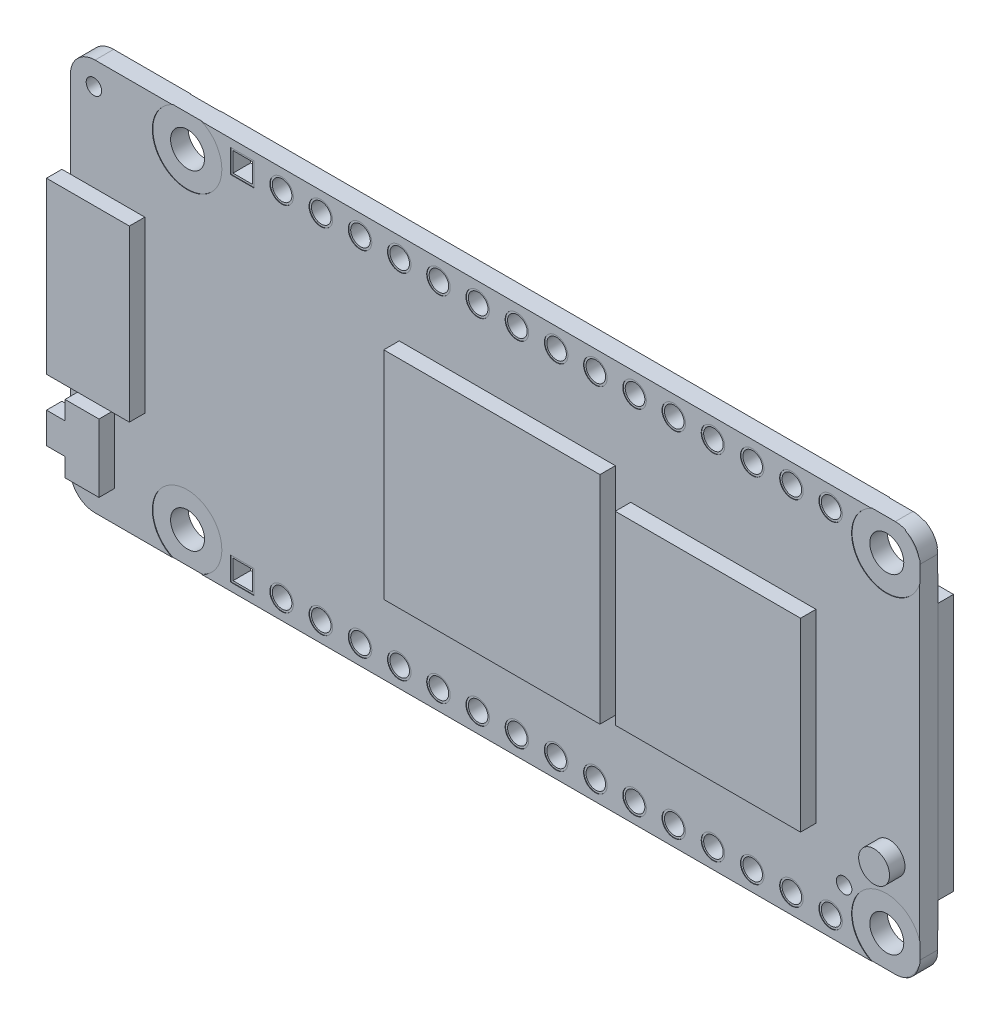
SolidWorks part; units mm, degrees
ref_plane "前视基准面" through (0, 0, 0) normal (0, 0, 1) x (1, 0, 0)
ref_plane "上视基准面" through (0, 0, 0) normal (0, 1, 0) x (1, 0, 0)
ref_plane "右视基准面" through (0, 0, 0) normal (1, 0, 0) x (0, 0, -1)
sketch "草图2" plane through (0, 0, 0) normal (0, 0, 1) x (1, 0, 0)
  line L0 (42.5323, 17.0667) -> (42.0497, 17.0667)
  line L1 (42.0497, 17.0667) -> (42.0497, 18.1843)
  line L2 (42.0497, 18.1843) -> (42.5323, 18.1843)
  line L3 (42.5323, 18.1843) -> (42.5323, 17.0667)
  line L4 (41.6323, 17.0667) -> (41.1497, 17.0667)
  line L5 (41.1497, 17.0667) -> (41.1497, 18.1843)
  line L6 (41.1497, 18.1843) -> (41.6323, 18.1843)
  line L7 (41.6323, 18.1843) -> (41.6323, 17.0667)
  line L8 (40.7323, 17.0667) -> (40.2497, 17.0667)
  line L9 (40.2497, 17.0667) -> (40.2497, 18.1843)
  line L10 (40.2497, 18.1843) -> (40.7323, 18.1843)
  line L11 (40.7323, 18.1843) -> (40.7323, 17.0667)
  line L12 (39.8323, 17.0667) -> (39.3497, 17.0667)
  line L13 (39.3497, 17.0667) -> (39.3497, 18.1843)
  line L14 (39.3497, 18.1843) -> (39.8323, 18.1843)
  line L15 (39.8323, 18.1843) -> (39.8323, 17.0667)
  line L16 (38.9323, 17.0667) -> (38.4497, 17.0667)
  line L17 (38.4497, 17.0667) -> (38.4497, 18.1843)
  line L18 (38.4497, 18.1843) -> (38.9323, 18.1843)
  line L19 (38.9323, 18.1843) -> (38.9323, 17.0667)
  line L20 (38.0323, 17.0667) -> (37.5497, 17.0667)
  line L21 (37.5497, 17.0667) -> (37.5497, 18.1843)
  line L22 (37.5497, 18.1843) -> (38.0323, 18.1843)
  line L23 (38.0323, 18.1843) -> (38.0323, 17.0667)
  line L24 (43.4323, 17.0667) -> (42.9497, 17.0667)
  line L25 (42.9497, 17.0667) -> (42.9497, 18.1843)
  line L26 (42.9497, 18.1843) -> (43.4323, 18.1843)
  line L27 (43.4323, 18.1843) -> (43.4323, 17.0667)
  line L28 (44.3323, 17.0667) -> (43.8497, 17.0667)
  line L29 (43.8497, 17.0667) -> (43.8497, 18.1843)
  line L30 (43.8497, 18.1843) -> (44.3323, 18.1843)
  line L31 (44.3323, 18.1843) -> (44.3323, 17.0667)
  line L32 (45.2323, 17.0667) -> (44.7497, 17.0667)
  line L33 (44.7497, 17.0667) -> (44.7497, 18.1843)
  line L34 (44.7497, 18.1843) -> (45.2323, 18.1843)
  line L35 (45.2323, 18.1843) -> (45.2323, 17.0667)
  line L36 (46.1323, 17.0667) -> (45.6497, 17.0667)
  line L37 (45.6497, 17.0667) -> (45.6497, 18.1843)
  line L38 (45.6497, 18.1843) -> (46.1323, 18.1843)
  line L39 (46.1323, 18.1843) -> (46.1323, 17.0667)
  line L40 (47.0323, 17.0667) -> (46.5497, 17.0667)
  line L41 (46.5497, 17.0667) -> (46.5497, 18.1843)
  line L42 (46.5497, 18.1843) -> (47.0323, 18.1843)
  line L43 (47.0323, 18.1843) -> (47.0323, 17.0667)
  line L44 (47.0323, 5.6917) -> (46.5497, 5.6917)
  line L45 (46.5497, 5.6917) -> (46.5497, 6.8093)
  line L46 (46.5497, 6.8093) -> (47.0323, 6.8093)
  line L47 (47.0323, 6.8093) -> (47.0323, 5.6917)
  line L48 (46.1323, 5.6917) -> (45.6497, 5.6917)
  line L49 (45.6497, 5.6917) -> (45.6497, 6.8093)
  line L50 (45.6497, 6.8093) -> (46.1323, 6.8093)
  line L51 (46.1323, 6.8093) -> (46.1323, 5.6917)
  line L52 (45.2323, 5.6917) -> (44.7497, 5.6917)
  line L53 (44.7497, 5.6917) -> (44.7497, 6.8093)
  line L54 (44.7497, 6.8093) -> (45.2323, 6.8093)
  line L55 (45.2323, 6.8093) -> (45.2323, 5.6917)
  line L56 (44.3323, 5.6917) -> (43.8497, 5.6917)
  line L57 (43.8497, 5.6917) -> (43.8497, 6.8093)
  line L58 (43.8497, 6.8093) -> (44.3323, 6.8093)
  line L59 (44.3323, 6.8093) -> (44.3323, 5.6917)
  line L60 (43.4323, 5.6917) -> (42.9497, 5.6917)
  line L61 (42.9497, 5.6917) -> (42.9497, 6.8093)
  line L62 (42.9497, 6.8093) -> (43.4323, 6.8093)
  line L63 (43.4323, 6.8093) -> (43.4323, 5.6917)
  line L64 (38.0323, 5.6917) -> (37.5497, 5.6917)
  line L65 (37.5497, 5.6917) -> (37.5497, 6.8093)
  line L66 (37.5497, 6.8093) -> (38.0323, 6.8093)
  line L67 (38.0323, 6.8093) -> (38.0323, 5.6917)
  line L68 (38.9323, 5.6917) -> (38.4497, 5.6917)
  line L69 (38.4497, 5.6917) -> (38.4497, 6.8093)
  line L70 (38.4497, 6.8093) -> (38.9323, 6.8093)
  line L71 (38.9323, 6.8093) -> (38.9323, 5.6917)
  line L72 (39.8323, 5.6917) -> (39.3497, 5.6917)
  line L73 (39.3497, 5.6917) -> (39.3497, 6.8093)
  line L74 (39.3497, 6.8093) -> (39.8323, 6.8093)
  line L75 (39.8323, 6.8093) -> (39.8323, 5.6917)
  line L76 (40.7323, 5.6917) -> (40.2497, 5.6917)
  line L77 (40.2497, 5.6917) -> (40.2497, 6.8093)
  line L78 (40.2497, 6.8093) -> (40.7323, 6.8093)
  line L79 (40.7323, 6.8093) -> (40.7323, 5.6917)
  line L80 (41.6323, 5.6917) -> (41.1497, 5.6917)
  line L81 (41.1497, 5.6917) -> (41.1497, 6.8093)
  line L82 (41.1497, 6.8093) -> (41.6323, 6.8093)
  line L83 (41.6323, 6.8093) -> (41.6323, 5.6917)
  line L84 (42.5323, 5.6917) -> (42.0497, 5.6917)
  line L85 (42.0497, 5.6917) -> (42.0497, 6.8093)
  line L86 (42.0497, 6.8093) -> (42.5323, 6.8093)
  line L87 (42.5323, 6.8093) -> (42.5323, 5.6917)
  line L88 (37.1623, 12.1793) -> (37.1623, 11.6967)
  line L89 (37.1623, 11.6967) -> (36.0447, 11.6967)
  line L90 (36.0447, 11.6967) -> (36.0447, 12.1793)
  line L91 (36.0447, 12.1793) -> (37.1623, 12.1793)
  line L92 (37.1623, 13.0793) -> (37.1623, 12.5967)
  line L93 (37.1623, 12.5967) -> (36.0447, 12.5967)
  line L94 (36.0447, 12.5967) -> (36.0447, 13.0793)
  line L95 (36.0447, 13.0793) -> (37.1623, 13.0793)
  line L96 (37.1623, 11.2793) -> (37.1623, 10.7967)
  line L97 (37.1623, 10.7967) -> (36.0447, 10.7967)
  line L98 (36.0447, 10.7967) -> (36.0447, 11.2793)
  line L99 (36.0447, 11.2793) -> (37.1623, 11.2793)
  line L100 (37.1623, 10.3793) -> (37.1623, 9.8967)
  line L101 (37.1623, 9.8967) -> (36.0447, 9.8967)
  line L102 (36.0447, 9.8967) -> (36.0447, 10.3793)
  line L103 (36.0447, 10.3793) -> (37.1623, 10.3793)
  line L104 (37.1623, 9.4793) -> (37.1623, 8.9967)
  line L105 (37.1623, 8.9967) -> (36.0447, 8.9967)
  line L106 (36.0447, 8.9967) -> (36.0447, 9.4793)
  line L107 (36.0447, 9.4793) -> (37.1623, 9.4793)
  line L108 (37.1623, 8.5793) -> (37.1623, 8.0967)
  line L109 (37.1623, 8.0967) -> (36.0447, 8.0967)
  line L110 (36.0447, 8.0967) -> (36.0447, 8.5793)
  line L111 (36.0447, 8.5793) -> (37.1623, 8.5793)
  line L112 (37.1623, 7.6793) -> (37.1623, 7.1967)
  line L113 (37.1623, 7.1967) -> (36.0447, 7.1967)
  line L114 (36.0447, 7.1967) -> (36.0447, 7.6793)
  line L115 (36.0447, 7.6793) -> (37.1623, 7.6793)
  line L116 (37.1623, 13.9793) -> (37.1623, 13.4967)
  line L117 (37.1623, 13.4967) -> (36.0447, 13.4967)
  line L118 (36.0447, 13.4967) -> (36.0447, 13.9793)
  line L119 (36.0447, 13.9793) -> (37.1623, 13.9793)
  line L120 (37.1623, 14.8793) -> (37.1623, 14.3967)
  line L121 (37.1623, 14.3967) -> (36.0447, 14.3967)
  line L122 (36.0447, 14.3967) -> (36.0447, 14.8793)
  line L123 (36.0447, 14.8793) -> (37.1623, 14.8793)
  line L124 (37.1623, 15.7793) -> (37.1623, 15.2967)
  line L125 (37.1623, 15.2967) -> (36.0447, 15.2967)
  line L126 (36.0447, 15.2967) -> (36.0447, 15.7793)
  line L127 (36.0447, 15.7793) -> (37.1623, 15.7793)
  line L128 (37.1623, 16.6793) -> (37.1623, 16.1967)
  line L129 (37.1623, 16.1967) -> (36.0447, 16.1967)
  line L130 (36.0447, 16.1967) -> (36.0447, 16.6793)
  line L131 (36.0447, 16.6793) -> (37.1623, 16.6793)
  line L132 (48.5373, 7.6793) -> (48.5373, 7.1967)
  line L133 (48.5373, 7.1967) -> (47.4197, 7.1967)
  line L134 (47.4197, 7.1967) -> (47.4197, 7.6793)
  line L135 (47.4197, 7.6793) -> (48.5373, 7.6793)
  line L136 (48.5373, 8.5793) -> (48.5373, 8.0967)
  line L137 (48.5373, 8.0967) -> (47.4197, 8.0967)
  line L138 (47.4197, 8.0967) -> (47.4197, 8.5793)
  line L139 (47.4197, 8.5793) -> (48.5373, 8.5793)
  line L140 (48.5373, 9.4793) -> (48.5373, 8.9967)
  line L141 (48.5373, 8.9967) -> (47.4197, 8.9967)
  line L142 (47.4197, 8.9967) -> (47.4197, 9.4793)
  line L143 (47.4197, 9.4793) -> (48.5373, 9.4793)
  line L144 (48.5373, 10.3793) -> (48.5373, 9.8967)
  line L145 (48.5373, 9.8967) -> (47.4197, 9.8967)
  line L146 (47.4197, 9.8967) -> (47.4197, 10.3793)
  line L147 (47.4197, 10.3793) -> (48.5373, 10.3793)
  line L148 (48.5373, 11.2793) -> (48.5373, 10.7967)
  line L149 (48.5373, 10.7967) -> (47.4197, 10.7967)
  line L150 (47.4197, 10.7967) -> (47.4197, 11.2793)
  line L151 (47.4197, 11.2793) -> (48.5373, 11.2793)
  line L152 (48.5373, 16.6793) -> (48.5373, 16.1967)
  line L153 (48.5373, 16.1967) -> (47.4197, 16.1967)
  line L154 (47.4197, 16.1967) -> (47.4197, 16.6793)
  line L155 (47.4197, 16.6793) -> (48.5373, 16.6793)
  line L156 (48.5373, 15.7793) -> (48.5373, 15.2967)
  line L157 (48.5373, 15.2967) -> (47.4197, 15.2967)
  line L158 (47.4197, 15.2967) -> (47.4197, 15.7793)
  line L159 (47.4197, 15.7793) -> (48.5373, 15.7793)
  line L160 (48.5373, 14.8793) -> (48.5373, 14.3967)
  line L161 (48.5373, 14.3967) -> (47.4197, 14.3967)
  line L162 (47.4197, 14.3967) -> (47.4197, 14.8793)
  line L163 (47.4197, 14.8793) -> (48.5373, 14.8793)
  line L164 (48.5373, 13.9793) -> (48.5373, 13.4967)
  line L165 (48.5373, 13.4967) -> (47.4197, 13.4967)
  line L166 (47.4197, 13.4967) -> (47.4197, 13.9793)
  line L167 (47.4197, 13.9793) -> (48.5373, 13.9793)
  line L168 (48.5373, 13.0793) -> (48.5373, 12.5967)
  line L169 (48.5373, 12.5967) -> (47.4197, 12.5967)
  line L170 (47.4197, 12.5967) -> (47.4197, 13.0793)
  line L171 (47.4197, 13.0793) -> (48.5373, 13.0793)
  line L172 (48.5373, 12.1793) -> (48.5373, 11.6967)
  line L173 (48.5373, 11.6967) -> (47.4197, 11.6967)
  line L174 (47.4197, 11.6967) -> (47.4197, 12.1793)
  line L175 (47.4197, 12.1793) -> (48.5373, 12.1793)
  line L176 (47.741, 6.3466) -> (47.741, 6.6294)
  line L177 (47.5996, 6.488) -> (47.8824, 6.488)
  line L178 (48.291, 5.938) -> (48.291, 7.038)
  line L179 (48.191, 6.488) -> (48.391, 6.488)
  line L180 (47.741, 5.838) -> (47.741, 6.038)
  line L181 (47.191, 5.938) -> (48.291, 5.938)
  line L182 (47.1203, 6.0087) -> (48.2203, 7.1087)
  line L183 (47.2617, 5.8673) -> (47.1203, 6.0087)
  line L184 (48.3617, 6.9673) -> (47.2617, 5.8673)
  line L185 (48.2203, 7.1087) -> (48.3617, 6.9673)
  line L186 (48.391, 7.038) -> (48.391, 5.938)
  line L187 (48.191, 7.038) -> (48.391, 7.038)
  line L188 (48.191, 5.938) -> (48.191, 7.038)
  line L189 (48.391, 5.938) -> (48.191, 5.938)
  line L190 (48.291, 5.838) -> (47.191, 5.838)
  line L191 (48.291, 6.038) -> (48.291, 5.838)
  line L192 (47.191, 6.038) -> (48.291, 6.038)
  line L193 (47.191, 5.838) -> (47.191, 6.038)
  line L194 (48.291, 17.938) -> (48.291, 16.838)
  line L195 (48.191, 17.388) -> (48.391, 17.388)
  line L196 (47.791, 18.038) -> (47.791, 17.838)
  line L197 (47.291, 17.938) -> (48.291, 17.938)
  line L198 (48.391, 16.838) -> (48.391, 17.938)
  line L199 (48.191, 16.838) -> (48.391, 16.838)
  line L200 (48.191, 17.938) -> (48.191, 16.838)
  line L201 (48.391, 17.938) -> (48.191, 17.938)
  line L202 (48.291, 18.038) -> (47.291, 18.038)
  line L203 (48.291, 17.838) -> (48.291, 18.038)
  line L204 (47.291, 17.838) -> (48.291, 17.838)
  line L205 (47.291, 18.038) -> (47.291, 17.838)
  line L206 (36.291, 17.938) -> (37.391, 17.938)
  line L207 (36.841, 17.838) -> (36.841, 18.038)
  line L208 (36.191, 17.388) -> (36.391, 17.388)
  line L209 (36.291, 16.838) -> (36.291, 17.938)
  line L210 (37.391, 18.038) -> (36.291, 18.038)
  line L211 (37.391, 17.838) -> (37.391, 18.038)
  line L212 (36.291, 17.838) -> (37.391, 17.838)
  line L213 (36.291, 18.038) -> (36.291, 17.838)
  line L214 (36.191, 17.938) -> (36.191, 16.838)
  line L215 (36.391, 17.938) -> (36.191, 17.938)
  line L216 (36.391, 16.838) -> (36.391, 17.938)
  line L217 (36.191, 16.838) -> (36.391, 16.838)
  line L218 (36.291, 5.938) -> (36.291, 7.038)
  line L219 (36.391, 6.488) -> (36.191, 6.488)
  line L220 (36.791, 5.838) -> (36.791, 6.038)
  line L221 (37.291, 5.938) -> (36.291, 5.938)
  line L222 (36.191, 7.038) -> (36.191, 5.938)
  line L223 (36.391, 7.038) -> (36.191, 7.038)
  line L224 (36.391, 5.938) -> (36.391, 7.038)
  line L225 (36.191, 5.938) -> (36.391, 5.938)
  line L226 (36.291, 5.838) -> (37.291, 5.838)
  line L227 (36.291, 6.038) -> (36.291, 5.838)
  line L228 (37.291, 6.038) -> (36.291, 6.038)
  line L229 (37.291, 5.838) -> (37.291, 6.038)
  line L230 (47.491, 5.938) -> (47.491, 5.338)
  line L231 (47.491, 5.338) -> (48.791, 5.338)
  line L232 (48.791, 5.338) -> (48.791, 6.838)
  line L233 (48.791, 6.838) -> (48.291, 6.838)
  line L234 (48.291, 6.838) -> (48.291, 5.938)
  line L235 (48.291, 5.938) -> (47.491, 5.938)
  line L236 (5.0999, 9.75) -> (4.9, 9.75)
  line L237 (4.9, 10.8) -> (5.0999, 10.8)
  line L238 (5.0999, 9.75) -> (4.9, 9.75)
  line L239 (4.9, 10.8) -> (5.0999, 10.8)
  line L240 (5.0999, 14.6) -> (4.9, 14.6)
  line L241 (4.9, 15.65) -> (5.0999, 15.65)
  line L242 (5.0999, 14.6) -> (4.9, 14.6)
  line L243 (4.9, 15.65) -> (5.0999, 15.65)
  line L244 (1.0831, 12.4905) -> (3.0643, 12.4905)
  line L245 (3.0643, 12.4905) -> (3.0643, 10.5093)
  line L246 (3.0643, 10.5093) -> (1.0831, 10.5093)
  line L247 (1.0831, 10.5093) -> (1.0831, 12.4905)
  line L248 (1.0831, 14.8905) -> (3.0643, 14.8905)
  line L249 (3.0643, 14.8905) -> (3.0643, 12.9093)
  line L250 (3.0643, 12.9093) -> (1.0831, 12.9093)
  line L251 (1.0831, 12.9093) -> (1.0831, 14.8905)
  line L252 (2.4547, 8.5284) -> (1.6927, 8.5284)
  line L253 (1.6927, 9.6714) -> (2.4547, 9.6714)
  line L254 (2.4547, 8.5284) -> (1.6927, 8.5284)
  line L255 (1.6927, 9.6714) -> (2.4547, 9.6714)
  line L256 (2.4547, 15.7284) -> (1.6927, 15.7284)
  line L257 (1.6927, 16.8714) -> (2.4547, 16.8714)
  line L258 (2.4547, 15.7284) -> (1.6927, 15.7284)
  line L259 (1.6927, 16.8714) -> (2.4547, 16.8714)
  line L260 (4.2487, 11.6032) -> (5.8489, 11.6032)
  line L261 (5.8489, 11.6032) -> (5.8489, 11.1968)
  line L262 (5.8489, 11.1968) -> (4.2487, 11.1968)
  line L263 (4.2487, 11.1968) -> (4.2487, 11.6032)
  line L264 (4.2487, 12.2532) -> (5.8489, 12.2532)
  line L265 (5.8489, 12.2532) -> (5.8489, 11.8468)
  line L266 (5.8489, 11.8468) -> (4.2487, 11.8468)
  line L267 (4.2487, 11.8468) -> (4.2487, 12.2532)
  line L268 (4.2487, 12.9032) -> (5.8489, 12.9032)
  line L269 (5.8489, 12.9032) -> (5.8489, 12.4968)
  line L270 (5.8489, 12.4968) -> (4.2487, 12.4968)
  line L271 (4.2487, 12.4968) -> (4.2487, 12.9032)
  line L272 (4.2487, 13.5532) -> (5.8489, 13.5532)
  line L273 (5.8489, 13.5532) -> (5.8489, 13.1468)
  line L274 (5.8489, 13.1468) -> (4.2487, 13.1468)
  line L275 (4.2487, 13.1468) -> (4.2487, 13.5532)
  line L276 (4.2487, 14.2032) -> (5.8489, 14.2032)
  line L277 (5.8489, 14.2032) -> (5.8489, 13.7968)
  line L278 (5.8489, 13.7968) -> (4.2487, 13.7968)
  line L279 (4.2487, 13.7968) -> (4.2487, 14.2032)
  line L280 (5.025, 8.89) -> (3.181, 8.89)
  line L281 (4.103, 8.99) -> (4.103, 8.79)
  line L282 (5.125, 9.2075) -> (4.925, 9.2075)
  line L283 (5.025, 9.525) -> (5.025, 8.89)
  line L284 (3.181, 8.79) -> (5.025, 8.79)
  line L285 (3.181, 8.99) -> (3.181, 8.79)
  line L286 (5.025, 8.99) -> (3.181, 8.99)
  line L287 (5.025, 8.79) -> (5.025, 8.99)
  line L288 (5.125, 8.89) -> (5.125, 9.525)
  line L289 (4.925, 8.89) -> (5.125, 8.89)
  line L290 (4.925, 9.525) -> (4.925, 8.89)
  line L291 (5.125, 9.525) -> (4.925, 9.525)
  line L292 (0.6335, 8.99) -> (0.6335, 8.79)
  line L293 (1.332, 8.89) -> (-0.065, 8.89)
  line L294 (-0.319, 8.7774) -> (-0.319, 8.4946)
  line L295 (-0.1776, 8.636) -> (-0.4604, 8.636)
  line L296 (-0.611, 8.496) -> (-0.611, 8.344)
  line L297 (-0.535, 8.42) -> (-0.687, 8.42)
  line L298 (-0.649, 8.68) -> (-0.649, 8.458)
  line L299 (-0.549, 8.569) -> (-0.749, 8.569)
  line L300 (-0.357, 9.1134) -> (-0.357, 8.8306)
  line L301 (-0.2156, 8.972) -> (-0.4984, 8.972)
  line L302 (-0.065, 16.136) -> (-0.065, 9.264)
  line L303 (0.035, 12.7) -> (-0.165, 12.7)
  line L304 (-0.357, 16.5694) -> (-0.357, 16.2866)
  line L305 (-0.2156, 16.428) -> (-0.4984, 16.428)
  line L306 (-0.649, 16.942) -> (-0.649, 16.72)
  line L307 (-0.549, 16.831) -> (-0.749, 16.831)
  line L308 (-0.611, 17.056) -> (-0.611, 16.904)
  line L309 (-0.535, 16.98) -> (-0.687, 16.98)
  line L310 (-0.319, 16.9054) -> (-0.319, 16.6226)
  line L311 (-0.1776, 16.764) -> (-0.4604, 16.764)
  line L312 (0.6335, 16.61) -> (0.6335, 16.41)
  line L313 (1.332, 16.51) -> (-0.065, 16.51)
  line L314 (1.332, 8.79) -> (-0.065, 8.79)
  line L315 (1.332, 8.99) -> (1.332, 8.79)
  line L316 (-0.065, 8.99) -> (1.332, 8.99)
  line L317 (-0.065, 8.79) -> (-0.065, 8.99)
  line L318 (0.0057, 8.8193) -> (-0.5023, 8.3113)
  line L319 (-0.1357, 8.9607) -> (0.0057, 8.8193)
  line L320 (-0.6437, 8.4527) -> (-0.1357, 8.9607)
  line L321 (-0.5023, 8.3113) -> (-0.6437, 8.4527)
  line L322 (-0.6437, 8.3113) -> (-0.7197, 8.3873)
  line L323 (-0.5023, 8.4527) -> (-0.6437, 8.3113)
  line L324 (-0.5783, 8.5287) -> (-0.5023, 8.4527)
  line L325 (-0.7197, 8.3873) -> (-0.5783, 8.5287)
  line L326 (-0.749, 8.458) -> (-0.749, 8.68)
  line L327 (-0.549, 8.458) -> (-0.749, 8.458)
  line L328 (-0.549, 8.68) -> (-0.549, 8.458)
  line L329 (-0.749, 8.68) -> (-0.549, 8.68)
  line L330 (-0.7197, 8.7507) -> (-0.1357, 9.3347)
  line L331 (-0.5783, 8.6093) -> (-0.7197, 8.7507)
  line L332 (0.0057, 9.1933) -> (-0.5783, 8.6093)
  line L333 (-0.1357, 9.3347) -> (0.0057, 9.1933)
  line L334 (-0.165, 9.264) -> (-0.165, 16.136)
  line L335 (0.035, 9.264) -> (-0.165, 9.264)
  line L336 (0.035, 16.136) -> (0.035, 9.264)
  line L337 (-0.165, 16.136) -> (0.035, 16.136)
  line L338 (-0.1357, 16.0653) -> (-0.7197, 16.6493)
  line L339 (0.0057, 16.2067) -> (-0.1357, 16.0653)
  line L340 (-0.5783, 16.7907) -> (0.0057, 16.2067)
  line L341 (-0.7197, 16.6493) -> (-0.5783, 16.7907)
  line L342 (-0.749, 16.72) -> (-0.749, 16.942)
  line L343 (-0.549, 16.72) -> (-0.749, 16.72)
  line L344 (-0.549, 16.942) -> (-0.549, 16.72)
  line L345 (-0.749, 16.942) -> (-0.549, 16.942)
  line L346 (-0.7197, 17.0127) -> (-0.6437, 17.0887)
  line L347 (-0.5783, 16.8713) -> (-0.7197, 17.0127)
  line L348 (-0.5023, 16.9473) -> (-0.5783, 16.8713)
  line L349 (-0.6437, 17.0887) -> (-0.5023, 16.9473)
  line L350 (-0.5023, 17.0887) -> (0.0057, 16.5807)
  line L351 (-0.6437, 16.9473) -> (-0.5023, 17.0887)
  line L352 (-0.1357, 16.4393) -> (-0.6437, 16.9473)
  line L353 (0.0057, 16.5807) -> (-0.1357, 16.4393)
  line L354 (-0.065, 16.61) -> (1.332, 16.61)
  line L355 (-0.065, 16.41) -> (-0.065, 16.61)
  line L356 (1.332, 16.41) -> (-0.065, 16.41)
  line L357 (1.332, 16.61) -> (1.332, 16.41)
  line L358 (5.025, 16.51) -> (3.201, 16.51)
  line L359 (4.113, 16.41) -> (4.113, 16.61)
  line L360 (5.125, 16.1925) -> (4.925, 16.1925)
  line L361 (5.025, 15.875) -> (5.025, 16.51)
  line L362 (3.201, 16.61) -> (5.025, 16.61)
  line L363 (3.201, 16.41) -> (3.201, 16.61)
  line L364 (5.025, 16.41) -> (3.201, 16.41)
  line L365 (5.025, 16.61) -> (5.025, 16.41)
  line L366 (5.125, 16.51) -> (5.125, 15.875)
  line L367 (4.925, 16.51) -> (5.125, 16.51)
  line L368 (4.925, 15.875) -> (4.925, 16.51)
  line L369 (5.125, 15.875) -> (4.925, 15.875)
  line L370 (3.7519, 5.291) -> (2.452, 5.291)
  line L371 (2.452, 5.291) -> (2.452, 6.441)
  line L372 (2.452, 6.441) -> (3.7519, 6.441)
  line L373 (3.7519, 6.441) -> (3.7519, 5.291)
  line L374 (3.7519, 1.941) -> (2.452, 1.941)
  line L375 (2.452, 1.941) -> (2.452, 3.091)
  line L376 (2.452, 3.091) -> (3.7519, 3.091)
  line L377 (3.7519, 3.091) -> (3.7519, 1.941)
  line L378 (2.1519, 6.041) -> (0.9519, 6.041)
  line L379 (0.9519, 6.041) -> (0.9519, 6.941)
  line L380 (0.9519, 6.941) -> (2.1519, 6.941)
  line L381 (2.1519, 6.941) -> (2.1519, 6.041)
  line L382 (2.1519, 1.441) -> (0.9519, 1.441)
  line L383 (0.9519, 1.441) -> (0.9519, 2.341)
  line L384 (0.9519, 2.341) -> (2.1519, 2.341)
  line L385 (2.1519, 2.341) -> (2.1519, 1.441)
  line L386 (1.7519, 5.691) -> (1.7519, 4.691)
  line L387 (1.8119, 5.191) -> (1.6919, 5.191)
  line L388 (2.0019, 5.751) -> (2.0019, 5.631)
  line L389 (2.2519, 5.691) -> (1.7519, 5.691)
  line L390 (1.6919, 4.691) -> (1.6919, 5.691)
  line L391 (1.8119, 4.691) -> (1.6919, 4.691)
  line L392 (1.8119, 5.691) -> (1.8119, 4.691)
  line L393 (1.6919, 5.691) -> (1.8119, 5.691)
  line L394 (1.7519, 5.751) -> (2.2519, 5.751)
  line L395 (1.7519, 5.631) -> (1.7519, 5.751)
  line L396 (2.2519, 5.631) -> (1.7519, 5.631)
  line L397 (2.2519, 5.751) -> (2.2519, 5.631)
  line L398 (1.4019, 4.0864) -> (1.4019, 4.2956)
  line L399 (1.4752, 4.191) -> (1.3287, 4.191)
  line L400 (1.7519, 2.691) -> (1.7519, 3.691)
  line L401 (1.8119, 3.191) -> (1.6919, 3.191)
  line L402 (2.0019, 2.631) -> (2.0019, 2.751)
  line L403 (2.2519, 2.691) -> (1.7519, 2.691)
  line L404 (1.0028, 4.6566) -> (1.7028, 3.6566)
  line L405 (1.1011, 4.7254) -> (1.0028, 4.6566)
  line L406 (1.8011, 3.7254) -> (1.1011, 4.7254)
  line L407 (1.7028, 3.6566) -> (1.8011, 3.7254)
  line L408 (1.6919, 3.691) -> (1.6919, 2.691)
  line L409 (1.8119, 3.691) -> (1.6919, 3.691)
  line L410 (1.8119, 2.691) -> (1.8119, 3.691)
  line L411 (1.6919, 2.691) -> (1.8119, 2.691)
  line L412 (1.7519, 2.631) -> (2.2519, 2.631)
  line L413 (1.7519, 2.751) -> (1.7519, 2.631)
  line L414 (2.2519, 2.751) -> (1.7519, 2.751)
  line L415 (2.2519, 2.631) -> (2.2519, 2.751)
  line L416 (0.5919, 2.591) -> (0.7119, 2.591)
  line L417 (0.6519, 1.991) -> (0.6519, 3.191)
  line L418 (0.6519, 1.991) -> (2.8519, 1.991)
  line L419 (1.7519, 1.931) -> (1.7519, 2.051)
  line L420 (2.7919, 4.191) -> (2.9119, 4.191)
  line L421 (2.8519, 1.991) -> (2.8519, 6.391)
  line L422 (0.6519, 6.391) -> (2.8519, 6.391)
  line L423 (1.7519, 6.331) -> (1.7519, 6.451)
  line L424 (0.5919, 5.791) -> (0.7119, 5.791)
  line L425 (0.6519, 5.191) -> (0.6519, 6.391)
  line L426 (0.5919, 3.191) -> (0.5919, 1.991)
  line L427 (0.7119, 3.191) -> (0.5919, 3.191)
  line L428 (0.7119, 1.991) -> (0.7119, 3.191)
  line L429 (0.5919, 1.991) -> (0.7119, 1.991)
  line L430 (0.6519, 1.931) -> (2.8519, 1.931)
  line L431 (0.6519, 2.051) -> (0.6519, 1.931)
  line L432 (2.8519, 2.051) -> (0.6519, 2.051)
  line L433 (2.8519, 1.931) -> (2.8519, 2.051)
  line L434 (2.9119, 1.991) -> (2.9119, 6.391)
  line L435 (2.7919, 1.991) -> (2.9119, 1.991)
  line L436 (2.7919, 6.391) -> (2.7919, 1.991)
  line L437 (2.9119, 6.391) -> (2.7919, 6.391)
  line L438 (2.8519, 6.451) -> (0.6519, 6.451)
  line L439 (2.8519, 6.331) -> (2.8519, 6.451)
  line L440 (0.6519, 6.331) -> (2.8519, 6.331)
  line L441 (0.6519, 6.451) -> (0.6519, 6.331)
  line L442 (0.5919, 6.391) -> (0.5919, 5.191)
  line L443 (0.7119, 6.391) -> (0.5919, 6.391)
  line L444 (0.7119, 5.191) -> (0.7119, 6.391)
  line L445 (0.5919, 5.191) -> (0.7119, 5.191)
  line L446 (-0.5481, 3.191) -> (0.6519, 3.191)
  line L447 (0.0519, 3.131) -> (0.0519, 3.251)
  line L448 (0.5919, 4.191) -> (0.7119, 4.191)
  line L449 (0.6519, 3.191) -> (0.6519, 5.191)
  line L450 (-0.5481, 5.191) -> (0.6519, 5.191)
  line L451 (0.0519, 5.131) -> (0.0519, 5.251)
  line L452 (-0.6081, 4.191) -> (-0.4881, 4.191)
  line L453 (-0.5481, 3.191) -> (-0.5481, 5.191)
  line L454 (-0.5481, 3.131) -> (0.6519, 3.131)
  line L455 (-0.5481, 3.251) -> (-0.5481, 3.131)
  line L456 (0.6519, 3.251) -> (-0.5481, 3.251)
  line L457 (0.6519, 3.131) -> (0.6519, 3.251)
  line L458 (0.7119, 3.191) -> (0.7119, 5.191)
  line L459 (0.5919, 3.191) -> (0.7119, 3.191)
  line L460 (0.5919, 5.191) -> (0.5919, 3.191)
  line L461 (0.7119, 5.191) -> (0.5919, 5.191)
  line L462 (0.6519, 5.251) -> (-0.5481, 5.251)
  line L463 (0.6519, 5.131) -> (0.6519, 5.251)
  line L464 (-0.5481, 5.131) -> (0.6519, 5.131)
  line L465 (-0.5481, 5.251) -> (-0.5481, 5.131)
  line L466 (-0.6081, 5.191) -> (-0.6081, 3.191)
  line L467 (-0.4881, 5.191) -> (-0.6081, 5.191)
  line L468 (-0.4881, 3.191) -> (-0.4881, 5.191)
  line L469 (-0.6081, 3.191) -> (-0.4881, 3.191)
  line L470 (49.8522, 8.0663) -> (50.0644, 8.2784)
  line L471 (50.0644, 8.2784) -> (50.2411, 8.1017)
  line L472 (50.2411, 8.1017) -> (50.029, 7.8896)
  line L473 (50.029, 7.8896) -> (49.8522, 8.0663)
  line L474 (50.2413, 7.6772) -> (50.4534, 7.8894)
  line L475 (50.4534, 7.8894) -> (50.6302, 7.7126)
  line L476 (50.6302, 7.7126) -> (50.418, 7.5005)
  line L477 (50.418, 7.5005) -> (50.2413, 7.6772)
  line L478 (50.4533, 8.0836) -> (50.4533, 8.1196)
  line L479 (50.4354, 8.1016) -> (50.4713, 8.1016)
  line L480 (50.8332, 7.7038) -> (50.0555, 8.4815)
  line L481 (50.8512, 7.7217) -> (50.8332, 7.7038)
  line L482 (50.0735, 8.4994) -> (50.8512, 7.7217)
  line L483 (50.0555, 8.4815) -> (50.0735, 8.4994)
  line L484 (50.63, 7.4827) -> (50.63, 7.5186)
  line L485 (50.6121, 7.5006) -> (50.648, 7.5006)
  line L486 (50.4089, 7.2975) -> (50.8332, 7.7217)
  line L487 (50.4269, 7.2795) -> (50.4089, 7.2975)
  line L488 (50.8512, 7.7038) -> (50.4269, 7.2795)
  line L489 (50.8332, 7.7217) -> (50.8512, 7.7038)
  line L490 (50.0291, 7.6594) -> (50.0291, 7.6953)
  line L491 (50.0111, 7.6773) -> (50.047, 7.6773)
  line L492 (49.6492, 8.0752) -> (50.4269, 7.2975)
  line L493 (49.6312, 8.0572) -> (49.6492, 8.0752)
  line L494 (50.4089, 7.2795) -> (49.6312, 8.0572)
  line L495 (50.4269, 7.2975) -> (50.4089, 7.2795)
  line L496 (49.8524, 8.2604) -> (49.8524, 8.2963)
  line L497 (49.8344, 8.2783) -> (49.8703, 8.2783)
  line L498 (50.0735, 8.4815) -> (49.6492, 8.0572)
  line L499 (50.0555, 8.4994) -> (50.0735, 8.4815)
  line L500 (49.6312, 8.0752) -> (50.0555, 8.4994)
  line L501 (49.6492, 8.0572) -> (49.6312, 8.0752)
  line L502 (24.1899, 4.0842) -> (22.4119, 4.0842)
  line L503 (22.4119, 3.4746) -> (24.1899, 3.4746)
  line L504 (24.1899, 5.3542) -> (22.4119, 5.3542)
  line L505 (22.4119, 4.7446) -> (24.1899, 4.7446)
  line L506 (24.1899, 6.6242) -> (22.4119, 6.6242)
  line L507 (22.4119, 6.0146) -> (24.1899, 6.0146)
  line L508 (24.1899, 7.8942) -> (22.4119, 7.8942)
  line L509 (22.4119, 7.2846) -> (24.1899, 7.2846)
  line L510 (17.6799, 7.8942) -> (15.9019, 7.8942)
  line L511 (15.9019, 7.2846) -> (17.6799, 7.2846)
  line L512 (17.6799, 6.6242) -> (15.9019, 6.6242)
  line L513 (15.9019, 6.0146) -> (17.6799, 6.0146)
  line L514 (17.6799, 5.3542) -> (15.9019, 5.3542)
  line L515 (15.9019, 4.7446) -> (17.6799, 4.7446)
  line L516 (17.6799, 4.0842) -> (15.9019, 4.0842)
  line L517 (15.9019, 3.4746) -> (17.6799, 3.4746)
  line L518 (22.5859, 8.2019) -> (22.7859, 8.2019)
  line L519 (22.6859, 8.0844) -> (22.6859, 8.3194)
  line L520 (17.4059, 8.3194) -> (22.6859, 8.3194)
  line L521 (20.0459, 8.2194) -> (20.0459, 8.4194)
  line L522 (17.3059, 8.1919) -> (17.5059, 8.1919)
  line L523 (17.4059, 8.0644) -> (17.4059, 8.3194)
  line L524 (22.7859, 8.0844) -> (22.7859, 8.3194)
  line L525 (22.5859, 8.0844) -> (22.7859, 8.0844)
  line L526 (22.5859, 8.3194) -> (22.5859, 8.0844)
  line L527 (22.7859, 8.3194) -> (22.5859, 8.3194)
  line L528 (22.6859, 8.4194) -> (17.4059, 8.4194)
  line L529 (22.6859, 8.2194) -> (22.6859, 8.4194)
  line L530 (17.4059, 8.2194) -> (22.6859, 8.2194)
  line L531 (17.4059, 8.4194) -> (17.4059, 8.2194)
  line L532 (17.3059, 8.3194) -> (17.3059, 8.0644)
  line L533 (17.5059, 8.3194) -> (17.3059, 8.3194)
  line L534 (17.5059, 8.0644) -> (17.5059, 8.3194)
  line L535 (17.3059, 8.0644) -> (17.5059, 8.0644)
  line L536 (22.5859, 3.1719) -> (22.7859, 3.1719)
  line L537 (22.6859, 3.3044) -> (22.6859, 3.0394)
  line L538 (17.4059, 3.0394) -> (22.6859, 3.0394)
  line L539 (20.0459, 3.1394) -> (20.0459, 2.9394)
  line L540 (17.3059, 3.1719) -> (17.5059, 3.1719)
  line L541 (17.4059, 3.3044) -> (17.4059, 3.0394)
  line L542 (22.7859, 3.3044) -> (22.7859, 3.0394)
  line L543 (22.5859, 3.3044) -> (22.7859, 3.3044)
  line L544 (22.5859, 3.0394) -> (22.5859, 3.3044)
  line L545 (22.7859, 3.0394) -> (22.5859, 3.0394)
  line L546 (22.6859, 2.9394) -> (17.4059, 2.9394)
  line L547 (22.6859, 3.1394) -> (22.6859, 2.9394)
  line L548 (17.4059, 3.1394) -> (22.6859, 3.1394)
  line L549 (17.4059, 2.9394) -> (17.4059, 3.1394)
  line L550 (17.3059, 3.0394) -> (17.3059, 3.3044)
  line L551 (17.5059, 3.0394) -> (17.3059, 3.0394)
  line L552 (17.5059, 3.3044) -> (17.5059, 3.0394)
  line L553 (17.3059, 3.3044) -> (17.5059, 3.3044)
  line L554 (18.0444, 3.0302) -> (18.0444, 4.0462)
  line L555 (18.0444, 4.0462) -> (19.0604, 3.0302)
  line L556 (19.0604, 3.0302) -> (18.0444, 3.0302)
  line L557 (0.6678, 22.009) -> (1.3678, 22.009)
  line L558 (1.3678, 22.009) -> (1.3678, 21.359)
  line L559 (1.3678, 21.359) -> (0.6678, 21.359)
  line L560 (0.6678, 21.359) -> (0.6678, 22.009)
  line L561 (2.1679, 22.009) -> (2.8678, 22.009)
  line L562 (2.8678, 22.009) -> (2.8678, 21.359)
  line L563 (2.8678, 21.359) -> (2.1679, 21.359)
  line L564 (2.1679, 21.359) -> (2.1679, 22.009)
  line L565 (0.6678, 21.059) -> (1.3678, 21.059)
  line L566 (1.3678, 21.059) -> (1.3678, 20.409)
  line L567 (1.3678, 20.409) -> (0.6678, 20.409)
  line L568 (0.6678, 20.409) -> (0.6678, 21.059)
  line L569 (2.1679, 21.059) -> (2.8678, 21.059)
  line L570 (2.8678, 21.059) -> (2.8678, 20.409)
  line L571 (2.8678, 20.409) -> (2.1679, 20.409)
  line L572 (2.1679, 20.409) -> (2.1679, 21.059)
  line L573 (1.8893, 21.059) -> (1.6064, 21.059)
  line L574 (1.7478, 20.9176) -> (1.7478, 21.2004)
  line L575 (1.8893, 21.359) -> (1.6064, 21.359)
  line L576 (1.7478, 21.2176) -> (1.7478, 21.5004)
  line L577 (1.9978, 21.209) -> (1.7978, 21.209)
  line L578 (1.8978, 20.909) -> (1.8978, 21.509)
  line L579 (1.8271, 20.8383) -> (1.5271, 21.1383)
  line L580 (1.9685, 20.9797) -> (1.8271, 20.8383)
  line L581 (1.6685, 21.2797) -> (1.9685, 20.9797)
  line L582 (1.5271, 21.1383) -> (1.6685, 21.2797)
  line L583 (1.5271, 21.2797) -> (1.8271, 21.5797)
  line L584 (1.6685, 21.1383) -> (1.5271, 21.2797)
  line L585 (1.9685, 21.4383) -> (1.6685, 21.1383)
  line L586 (1.8271, 21.5797) -> (1.9685, 21.4383)
  line L587 (1.9978, 21.509) -> (1.9978, 20.909)
  line L588 (1.7978, 21.509) -> (1.9978, 21.509)
  line L589 (1.7978, 20.909) -> (1.7978, 21.509)
  line L590 (1.9978, 20.909) -> (1.7978, 20.909)
  line L591 (3.0078, 20.219) -> (3.0078, 20.339)
  line L592 (3.0678, 20.279) -> (2.9478, 20.279)
  line L593 (3.0378, 20.309) -> (3.0378, 22.159)
  line L594 (3.1378, 21.234) -> (2.9378, 21.234)
  line L595 (1.8278, 22.059) -> (1.8278, 22.259)
  line L596 (3.0378, 22.159) -> (0.6179, 22.159)
  line L597 (0.5629, 21.994) -> (0.5629, 22.214)
  line L598 (0.6728, 22.104) -> (0.4529, 22.104)
  line L599 (0.5078, 20.379) -> (0.5078, 22.049)
  line L600 (0.6078, 21.214) -> (0.4078, 21.214)
  line L601 (0.5728, 20.184) -> (0.5728, 20.444)
  line L602 (0.7028, 20.314) -> (0.4428, 20.314)
  line L603 (1.8078, 20.149) -> (1.8078, 20.349)
  line L604 (2.9778, 20.249) -> (0.6378, 20.249)
  line L605 (3.0486, 20.1783) -> (3.1086, 20.2383)
  line L606 (2.9071, 20.3197) -> (3.0486, 20.1783)
  line L607 (2.9671, 20.3797) -> (2.9071, 20.3197)
  line L608 (3.1086, 20.2383) -> (2.9671, 20.3797)
  line L609 (3.1378, 20.309) -> (3.1378, 22.159)
  line L610 (2.9378, 20.309) -> (3.1378, 20.309)
  line L611 (2.9378, 22.159) -> (2.9378, 20.309)
  line L612 (3.1378, 22.159) -> (2.9378, 22.159)
  line L613 (3.0378, 22.259) -> (0.6179, 22.259)
  line L614 (3.0378, 22.059) -> (3.0378, 22.259)
  line L615 (0.6179, 22.059) -> (3.0378, 22.059)
  line L616 (0.6179, 22.259) -> (0.6179, 22.059)
  line L617 (0.5472, 22.2297) -> (0.4371, 22.1197)
  line L618 (0.6886, 22.0883) -> (0.5472, 22.2297)
  line L619 (0.5786, 21.9783) -> (0.6886, 22.0883)
  line L620 (0.4371, 22.1197) -> (0.5786, 21.9783)
  line L621 (0.4078, 22.049) -> (0.4078, 20.379)
  line L622 (0.6078, 22.049) -> (0.4078, 22.049)
  line L623 (0.6078, 20.379) -> (0.6078, 22.049)
  line L624 (0.4078, 20.379) -> (0.6078, 20.379)
  line L625 (0.4371, 20.3083) -> (0.5671, 20.1783)
  line L626 (0.5786, 20.4497) -> (0.4371, 20.3083)
  line L627 (0.7086, 20.3197) -> (0.5786, 20.4497)
  line L628 (0.5671, 20.1783) -> (0.7086, 20.3197)
  line L629 (0.6378, 20.149) -> (2.9778, 20.149)
  line L630 (0.6378, 20.349) -> (0.6378, 20.149)
  line L631 (2.9778, 20.349) -> (0.6378, 20.349)
  line L632 (2.9778, 20.149) -> (2.9778, 20.349)
  line L633 (10.3788, 24.892) -> (10.3788, 23.368)
  line L634 (10.3788, 23.368) -> (11.9028, 23.368)
  line L635 (11.9028, 23.368) -> (11.9028, 24.892)
  line L636 (11.9028, 24.892) -> (10.3788, 24.892)
  line L637 (10.5058, 24.765) -> (10.5058, 23.495)
  line L638 (10.5058, 23.495) -> (11.7758, 23.495)
  line L639 (11.7758, 23.495) -> (11.7758, 24.765)
  line L640 (11.7758, 24.765) -> (10.5058, 24.765)
  line L641 (10.6328, 25.4) -> (9.8708, 24.638)
  line L642 (10.3057, 24.9651) -> (10.1979, 25.0729)
  line L643 (11.217, 25.4762) -> (11.0646, 25.3238)
  line L644 (11.217, 25.3238) -> (11.0646, 25.4762)
  line L645 (12.0837, 25.0729) -> (11.9759, 24.9651)
  line L646 (12.4108, 24.638) -> (11.6488, 25.4)
  line L647 (9.8169, 24.6919) -> (10.5789, 25.4539)
  line L648 (9.9247, 24.5841) -> (9.8169, 24.6919)
  line L649 (10.6867, 25.3461) -> (9.9247, 24.5841)
  line L650 (10.5789, 25.4539) -> (10.6867, 25.3461)
  line L651 (10.6328, 25.4762) -> (11.6488, 25.4762)
  line L652 (10.6328, 25.3238) -> (10.6328, 25.4762)
  line L653 (11.6488, 25.3238) -> (10.6328, 25.3238)
  line L654 (11.6488, 25.4762) -> (11.6488, 25.3238)
  line L655 (11.7027, 25.4539) -> (12.4647, 24.6919)
  line L656 (11.5949, 25.3461) -> (11.7027, 25.4539)
  line L657 (12.3569, 24.5841) -> (11.5949, 25.3461)
  line L658 (12.4647, 24.6919) -> (12.3569, 24.5841)
  line L659 (9.947, 24.13) -> (9.7946, 24.13)
  line L660 (9.8708, 24.638) -> (9.8708, 23.622)
  line L661 (10.3596, 23.241) -> (10.144, 23.241)
  line L662 (10.2518, 23.3488) -> (10.2518, 23.1332)
  line L663 (11.6488, 22.86) -> (10.6328, 22.86)
  line L664 (11.1408, 22.9362) -> (11.1408, 22.7838)
  line L665 (12.1376, 23.241) -> (11.922, 23.241)
  line L666 (12.0298, 23.3488) -> (12.0298, 23.1332)
  line L667 (12.487, 24.13) -> (12.3346, 24.13)
  line L668 (12.4108, 24.638) -> (12.4108, 23.622)
  line L669 (9.7946, 24.638) -> (9.7946, 23.622)
  line L670 (9.947, 24.638) -> (9.7946, 24.638)
  line L671 (9.947, 23.622) -> (9.947, 24.638)
  line L672 (9.7946, 23.622) -> (9.947, 23.622)
  line L673 (9.8169, 23.5681) -> (10.5789, 22.8061)
  line L674 (9.9247, 23.6759) -> (9.8169, 23.5681)
  line L675 (10.6867, 22.9139) -> (9.9247, 23.6759)
  line L676 (10.5789, 22.8061) -> (10.6867, 22.9139)
  line L677 (10.6328, 22.7838) -> (11.6488, 22.7838)
  line L678 (10.6328, 22.9362) -> (10.6328, 22.7838)
  line L679 (11.6488, 22.9362) -> (10.6328, 22.9362)
  line L680 (11.6488, 22.7838) -> (11.6488, 22.9362)
  line L681 (11.7027, 22.8061) -> (12.4647, 23.5681)
  line L682 (11.5949, 22.9139) -> (11.7027, 22.8061)
  line L683 (12.3569, 23.6759) -> (11.5949, 22.9139)
  line L684 (12.4647, 23.5681) -> (12.3569, 23.6759)
  line L685 (12.487, 23.622) -> (12.487, 24.638)
  line L686 (12.3346, 23.622) -> (12.487, 23.622)
  line L687 (12.3346, 24.638) -> (12.3346, 23.622)
  line L688 (12.487, 24.638) -> (12.3346, 24.638)
  line L689 (12.487, 24.13) -> (12.3346, 24.13)
  line L690 (12.4108, 24.638) -> (12.4108, 23.622)
  line L691 (12.8996, 23.241) -> (12.684, 23.241)
  line L692 (12.7918, 23.3488) -> (12.7918, 23.1332)
  line L693 (14.1888, 22.86) -> (13.1728, 22.86)
  line L694 (13.6808, 22.9362) -> (13.6808, 22.7838)
  line L695 (14.6776, 23.241) -> (14.462, 23.241)
  line L696 (14.5698, 23.3488) -> (14.5698, 23.1332)
  line L697 (15.027, 24.13) -> (14.8746, 24.13)
  line L698 (14.9508, 24.638) -> (14.9508, 23.622)
  line L699 (12.3346, 24.638) -> (12.3346, 23.622)
  line L700 (12.487, 24.638) -> (12.3346, 24.638)
  line L701 (12.487, 23.622) -> (12.487, 24.638)
  line L702 (12.3346, 23.622) -> (12.487, 23.622)
  line L703 (12.3569, 23.5681) -> (13.1189, 22.8061)
  line L704 (12.4647, 23.6759) -> (12.3569, 23.5681)
  line L705 (13.2267, 22.9139) -> (12.4647, 23.6759)
  line L706 (13.1189, 22.8061) -> (13.2267, 22.9139)
  line L707 (13.1728, 22.7838) -> (14.1888, 22.7838)
  line L708 (13.1728, 22.9362) -> (13.1728, 22.7838)
  line L709 (14.1888, 22.9362) -> (13.1728, 22.9362)
  line L710 (14.1888, 22.7838) -> (14.1888, 22.9362)
  line L711 (14.2427, 22.8061) -> (15.0047, 23.5681)
  line L712 (14.1349, 22.9139) -> (14.2427, 22.8061)
  line L713 (14.8969, 23.6759) -> (14.1349, 22.9139)
  line L714 (15.0047, 23.5681) -> (14.8969, 23.6759)
  line L715 (15.027, 23.622) -> (15.027, 24.638)
  line L716 (14.8746, 23.622) -> (15.027, 23.622)
  line L717 (14.8746, 24.638) -> (14.8746, 23.622)
  line L718 (15.027, 24.638) -> (14.8746, 24.638)
  line L719 (13.1728, 25.4) -> (12.4108, 24.638)
  line L720 (12.8457, 24.9651) -> (12.7379, 25.0729)
  line L721 (13.757, 25.4762) -> (13.6046, 25.3238)
  line L722 (13.757, 25.3238) -> (13.6046, 25.4762)
  line L723 (14.6237, 25.0729) -> (14.5159, 24.9651)
  line L724 (14.9508, 24.638) -> (14.1888, 25.4)
  line L725 (12.3569, 24.6919) -> (13.1189, 25.4539)
  line L726 (12.4647, 24.5841) -> (12.3569, 24.6919)
  line L727 (13.2267, 25.3461) -> (12.4647, 24.5841)
  line L728 (13.1189, 25.4539) -> (13.2267, 25.3461)
  line L729 (13.1728, 25.4762) -> (14.1888, 25.4762)
  line L730 (13.1728, 25.3238) -> (13.1728, 25.4762)
  line L731 (14.1888, 25.3238) -> (13.1728, 25.3238)
  line L732 (14.1888, 25.4762) -> (14.1888, 25.3238)
  line L733 (14.2427, 25.4539) -> (15.0047, 24.6919)
  line L734 (14.1349, 25.3461) -> (14.2427, 25.4539)
  line L735 (14.8969, 24.5841) -> (14.1349, 25.3461)
  line L736 (15.0047, 24.6919) -> (14.8969, 24.5841)
  line L737 (15.027, 24.13) -> (14.8746, 24.13)
  line L738 (14.9508, 24.638) -> (14.9508, 23.622)
  line L739 (15.4396, 23.241) -> (15.224, 23.241)
  line L740 (15.3318, 23.3488) -> (15.3318, 23.1332)
  line L741 (16.7288, 22.86) -> (15.7128, 22.86)
  line L742 (16.2208, 22.9362) -> (16.2208, 22.7838)
  line L743 (17.2176, 23.241) -> (17.002, 23.241)
  line L744 (17.1098, 23.3488) -> (17.1098, 23.1332)
  line L745 (17.567, 24.13) -> (17.4146, 24.13)
  line L746 (17.4908, 24.638) -> (17.4908, 23.622)
  line L747 (14.8746, 24.638) -> (14.8746, 23.622)
  line L748 (15.027, 24.638) -> (14.8746, 24.638)
  line L749 (15.027, 23.622) -> (15.027, 24.638)
  line L750 (14.8746, 23.622) -> (15.027, 23.622)
  line L751 (14.8969, 23.5681) -> (15.6589, 22.8061)
  line L752 (15.0047, 23.6759) -> (14.8969, 23.5681)
  line L753 (15.7667, 22.9139) -> (15.0047, 23.6759)
  line L754 (15.6589, 22.8061) -> (15.7667, 22.9139)
  line L755 (15.7128, 22.7838) -> (16.7288, 22.7838)
  line L756 (15.7128, 22.9362) -> (15.7128, 22.7838)
  line L757 (16.7288, 22.9362) -> (15.7128, 22.9362)
  line L758 (16.7288, 22.7838) -> (16.7288, 22.9362)
  line L759 (16.7827, 22.8061) -> (17.5447, 23.5681)
  line L760 (16.6749, 22.9139) -> (16.7827, 22.8061)
  line L761 (17.4369, 23.6759) -> (16.6749, 22.9139)
  line L762 (17.5447, 23.5681) -> (17.4369, 23.6759)
  line L763 (17.567, 23.622) -> (17.567, 24.638)
  line L764 (17.4146, 23.622) -> (17.567, 23.622)
  line L765 (17.4146, 24.638) -> (17.4146, 23.622)
  line L766 (17.567, 24.638) -> (17.4146, 24.638)
  line L767 (15.7128, 25.4) -> (14.9508, 24.638)
  line L768 (15.3857, 24.9651) -> (15.2779, 25.0729)
  line L769 (16.297, 25.4762) -> (16.1446, 25.3238)
  line L770 (16.297, 25.3238) -> (16.1446, 25.4762)
  line L771 (17.1637, 25.0729) -> (17.0559, 24.9651)
  line L772 (17.4908, 24.638) -> (16.7288, 25.4)
  line L773 (14.8969, 24.6919) -> (15.6589, 25.4539)
  line L774 (15.0047, 24.5841) -> (14.8969, 24.6919)
  line L775 (15.7667, 25.3461) -> (15.0047, 24.5841)
  line L776 (15.6589, 25.4539) -> (15.7667, 25.3461)
  line L777 (15.7128, 25.4762) -> (16.7288, 25.4762)
  line L778 (15.7128, 25.3238) -> (15.7128, 25.4762)
  line L779 (16.7288, 25.3238) -> (15.7128, 25.3238)
  line L780 (16.7288, 25.4762) -> (16.7288, 25.3238)
  line L781 (16.7827, 25.4539) -> (17.5447, 24.6919)
  line L782 (16.6749, 25.3461) -> (16.7827, 25.4539)
  line L783 (17.4369, 24.5841) -> (16.6749, 25.3461)
  line L784 (17.5447, 24.6919) -> (17.4369, 24.5841)
  line L785 (17.567, 24.13) -> (17.4146, 24.13)
  line L786 (17.4908, 24.638) -> (17.4908, 23.622)
  line L787 (17.9796, 23.241) -> (17.764, 23.241)
  line L788 (17.8718, 23.3488) -> (17.8718, 23.1332)
  line L789 (19.2688, 22.86) -> (18.2528, 22.86)
  line L790 (18.7608, 22.9362) -> (18.7608, 22.7838)
  line L791 (19.7576, 23.241) -> (19.542, 23.241)
  line L792 (19.6498, 23.3488) -> (19.6498, 23.1332)
  line L793 (20.107, 24.13) -> (19.9546, 24.13)
  line L794 (20.0308, 24.638) -> (20.0308, 23.622)
  line L795 (17.4146, 24.638) -> (17.4146, 23.622)
  line L796 (17.567, 24.638) -> (17.4146, 24.638)
  line L797 (17.567, 23.622) -> (17.567, 24.638)
  line L798 (17.4146, 23.622) -> (17.567, 23.622)
  line L799 (17.4369, 23.5681) -> (18.1989, 22.8061)
  line L800 (17.5447, 23.6759) -> (17.4369, 23.5681)
  line L801 (18.3067, 22.9139) -> (17.5447, 23.6759)
  line L802 (18.1989, 22.8061) -> (18.3067, 22.9139)
  line L803 (18.2528, 22.7838) -> (19.2688, 22.7838)
  line L804 (18.2528, 22.9362) -> (18.2528, 22.7838)
  line L805 (19.2688, 22.9362) -> (18.2528, 22.9362)
  line L806 (19.2688, 22.7838) -> (19.2688, 22.9362)
  line L807 (19.3227, 22.8061) -> (20.0847, 23.5681)
  line L808 (19.2149, 22.9139) -> (19.3227, 22.8061)
  line L809 (19.9769, 23.6759) -> (19.2149, 22.9139)
  line L810 (20.0847, 23.5681) -> (19.9769, 23.6759)
  line L811 (20.107, 23.622) -> (20.107, 24.638)
  line L812 (19.9546, 23.622) -> (20.107, 23.622)
  line L813 (19.9546, 24.638) -> (19.9546, 23.622)
  line L814 (20.107, 24.638) -> (19.9546, 24.638)
  line L815 (18.2528, 25.4) -> (17.4908, 24.638)
  line L816 (17.9257, 24.9651) -> (17.8179, 25.0729)
  line L817 (18.837, 25.4762) -> (18.6846, 25.3238)
  line L818 (18.837, 25.3238) -> (18.6846, 25.4762)
  line L819 (19.7037, 25.0729) -> (19.5959, 24.9651)
  line L820 (20.0308, 24.638) -> (19.2688, 25.4)
  line L821 (17.4369, 24.6919) -> (18.1989, 25.4539)
  line L822 (17.5447, 24.5841) -> (17.4369, 24.6919)
  line L823 (18.3067, 25.3461) -> (17.5447, 24.5841)
  line L824 (18.1989, 25.4539) -> (18.3067, 25.3461)
  line L825 (18.2528, 25.4762) -> (19.2688, 25.4762)
  line L826 (18.2528, 25.3238) -> (18.2528, 25.4762)
  line L827 (19.2688, 25.3238) -> (18.2528, 25.3238)
  line L828 (19.2688, 25.4762) -> (19.2688, 25.3238)
  line L829 (19.3227, 25.4539) -> (20.0847, 24.6919)
  line L830 (19.2149, 25.3461) -> (19.3227, 25.4539)
  line L831 (19.9769, 24.5841) -> (19.2149, 25.3461)
  line L832 (20.0847, 24.6919) -> (19.9769, 24.5841)
  line L833 (20.0308, 23.622) -> (20.0308, 24.638)
  line L834 (19.9546, 24.13) -> (20.107, 24.13)
  line L835 (20.107, 24.638) -> (20.107, 23.622)
  line L836 (19.9546, 24.638) -> (20.107, 24.638)
  line L837 (19.9546, 23.622) -> (19.9546, 24.638)
  line L838 (20.107, 23.622) -> (19.9546, 23.622)
  line L839 (9.8708, 22.86) -> (9.8708, 25.4)
  line L840 (9.7438, 24.13) -> (9.9978, 24.13)
  line L841 (11.1408, 25.273) -> (11.1408, 25.527)
  line L842 (9.8708, 25.4) -> (12.4108, 25.4)
  line L843 (12.4108, 22.86) -> (12.4108, 25.4)
  line L844 (12.2838, 24.13) -> (12.5378, 24.13)
  line L845 (11.1408, 22.733) -> (11.1408, 22.987)
  line L846 (9.8708, 22.86) -> (12.4108, 22.86)
  line L847 (9.7438, 22.86) -> (9.7438, 25.4)
  line L848 (9.9978, 22.86) -> (9.7438, 22.86)
  line L849 (9.9978, 25.4) -> (9.9978, 22.86)
  line L850 (9.7438, 25.4) -> (9.9978, 25.4)
  line L851 (9.8708, 25.527) -> (12.4108, 25.527)
  line L852 (9.8708, 25.273) -> (9.8708, 25.527)
  line L853 (12.4108, 25.273) -> (9.8708, 25.273)
  line L854 (12.4108, 25.527) -> (12.4108, 25.273)
  line L855 (12.5378, 25.4) -> (12.5378, 22.86)
  line L856 (12.2838, 25.4) -> (12.5378, 25.4)
  line L857 (12.2838, 22.86) -> (12.2838, 25.4)
  line L858 (12.5378, 22.86) -> (12.2838, 22.86)
  line L859 (12.4108, 22.733) -> (9.8708, 22.733)
  line L860 (12.4108, 22.987) -> (12.4108, 22.733)
  line L861 (9.8708, 22.987) -> (12.4108, 22.987)
  line L862 (9.8708, 22.733) -> (9.8708, 22.987)
  line L863 (25.1108, 23.622) -> (25.1108, 24.638)
  line L864 (25.0346, 24.13) -> (25.187, 24.13)
  line L865 (25.187, 24.638) -> (25.187, 23.622)
  line L866 (25.0346, 24.638) -> (25.187, 24.638)
  line L867 (25.0346, 23.622) -> (25.0346, 24.638)
  line L868 (25.187, 23.622) -> (25.0346, 23.622)
  line L869 (23.3328, 25.4) -> (22.5708, 24.638)
  line L870 (23.0057, 24.9651) -> (22.8979, 25.0729)
  line L871 (23.917, 25.4762) -> (23.7646, 25.3238)
  line L872 (23.917, 25.3238) -> (23.7646, 25.4762)
  line L873 (24.7837, 25.0729) -> (24.6759, 24.9651)
  line L874 (25.1108, 24.638) -> (24.3488, 25.4)
  line L875 (22.5169, 24.6919) -> (23.2789, 25.4539)
  line L876 (22.6247, 24.5841) -> (22.5169, 24.6919)
  line L877 (23.3867, 25.3461) -> (22.6247, 24.5841)
  line L878 (23.2789, 25.4539) -> (23.3867, 25.3461)
  line L879 (23.3328, 25.4762) -> (24.3488, 25.4762)
  line L880 (23.3328, 25.3238) -> (23.3328, 25.4762)
  line L881 (24.3488, 25.3238) -> (23.3328, 25.3238)
  line L882 (24.3488, 25.4762) -> (24.3488, 25.3238)
  line L883 (24.4027, 25.4539) -> (25.1647, 24.6919)
  line L884 (24.2949, 25.3461) -> (24.4027, 25.4539)
  line L885 (25.0569, 24.5841) -> (24.2949, 25.3461)
  line L886 (25.1647, 24.6919) -> (25.0569, 24.5841)
  line L887 (22.647, 24.13) -> (22.4946, 24.13)
  line L888 (22.5708, 24.638) -> (22.5708, 23.622)
  line L889 (23.0596, 23.241) -> (22.844, 23.241)
  line L890 (22.9518, 23.3488) -> (22.9518, 23.1332)
  line L891 (24.3488, 22.86) -> (23.3328, 22.86)
  line L892 (23.8408, 22.9362) -> (23.8408, 22.7838)
  line L893 (24.8376, 23.241) -> (24.622, 23.241)
  line L894 (24.7298, 23.3488) -> (24.7298, 23.1332)
  line L895 (25.187, 24.13) -> (25.0346, 24.13)
  line L896 (25.1108, 24.638) -> (25.1108, 23.622)
  line L897 (22.4946, 24.638) -> (22.4946, 23.622)
  line L898 (22.647, 24.638) -> (22.4946, 24.638)
  line L899 (22.647, 23.622) -> (22.647, 24.638)
  line L900 (22.4946, 23.622) -> (22.647, 23.622)
  line L901 (22.5169, 23.5681) -> (23.2789, 22.8061)
  line L902 (22.6247, 23.6759) -> (22.5169, 23.5681)
  line L903 (23.3867, 22.9139) -> (22.6247, 23.6759)
  line L904 (23.2789, 22.8061) -> (23.3867, 22.9139)
  line L905 (23.3328, 22.7838) -> (24.3488, 22.7838)
  line L906 (23.3328, 22.9362) -> (23.3328, 22.7838)
  line L907 (24.3488, 22.9362) -> (23.3328, 22.9362)
  line L908 (24.3488, 22.7838) -> (24.3488, 22.9362)
  line L909 (24.4027, 22.8061) -> (25.1647, 23.5681)
  line L910 (24.2949, 22.9139) -> (24.4027, 22.8061)
  line L911 (25.0569, 23.6759) -> (24.2949, 22.9139)
  line L912 (25.1647, 23.5681) -> (25.0569, 23.6759)
  line L913 (25.187, 23.622) -> (25.187, 24.638)
  line L914 (25.0346, 23.622) -> (25.187, 23.622)
  line L915 (25.0346, 24.638) -> (25.0346, 23.622)
  line L916 (25.187, 24.638) -> (25.0346, 24.638)
  line L917 (20.7928, 25.4) -> (20.0308, 24.638)
  line L918 (20.4657, 24.9651) -> (20.3579, 25.0729)
  line L919 (21.377, 25.4762) -> (21.2246, 25.3238)
  line L920 (21.377, 25.3238) -> (21.2246, 25.4762)
  line L921 (22.2437, 25.0729) -> (22.1359, 24.9651)
  line L922 (22.5708, 24.638) -> (21.8088, 25.4)
  line L923 (19.9769, 24.6919) -> (20.7389, 25.4539)
  line L924 (20.0847, 24.5841) -> (19.9769, 24.6919)
  line L925 (20.8467, 25.3461) -> (20.0847, 24.5841)
  line L926 (20.7389, 25.4539) -> (20.8467, 25.3461)
  line L927 (20.7928, 25.4762) -> (21.8088, 25.4762)
  line L928 (20.7928, 25.3238) -> (20.7928, 25.4762)
  line L929 (21.8088, 25.3238) -> (20.7928, 25.3238)
  line L930 (21.8088, 25.4762) -> (21.8088, 25.3238)
  line L931 (21.8627, 25.4539) -> (22.6247, 24.6919)
  line L932 (21.7549, 25.3461) -> (21.8627, 25.4539)
  line L933 (22.5169, 24.5841) -> (21.7549, 25.3461)
  line L934 (22.6247, 24.6919) -> (22.5169, 24.5841)
  line L935 (20.107, 24.13) -> (19.9546, 24.13)
  line L936 (20.0308, 24.638) -> (20.0308, 23.622)
  line L937 (20.5196, 23.241) -> (20.304, 23.241)
  line L938 (20.4118, 23.3488) -> (20.4118, 23.1332)
  line L939 (21.8088, 22.86) -> (20.7928, 22.86)
  line L940 (21.3008, 22.9362) -> (21.3008, 22.7838)
  line L941 (22.2976, 23.241) -> (22.082, 23.241)
  line L942 (22.1898, 23.3488) -> (22.1898, 23.1332)
  line L943 (22.647, 24.13) -> (22.4946, 24.13)
  line L944 (22.5708, 24.638) -> (22.5708, 23.622)
  line L945 (19.9546, 24.638) -> (19.9546, 23.622)
  line L946 (20.107, 24.638) -> (19.9546, 24.638)
  line L947 (20.107, 23.622) -> (20.107, 24.638)
  line L948 (19.9546, 23.622) -> (20.107, 23.622)
  line L949 (19.9769, 23.5681) -> (20.7389, 22.8061)
  line L950 (20.0847, 23.6759) -> (19.9769, 23.5681)
  line L951 (20.8467, 22.9139) -> (20.0847, 23.6759)
  line L952 (20.7389, 22.8061) -> (20.8467, 22.9139)
  line L953 (20.7928, 22.7838) -> (21.8088, 22.7838)
  line L954 (20.7928, 22.9362) -> (20.7928, 22.7838)
  line L955 (21.8088, 22.9362) -> (20.7928, 22.9362)
  line L956 (21.8088, 22.7838) -> (21.8088, 22.9362)
  line L957 (21.8627, 22.8061) -> (22.6247, 23.5681)
  line L958 (21.7549, 22.9139) -> (21.8627, 22.8061)
  line L959 (22.5169, 23.6759) -> (21.7549, 22.9139)
  line L960 (22.6247, 23.5681) -> (22.5169, 23.6759)
  line L961 (22.647, 23.622) -> (22.647, 24.638)
  line L962 (22.4946, 23.622) -> (22.647, 23.622)
  line L963 (22.4946, 24.638) -> (22.4946, 23.622)
  line L964 (22.647, 24.638) -> (22.4946, 24.638)
  line L965 (27.6508, 23.622) -> (27.6508, 24.638)
  line L966 (27.5746, 24.13) -> (27.727, 24.13)
  line L967 (27.727, 24.638) -> (27.727, 23.622)
  line L968 (27.5746, 24.638) -> (27.727, 24.638)
  line L969 (27.5746, 23.622) -> (27.5746, 24.638)
  line L970 (27.727, 23.622) -> (27.5746, 23.622)
  line L971 (25.8728, 25.4) -> (25.1108, 24.638)
  line L972 (25.5457, 24.9651) -> (25.4379, 25.0729)
  line L973 (26.457, 25.4762) -> (26.3046, 25.3238)
  line L974 (26.457, 25.3238) -> (26.3046, 25.4762)
  line L975 (27.3237, 25.0729) -> (27.2159, 24.9651)
  line L976 (27.6508, 24.638) -> (26.8888, 25.4)
  line L977 (25.0569, 24.6919) -> (25.8189, 25.4539)
  line L978 (25.1647, 24.5841) -> (25.0569, 24.6919)
  line L979 (25.9267, 25.3461) -> (25.1647, 24.5841)
  line L980 (25.8189, 25.4539) -> (25.9267, 25.3461)
  line L981 (25.8728, 25.4762) -> (26.8888, 25.4762)
  line L982 (25.8728, 25.3238) -> (25.8728, 25.4762)
  line L983 (26.8888, 25.3238) -> (25.8728, 25.3238)
  line L984 (26.8888, 25.4762) -> (26.8888, 25.3238)
  line L985 (26.9427, 25.4539) -> (27.7047, 24.6919)
  line L986 (26.8349, 25.3461) -> (26.9427, 25.4539)
  line L987 (27.5969, 24.5841) -> (26.8349, 25.3461)
  line L988 (27.7047, 24.6919) -> (27.5969, 24.5841)
  line L989 (25.187, 24.13) -> (25.0346, 24.13)
  line L990 (25.1108, 24.638) -> (25.1108, 23.622)
  line L991 (25.5996, 23.241) -> (25.384, 23.241)
  line L992 (25.4918, 23.3488) -> (25.4918, 23.1332)
  line L993 (26.8888, 22.86) -> (25.8728, 22.86)
  line L994 (26.3808, 22.9362) -> (26.3808, 22.7838)
  line L995 (27.3776, 23.241) -> (27.162, 23.241)
  line L996 (27.2698, 23.3488) -> (27.2698, 23.1332)
  line L997 (27.727, 24.13) -> (27.5746, 24.13)
  line L998 (27.6508, 24.638) -> (27.6508, 23.622)
  line L999 (25.0346, 24.638) -> (25.0346, 23.622)
  line L1000 (25.187, 24.638) -> (25.0346, 24.638)
  line L1001 (25.187, 23.622) -> (25.187, 24.638)
  line L1002 (25.0346, 23.622) -> (25.187, 23.622)
  line L1003 (25.0569, 23.5681) -> (25.8189, 22.8061)
  line L1004 (25.1647, 23.6759) -> (25.0569, 23.5681)
  line L1005 (25.9267, 22.9139) -> (25.1647, 23.6759)
  line L1006 (25.8189, 22.8061) -> (25.9267, 22.9139)
  line L1007 (25.8728, 22.7838) -> (26.8888, 22.7838)
  line L1008 (25.8728, 22.9362) -> (25.8728, 22.7838)
  line L1009 (26.8888, 22.9362) -> (25.8728, 22.9362)
  line L1010 (26.8888, 22.7838) -> (26.8888, 22.9362)
  line L1011 (26.9427, 22.8061) -> (27.7047, 23.5681)
  line L1012 (26.8349, 22.9139) -> (26.9427, 22.8061)
  line L1013 (27.5969, 23.6759) -> (26.8349, 22.9139)
  line L1014 (27.7047, 23.5681) -> (27.5969, 23.6759)
  line L1015 (27.727, 23.622) -> (27.727, 24.638)
  line L1016 (27.5746, 23.622) -> (27.727, 23.622)
  line L1017 (27.5746, 24.638) -> (27.5746, 23.622)
  line L1018 (27.727, 24.638) -> (27.5746, 24.638)
  line L1019 (30.1908, 23.622) -> (30.1908, 24.638)
  line L1020 (30.1146, 24.13) -> (30.267, 24.13)
  line L1021 (30.267, 24.638) -> (30.267, 23.622)
  line L1022 (30.1146, 24.638) -> (30.267, 24.638)
  line L1023 (30.1146, 23.622) -> (30.1146, 24.638)
  line L1024 (30.267, 23.622) -> (30.1146, 23.622)
  line L1025 (28.4128, 25.4) -> (27.6508, 24.638)
  line L1026 (28.0857, 24.9651) -> (27.9779, 25.0729)
  line L1027 (28.997, 25.4762) -> (28.8446, 25.3238)
  line L1028 (28.997, 25.3238) -> (28.8446, 25.4762)
  line L1029 (29.8637, 25.0729) -> (29.7559, 24.9651)
  line L1030 (30.1908, 24.638) -> (29.4288, 25.4)
  line L1031 (27.5969, 24.6919) -> (28.3589, 25.4539)
  line L1032 (27.7047, 24.5841) -> (27.5969, 24.6919)
  line L1033 (28.4667, 25.3461) -> (27.7047, 24.5841)
  line L1034 (28.3589, 25.4539) -> (28.4667, 25.3461)
  line L1035 (28.4128, 25.4762) -> (29.4288, 25.4762)
  line L1036 (28.4128, 25.3238) -> (28.4128, 25.4762)
  line L1037 (29.4288, 25.3238) -> (28.4128, 25.3238)
  line L1038 (29.4288, 25.4762) -> (29.4288, 25.3238)
  line L1039 (29.4827, 25.4539) -> (30.2447, 24.6919)
  line L1040 (29.3749, 25.3461) -> (29.4827, 25.4539)
  line L1041 (30.1369, 24.5841) -> (29.3749, 25.3461)
  line L1042 (30.2447, 24.6919) -> (30.1369, 24.5841)
  line L1043 (27.727, 24.13) -> (27.5746, 24.13)
  line L1044 (27.6508, 24.638) -> (27.6508, 23.622)
  line L1045 (28.1396, 23.241) -> (27.924, 23.241)
  line L1046 (28.0318, 23.3488) -> (28.0318, 23.1332)
  line L1047 (29.4288, 22.86) -> (28.4128, 22.86)
  line L1048 (28.9208, 22.9362) -> (28.9208, 22.7838)
  line L1049 (29.9176, 23.241) -> (29.702, 23.241)
  line L1050 (29.8098, 23.3488) -> (29.8098, 23.1332)
  line L1051 (30.267, 24.13) -> (30.1146, 24.13)
  line L1052 (30.1908, 24.638) -> (30.1908, 23.622)
  line L1053 (27.5746, 24.638) -> (27.5746, 23.622)
  line L1054 (27.727, 24.638) -> (27.5746, 24.638)
  line L1055 (27.727, 23.622) -> (27.727, 24.638)
  line L1056 (27.5746, 23.622) -> (27.727, 23.622)
  line L1057 (27.5969, 23.5681) -> (28.3589, 22.8061)
  line L1058 (27.7047, 23.6759) -> (27.5969, 23.5681)
  line L1059 (28.4667, 22.9139) -> (27.7047, 23.6759)
  line L1060 (28.3589, 22.8061) -> (28.4667, 22.9139)
  line L1061 (28.4128, 22.7838) -> (29.4288, 22.7838)
  line L1062 (28.4128, 22.9362) -> (28.4128, 22.7838)
  line L1063 (29.4288, 22.9362) -> (28.4128, 22.9362)
  line L1064 (29.4288, 22.7838) -> (29.4288, 22.9362)
  line L1065 (29.4827, 22.8061) -> (30.2447, 23.5681)
  line L1066 (29.3749, 22.9139) -> (29.4827, 22.8061)
  line L1067 (30.1369, 23.6759) -> (29.3749, 22.9139)
  line L1068 (30.2447, 23.5681) -> (30.1369, 23.6759)
  line L1069 (30.267, 23.622) -> (30.267, 24.638)
  line L1070 (30.1146, 23.622) -> (30.267, 23.622)
  line L1071 (30.1146, 24.638) -> (30.1146, 23.622)
  line L1072 (30.267, 24.638) -> (30.1146, 24.638)
  line L1073 (32.7308, 23.622) -> (32.7308, 24.638)
  line L1074 (32.6546, 24.13) -> (32.807, 24.13)
  line L1075 (32.807, 24.638) -> (32.807, 23.622)
  line L1076 (32.6546, 24.638) -> (32.807, 24.638)
  line L1077 (32.6546, 23.622) -> (32.6546, 24.638)
  line L1078 (32.807, 23.622) -> (32.6546, 23.622)
  line L1079 (30.9528, 25.4) -> (30.1908, 24.638)
  line L1080 (30.6257, 24.9651) -> (30.5179, 25.0729)
  line L1081 (31.537, 25.4762) -> (31.3846, 25.3238)
  line L1082 (31.537, 25.3238) -> (31.3846, 25.4762)
  line L1083 (32.4037, 25.0729) -> (32.2959, 24.9651)
  line L1084 (32.7308, 24.638) -> (31.9688, 25.4)
  line L1085 (30.1369, 24.6919) -> (30.8989, 25.4539)
  line L1086 (30.2447, 24.5841) -> (30.1369, 24.6919)
  line L1087 (31.0067, 25.3461) -> (30.2447, 24.5841)
  line L1088 (30.8989, 25.4539) -> (31.0067, 25.3461)
  line L1089 (30.9528, 25.4762) -> (31.9688, 25.4762)
  line L1090 (30.9528, 25.3238) -> (30.9528, 25.4762)
  line L1091 (31.9688, 25.3238) -> (30.9528, 25.3238)
  line L1092 (31.9688, 25.4762) -> (31.9688, 25.3238)
  line L1093 (32.0227, 25.4539) -> (32.7847, 24.6919)
  line L1094 (31.9149, 25.3461) -> (32.0227, 25.4539)
  line L1095 (32.6769, 24.5841) -> (31.9149, 25.3461)
  line L1096 (32.7847, 24.6919) -> (32.6769, 24.5841)
  line L1097 (30.267, 24.13) -> (30.1146, 24.13)
  line L1098 (30.1908, 24.638) -> (30.1908, 23.622)
  line L1099 (30.6796, 23.241) -> (30.464, 23.241)
  line L1100 (30.5718, 23.3488) -> (30.5718, 23.1332)
  line L1101 (31.9688, 22.86) -> (30.9528, 22.86)
  line L1102 (31.4608, 22.9362) -> (31.4608, 22.7838)
  line L1103 (32.4576, 23.241) -> (32.242, 23.241)
  line L1104 (32.3498, 23.3488) -> (32.3498, 23.1332)
  line L1105 (32.807, 24.13) -> (32.6546, 24.13)
  line L1106 (32.7308, 24.638) -> (32.7308, 23.622)
  line L1107 (30.1146, 24.638) -> (30.1146, 23.622)
  line L1108 (30.267, 24.638) -> (30.1146, 24.638)
  line L1109 (30.267, 23.622) -> (30.267, 24.638)
  line L1110 (30.1146, 23.622) -> (30.267, 23.622)
  line L1111 (30.1369, 23.5681) -> (30.8989, 22.8061)
  line L1112 (30.2447, 23.6759) -> (30.1369, 23.5681)
  line L1113 (31.0067, 22.9139) -> (30.2447, 23.6759)
  line L1114 (30.8989, 22.8061) -> (31.0067, 22.9139)
  line L1115 (30.9528, 22.7838) -> (31.9688, 22.7838)
  line L1116 (30.9528, 22.9362) -> (30.9528, 22.7838)
  line L1117 (31.9688, 22.9362) -> (30.9528, 22.9362)
  line L1118 (31.9688, 22.7838) -> (31.9688, 22.9362)
  line L1119 (32.0227, 22.8061) -> (32.7847, 23.5681)
  line L1120 (31.9149, 22.9139) -> (32.0227, 22.8061)
  line L1121 (32.6769, 23.6759) -> (31.9149, 22.9139)
  line L1122 (32.7847, 23.5681) -> (32.6769, 23.6759)
  line L1123 (32.807, 23.622) -> (32.807, 24.638)
  line L1124 (32.6546, 23.622) -> (32.807, 23.622)
  line L1125 (32.6546, 24.638) -> (32.6546, 23.622)
  line L1126 (32.807, 24.638) -> (32.6546, 24.638)
  line L1127 (35.2708, 23.622) -> (35.2708, 24.638)
  line L1128 (35.1946, 24.13) -> (35.347, 24.13)
  line L1129 (35.347, 24.638) -> (35.347, 23.622)
  line L1130 (35.1946, 24.638) -> (35.347, 24.638)
  line L1131 (35.1946, 23.622) -> (35.1946, 24.638)
  line L1132 (35.347, 23.622) -> (35.1946, 23.622)
  line L1133 (33.4928, 25.4) -> (32.7308, 24.638)
  line L1134 (33.1657, 24.9651) -> (33.0579, 25.0729)
  line L1135 (34.077, 25.4762) -> (33.9246, 25.3238)
  line L1136 (34.077, 25.3238) -> (33.9246, 25.4762)
  line L1137 (34.9437, 25.0729) -> (34.8359, 24.9651)
  line L1138 (35.2708, 24.638) -> (34.5088, 25.4)
  line L1139 (32.6769, 24.6919) -> (33.4389, 25.4539)
  line L1140 (32.7847, 24.5841) -> (32.6769, 24.6919)
  line L1141 (33.5467, 25.3461) -> (32.7847, 24.5841)
  line L1142 (33.4389, 25.4539) -> (33.5467, 25.3461)
  line L1143 (33.4928, 25.4762) -> (34.5088, 25.4762)
  line L1144 (33.4928, 25.3238) -> (33.4928, 25.4762)
  line L1145 (34.5088, 25.3238) -> (33.4928, 25.3238)
  line L1146 (34.5088, 25.4762) -> (34.5088, 25.3238)
  line L1147 (34.5627, 25.4539) -> (35.3247, 24.6919)
  line L1148 (34.4549, 25.3461) -> (34.5627, 25.4539)
  line L1149 (35.2169, 24.5841) -> (34.4549, 25.3461)
  line L1150 (35.3247, 24.6919) -> (35.2169, 24.5841)
  line L1151 (32.807, 24.13) -> (32.6546, 24.13)
  line L1152 (32.7308, 24.638) -> (32.7308, 23.622)
  line L1153 (33.2196, 23.241) -> (33.004, 23.241)
  line L1154 (33.1118, 23.3488) -> (33.1118, 23.1332)
  line L1155 (34.5088, 22.86) -> (33.4928, 22.86)
  line L1156 (34.0008, 22.9362) -> (34.0008, 22.7838)
  line L1157 (34.9976, 23.241) -> (34.782, 23.241)
  line L1158 (34.8898, 23.3488) -> (34.8898, 23.1332)
  line L1159 (35.347, 24.13) -> (35.1946, 24.13)
  line L1160 (35.2708, 24.638) -> (35.2708, 23.622)
  line L1161 (32.6546, 24.638) -> (32.6546, 23.622)
  line L1162 (32.807, 24.638) -> (32.6546, 24.638)
  line L1163 (32.807, 23.622) -> (32.807, 24.638)
  line L1164 (32.6546, 23.622) -> (32.807, 23.622)
  line L1165 (32.6769, 23.5681) -> (33.4389, 22.8061)
  line L1166 (32.7847, 23.6759) -> (32.6769, 23.5681)
  line L1167 (33.5467, 22.9139) -> (32.7847, 23.6759)
  line L1168 (33.4389, 22.8061) -> (33.5467, 22.9139)
  line L1169 (33.4928, 22.7838) -> (34.5088, 22.7838)
  line L1170 (33.4928, 22.9362) -> (33.4928, 22.7838)
  line L1171 (34.5088, 22.9362) -> (33.4928, 22.9362)
  line L1172 (34.5088, 22.7838) -> (34.5088, 22.9362)
  line L1173 (34.5627, 22.8061) -> (35.3247, 23.5681)
  line L1174 (34.4549, 22.9139) -> (34.5627, 22.8061)
  line L1175 (35.2169, 23.6759) -> (34.4549, 22.9139)
  line L1176 (35.3247, 23.5681) -> (35.2169, 23.6759)
  line L1177 (35.347, 23.622) -> (35.347, 24.638)
  line L1178 (35.1946, 23.622) -> (35.347, 23.622)
  line L1179 (35.1946, 24.638) -> (35.1946, 23.622)
  line L1180 (35.347, 24.638) -> (35.1946, 24.638)
  line L1181 (37.8108, 23.622) -> (37.8108, 24.638)
  line L1182 (37.7346, 24.13) -> (37.887, 24.13)
  line L1183 (37.887, 24.638) -> (37.887, 23.622)
  line L1184 (37.7346, 24.638) -> (37.887, 24.638)
  line L1185 (37.7346, 23.622) -> (37.7346, 24.638)
  line L1186 (37.887, 23.622) -> (37.7346, 23.622)
  line L1187 (36.0328, 25.4) -> (35.2708, 24.638)
  line L1188 (35.7057, 24.9651) -> (35.5979, 25.0729)
  line L1189 (36.617, 25.4762) -> (36.4646, 25.3238)
  line L1190 (36.617, 25.3238) -> (36.4646, 25.4762)
  line L1191 (37.4837, 25.0729) -> (37.3759, 24.9651)
  line L1192 (37.8108, 24.638) -> (37.0488, 25.4)
  line L1193 (35.2169, 24.6919) -> (35.9789, 25.4539)
  line L1194 (35.3247, 24.5841) -> (35.2169, 24.6919)
  line L1195 (36.0867, 25.3461) -> (35.3247, 24.5841)
  line L1196 (35.9789, 25.4539) -> (36.0867, 25.3461)
  line L1197 (36.0328, 25.4762) -> (37.0488, 25.4762)
  line L1198 (36.0328, 25.3238) -> (36.0328, 25.4762)
  line L1199 (37.0488, 25.3238) -> (36.0328, 25.3238)
  line L1200 (37.0488, 25.4762) -> (37.0488, 25.3238)
  line L1201 (37.1027, 25.4539) -> (37.8647, 24.6919)
  line L1202 (36.9949, 25.3461) -> (37.1027, 25.4539)
  line L1203 (37.7569, 24.5841) -> (36.9949, 25.3461)
  line L1204 (37.8647, 24.6919) -> (37.7569, 24.5841)
  line L1205 (35.347, 24.13) -> (35.1946, 24.13)
  line L1206 (35.2708, 24.638) -> (35.2708, 23.622)
  line L1207 (35.7596, 23.241) -> (35.544, 23.241)
  line L1208 (35.6518, 23.3488) -> (35.6518, 23.1332)
  line L1209 (37.0488, 22.86) -> (36.0328, 22.86)
  line L1210 (36.5408, 22.9362) -> (36.5408, 22.7838)
  line L1211 (37.5376, 23.241) -> (37.322, 23.241)
  line L1212 (37.4298, 23.3488) -> (37.4298, 23.1332)
  line L1213 (37.887, 24.13) -> (37.7346, 24.13)
  line L1214 (37.8108, 24.638) -> (37.8108, 23.622)
  line L1215 (35.1946, 24.638) -> (35.1946, 23.622)
  line L1216 (35.347, 24.638) -> (35.1946, 24.638)
  line L1217 (35.347, 23.622) -> (35.347, 24.638)
  line L1218 (35.1946, 23.622) -> (35.347, 23.622)
  line L1219 (35.2169, 23.5681) -> (35.9789, 22.8061)
  line L1220 (35.3247, 23.6759) -> (35.2169, 23.5681)
  line L1221 (36.0867, 22.9139) -> (35.3247, 23.6759)
  line L1222 (35.9789, 22.8061) -> (36.0867, 22.9139)
  line L1223 (36.0328, 22.7838) -> (37.0488, 22.7838)
  line L1224 (36.0328, 22.9362) -> (36.0328, 22.7838)
  line L1225 (37.0488, 22.9362) -> (36.0328, 22.9362)
  line L1226 (37.0488, 22.7838) -> (37.0488, 22.9362)
  line L1227 (37.1027, 22.8061) -> (37.8647, 23.5681)
  line L1228 (36.9949, 22.9139) -> (37.1027, 22.8061)
  line L1229 (37.7569, 23.6759) -> (36.9949, 22.9139)
  line L1230 (37.8647, 23.5681) -> (37.7569, 23.6759)
  line L1231 (37.887, 23.622) -> (37.887, 24.638)
  line L1232 (37.7346, 23.622) -> (37.887, 23.622)
  line L1233 (37.7346, 24.638) -> (37.7346, 23.622)
  line L1234 (37.887, 24.638) -> (37.7346, 24.638)
  line L1235 (40.3508, 23.622) -> (40.3508, 24.638)
  line L1236 (40.2746, 24.13) -> (40.427, 24.13)
  line L1237 (40.427, 24.638) -> (40.427, 23.622)
  line L1238 (40.2746, 24.638) -> (40.427, 24.638)
  line L1239 (40.2746, 23.622) -> (40.2746, 24.638)
  line L1240 (40.427, 23.622) -> (40.2746, 23.622)
  line L1241 (38.5728, 25.4) -> (37.8108, 24.638)
  line L1242 (38.2457, 24.9651) -> (38.1379, 25.0729)
  line L1243 (39.157, 25.4762) -> (39.0046, 25.3238)
  line L1244 (39.157, 25.3238) -> (39.0046, 25.4762)
  line L1245 (40.0237, 25.0729) -> (39.9159, 24.9651)
  line L1246 (40.3508, 24.638) -> (39.5888, 25.4)
  line L1247 (37.7569, 24.6919) -> (38.5189, 25.4539)
  line L1248 (37.8647, 24.5841) -> (37.7569, 24.6919)
  line L1249 (38.6267, 25.3461) -> (37.8647, 24.5841)
  line L1250 (38.5189, 25.4539) -> (38.6267, 25.3461)
  line L1251 (38.5728, 25.4762) -> (39.5888, 25.4762)
  line L1252 (38.5728, 25.3238) -> (38.5728, 25.4762)
  line L1253 (39.5888, 25.3238) -> (38.5728, 25.3238)
  line L1254 (39.5888, 25.4762) -> (39.5888, 25.3238)
  line L1255 (39.6427, 25.4539) -> (40.4047, 24.6919)
  line L1256 (39.5349, 25.3461) -> (39.6427, 25.4539)
  line L1257 (40.2969, 24.5841) -> (39.5349, 25.3461)
  line L1258 (40.4047, 24.6919) -> (40.2969, 24.5841)
  line L1259 (37.887, 24.13) -> (37.7346, 24.13)
  line L1260 (37.8108, 24.638) -> (37.8108, 23.622)
  line L1261 (38.2996, 23.241) -> (38.084, 23.241)
  line L1262 (38.1918, 23.3488) -> (38.1918, 23.1332)
  line L1263 (39.5888, 22.86) -> (38.5728, 22.86)
  line L1264 (39.0808, 22.9362) -> (39.0808, 22.7838)
  line L1265 (40.0776, 23.241) -> (39.862, 23.241)
  line L1266 (39.9698, 23.3488) -> (39.9698, 23.1332)
  line L1267 (40.427, 24.13) -> (40.2746, 24.13)
  line L1268 (40.3508, 24.638) -> (40.3508, 23.622)
  line L1269 (37.7346, 24.638) -> (37.7346, 23.622)
  line L1270 (37.887, 24.638) -> (37.7346, 24.638)
  line L1271 (37.887, 23.622) -> (37.887, 24.638)
  line L1272 (37.7346, 23.622) -> (37.887, 23.622)
  line L1273 (37.7569, 23.5681) -> (38.5189, 22.8061)
  line L1274 (37.8647, 23.6759) -> (37.7569, 23.5681)
  line L1275 (38.6267, 22.9139) -> (37.8647, 23.6759)
  line L1276 (38.5189, 22.8061) -> (38.6267, 22.9139)
  line L1277 (38.5728, 22.7838) -> (39.5888, 22.7838)
  line L1278 (38.5728, 22.9362) -> (38.5728, 22.7838)
  line L1279 (39.5888, 22.9362) -> (38.5728, 22.9362)
  line L1280 (39.5888, 22.7838) -> (39.5888, 22.9362)
  line L1281 (39.6427, 22.8061) -> (40.4047, 23.5681)
  line L1282 (39.5349, 22.9139) -> (39.6427, 22.8061)
  line L1283 (40.2969, 23.6759) -> (39.5349, 22.9139)
  line L1284 (40.4047, 23.5681) -> (40.2969, 23.6759)
  line L1285 (40.427, 23.622) -> (40.427, 24.638)
  line L1286 (40.2746, 23.622) -> (40.427, 23.622)
  line L1287 (40.2746, 24.638) -> (40.2746, 23.622)
  line L1288 (40.427, 24.638) -> (40.2746, 24.638)
  line L1289 (42.8908, 23.622) -> (42.8908, 24.638)
  line L1290 (42.8146, 24.13) -> (42.967, 24.13)
  line L1291 (42.967, 24.638) -> (42.967, 23.622)
  line L1292 (42.8146, 24.638) -> (42.967, 24.638)
  line L1293 (42.8146, 23.622) -> (42.8146, 24.638)
  line L1294 (42.967, 23.622) -> (42.8146, 23.622)
  line L1295 (41.1128, 25.4) -> (40.3508, 24.638)
  line L1296 (40.7857, 24.9651) -> (40.6779, 25.0729)
  line L1297 (41.697, 25.4762) -> (41.5446, 25.3238)
  line L1298 (41.697, 25.3238) -> (41.5446, 25.4762)
  line L1299 (42.5637, 25.0729) -> (42.4559, 24.9651)
  line L1300 (42.8908, 24.638) -> (42.1288, 25.4)
  line L1301 (40.2969, 24.6919) -> (41.0589, 25.4539)
  line L1302 (40.4047, 24.5841) -> (40.2969, 24.6919)
  line L1303 (41.1667, 25.3461) -> (40.4047, 24.5841)
  line L1304 (41.0589, 25.4539) -> (41.1667, 25.3461)
  line L1305 (41.1128, 25.4762) -> (42.1288, 25.4762)
  line L1306 (41.1128, 25.3238) -> (41.1128, 25.4762)
  line L1307 (42.1288, 25.3238) -> (41.1128, 25.3238)
  line L1308 (42.1288, 25.4762) -> (42.1288, 25.3238)
  line L1309 (42.1827, 25.4539) -> (42.9447, 24.6919)
  line L1310 (42.0749, 25.3461) -> (42.1827, 25.4539)
  line L1311 (42.8369, 24.5841) -> (42.0749, 25.3461)
  line L1312 (42.9447, 24.6919) -> (42.8369, 24.5841)
  line L1313 (40.427, 24.13) -> (40.2746, 24.13)
  line L1314 (40.3508, 24.638) -> (40.3508, 23.622)
  line L1315 (40.8396, 23.241) -> (40.624, 23.241)
  line L1316 (40.7318, 23.3488) -> (40.7318, 23.1332)
  line L1317 (42.1288, 22.86) -> (41.1128, 22.86)
  line L1318 (41.6208, 22.9362) -> (41.6208, 22.7838)
  line L1319 (42.6176, 23.241) -> (42.402, 23.241)
  line L1320 (42.5098, 23.3488) -> (42.5098, 23.1332)
  line L1321 (42.967, 24.13) -> (42.8146, 24.13)
  line L1322 (42.8908, 24.638) -> (42.8908, 23.622)
  line L1323 (40.2746, 24.638) -> (40.2746, 23.622)
  line L1324 (40.427, 24.638) -> (40.2746, 24.638)
  line L1325 (40.427, 23.622) -> (40.427, 24.638)
  line L1326 (40.2746, 23.622) -> (40.427, 23.622)
  line L1327 (40.2969, 23.5681) -> (41.0589, 22.8061)
  line L1328 (40.4047, 23.6759) -> (40.2969, 23.5681)
  line L1329 (41.1667, 22.9139) -> (40.4047, 23.6759)
  line L1330 (41.0589, 22.8061) -> (41.1667, 22.9139)
  line L1331 (41.1128, 22.7838) -> (42.1288, 22.7838)
  line L1332 (41.1128, 22.9362) -> (41.1128, 22.7838)
  line L1333 (42.1288, 22.9362) -> (41.1128, 22.9362)
  line L1334 (42.1288, 22.7838) -> (42.1288, 22.9362)
  line L1335 (42.1827, 22.8061) -> (42.9447, 23.5681)
  line L1336 (42.0749, 22.9139) -> (42.1827, 22.8061)
  line L1337 (42.8369, 23.6759) -> (42.0749, 22.9139)
  line L1338 (42.9447, 23.5681) -> (42.8369, 23.6759)
  line L1339 (42.967, 23.622) -> (42.967, 24.638)
  line L1340 (42.8146, 23.622) -> (42.967, 23.622)
  line L1341 (42.8146, 24.638) -> (42.8146, 23.622)
  line L1342 (42.967, 24.638) -> (42.8146, 24.638)
  line L1343 (45.4308, 23.622) -> (45.4308, 24.638)
  line L1344 (45.3546, 24.13) -> (45.507, 24.13)
  line L1345 (45.507, 24.638) -> (45.507, 23.622)
  line L1346 (45.3546, 24.638) -> (45.507, 24.638)
  line L1347 (45.3546, 23.622) -> (45.3546, 24.638)
  line L1348 (45.507, 23.622) -> (45.3546, 23.622)
  line L1349 (43.6528, 25.4) -> (42.8908, 24.638)
  line L1350 (43.3257, 24.9651) -> (43.2179, 25.0729)
  line L1351 (44.237, 25.4762) -> (44.0846, 25.3238)
  line L1352 (44.237, 25.3238) -> (44.0846, 25.4762)
  line L1353 (45.1037, 25.0729) -> (44.9959, 24.9651)
  line L1354 (45.4308, 24.638) -> (44.6688, 25.4)
  line L1355 (42.8369, 24.6919) -> (43.5989, 25.4539)
  line L1356 (42.9447, 24.5841) -> (42.8369, 24.6919)
  line L1357 (43.7067, 25.3461) -> (42.9447, 24.5841)
  line L1358 (43.5989, 25.4539) -> (43.7067, 25.3461)
  line L1359 (43.6528, 25.4762) -> (44.6688, 25.4762)
  line L1360 (43.6528, 25.3238) -> (43.6528, 25.4762)
  line L1361 (44.6688, 25.3238) -> (43.6528, 25.3238)
  line L1362 (44.6688, 25.4762) -> (44.6688, 25.3238)
  line L1363 (44.7227, 25.4539) -> (45.4847, 24.6919)
  line L1364 (44.6149, 25.3461) -> (44.7227, 25.4539)
  line L1365 (45.3769, 24.5841) -> (44.6149, 25.3461)
  line L1366 (45.4847, 24.6919) -> (45.3769, 24.5841)
  line L1367 (42.967, 24.13) -> (42.8146, 24.13)
  line L1368 (42.8908, 24.638) -> (42.8908, 23.622)
  line L1369 (43.3796, 23.241) -> (43.164, 23.241)
  line L1370 (43.2718, 23.3488) -> (43.2718, 23.1332)
  line L1371 (44.6688, 22.86) -> (43.6528, 22.86)
  line L1372 (44.1608, 22.9362) -> (44.1608, 22.7838)
  line L1373 (45.1576, 23.241) -> (44.942, 23.241)
  line L1374 (45.0498, 23.3488) -> (45.0498, 23.1332)
  line L1375 (45.507, 24.13) -> (45.3546, 24.13)
  line L1376 (45.4308, 24.638) -> (45.4308, 23.622)
  line L1377 (42.8146, 24.638) -> (42.8146, 23.622)
  line L1378 (42.967, 24.638) -> (42.8146, 24.638)
  line L1379 (42.967, 23.622) -> (42.967, 24.638)
  line L1380 (42.8146, 23.622) -> (42.967, 23.622)
  line L1381 (42.8369, 23.5681) -> (43.5989, 22.8061)
  line L1382 (42.9447, 23.6759) -> (42.8369, 23.5681)
  line L1383 (43.7067, 22.9139) -> (42.9447, 23.6759)
  line L1384 (43.5989, 22.8061) -> (43.7067, 22.9139)
  line L1385 (43.6528, 22.7838) -> (44.6688, 22.7838)
  line L1386 (43.6528, 22.9362) -> (43.6528, 22.7838)
  line L1387 (44.6688, 22.9362) -> (43.6528, 22.9362)
  line L1388 (44.6688, 22.7838) -> (44.6688, 22.9362)
  line L1389 (44.7227, 22.8061) -> (45.4847, 23.5681)
  line L1390 (44.6149, 22.9139) -> (44.7227, 22.8061)
  line L1391 (45.3769, 23.6759) -> (44.6149, 22.9139)
  line L1392 (45.4847, 23.5681) -> (45.3769, 23.6759)
  line L1393 (45.507, 23.622) -> (45.507, 24.638)
  line L1394 (45.3546, 23.622) -> (45.507, 23.622)
  line L1395 (45.3546, 24.638) -> (45.3546, 23.622)
  line L1396 (45.507, 24.638) -> (45.3546, 24.638)
  line L1397 (47.9708, 23.622) -> (47.9708, 24.638)
  line L1398 (47.8946, 24.13) -> (48.047, 24.13)
  line L1399 (48.047, 24.638) -> (48.047, 23.622)
  line L1400 (47.8946, 24.638) -> (48.047, 24.638)
  line L1401 (47.8946, 23.622) -> (47.8946, 24.638)
  line L1402 (48.047, 23.622) -> (47.8946, 23.622)
  line L1403 (46.1928, 25.4) -> (45.4308, 24.638)
  line L1404 (45.8657, 24.9651) -> (45.7579, 25.0729)
  line L1405 (46.777, 25.4762) -> (46.6246, 25.3238)
  line L1406 (46.777, 25.3238) -> (46.6246, 25.4762)
  line L1407 (47.6437, 25.0729) -> (47.5359, 24.9651)
  line L1408 (47.9708, 24.638) -> (47.2088, 25.4)
  line L1409 (45.3769, 24.6919) -> (46.1389, 25.4539)
  line L1410 (45.4847, 24.5841) -> (45.3769, 24.6919)
  line L1411 (46.2467, 25.3461) -> (45.4847, 24.5841)
  line L1412 (46.1389, 25.4539) -> (46.2467, 25.3461)
  line L1413 (46.1928, 25.4762) -> (47.2088, 25.4762)
  line L1414 (46.1928, 25.3238) -> (46.1928, 25.4762)
  line L1415 (47.2088, 25.3238) -> (46.1928, 25.3238)
  line L1416 (47.2088, 25.4762) -> (47.2088, 25.3238)
  line L1417 (47.2627, 25.4539) -> (48.0247, 24.6919)
  line L1418 (47.1549, 25.3461) -> (47.2627, 25.4539)
  line L1419 (47.9169, 24.5841) -> (47.1549, 25.3461)
  line L1420 (48.0247, 24.6919) -> (47.9169, 24.5841)
  line L1421 (45.507, 24.13) -> (45.3546, 24.13)
  line L1422 (45.4308, 24.638) -> (45.4308, 23.622)
  line L1423 (45.9196, 23.241) -> (45.704, 23.241)
  line L1424 (45.8118, 23.3488) -> (45.8118, 23.1332)
  line L1425 (47.2088, 22.86) -> (46.1928, 22.86)
  line L1426 (46.7008, 22.9362) -> (46.7008, 22.7838)
  line L1427 (47.6976, 23.241) -> (47.482, 23.241)
  line L1428 (47.5898, 23.3488) -> (47.5898, 23.1332)
  line L1429 (48.047, 24.13) -> (47.8946, 24.13)
  line L1430 (47.9708, 24.638) -> (47.9708, 23.622)
  line L1431 (45.3546, 24.638) -> (45.3546, 23.622)
  line L1432 (45.507, 24.638) -> (45.3546, 24.638)
  line L1433 (45.507, 23.622) -> (45.507, 24.638)
  line L1434 (45.3546, 23.622) -> (45.507, 23.622)
  line L1435 (45.3769, 23.5681) -> (46.1389, 22.8061)
  line L1436 (45.4847, 23.6759) -> (45.3769, 23.5681)
  line L1437 (46.2467, 22.9139) -> (45.4847, 23.6759)
  line L1438 (46.1389, 22.8061) -> (46.2467, 22.9139)
  line L1439 (46.1928, 22.7838) -> (47.2088, 22.7838)
  line L1440 (46.1928, 22.9362) -> (46.1928, 22.7838)
  line L1441 (47.2088, 22.9362) -> (46.1928, 22.9362)
  line L1442 (47.2088, 22.7838) -> (47.2088, 22.9362)
  line L1443 (47.2627, 22.8061) -> (48.0247, 23.5681)
  line L1444 (47.1549, 22.9139) -> (47.2627, 22.8061)
  line L1445 (47.9169, 23.6759) -> (47.1549, 22.9139)
  line L1446 (48.0247, 23.5681) -> (47.9169, 23.6759)
  line L1447 (48.047, 23.622) -> (48.047, 24.638)
  line L1448 (47.8946, 23.622) -> (48.047, 23.622)
  line L1449 (47.8946, 24.638) -> (47.8946, 23.622)
  line L1450 (48.047, 24.638) -> (47.8946, 24.638)
  line L1451 (50.5108, 23.622) -> (50.5108, 24.638)
  line L1452 (50.4346, 24.13) -> (50.587, 24.13)
  line L1453 (50.587, 24.638) -> (50.587, 23.622)
  line L1454 (50.4346, 24.638) -> (50.587, 24.638)
  line L1455 (50.4346, 23.622) -> (50.4346, 24.638)
  line L1456 (50.587, 23.622) -> (50.4346, 23.622)
  line L1457 (48.7328, 25.4) -> (47.9708, 24.638)
  line L1458 (48.4057, 24.9651) -> (48.2979, 25.0729)
  line L1459 (49.317, 25.4762) -> (49.1646, 25.3238)
  line L1460 (49.317, 25.3238) -> (49.1646, 25.4762)
  line L1461 (50.1837, 25.0729) -> (50.0759, 24.9651)
  line L1462 (50.5108, 24.638) -> (49.7488, 25.4)
  line L1463 (47.9169, 24.6919) -> (48.6789, 25.4539)
  line L1464 (48.0247, 24.5841) -> (47.9169, 24.6919)
  line L1465 (48.7867, 25.3461) -> (48.0247, 24.5841)
  line L1466 (48.6789, 25.4539) -> (48.7867, 25.3461)
  line L1467 (48.7328, 25.4762) -> (49.7488, 25.4762)
  line L1468 (48.7328, 25.3238) -> (48.7328, 25.4762)
  line L1469 (49.7488, 25.3238) -> (48.7328, 25.3238)
  line L1470 (49.7488, 25.4762) -> (49.7488, 25.3238)
  line L1471 (49.8027, 25.4539) -> (50.5647, 24.6919)
  line L1472 (49.6949, 25.3461) -> (49.8027, 25.4539)
  line L1473 (50.4569, 24.5841) -> (49.6949, 25.3461)
  line L1474 (50.5647, 24.6919) -> (50.4569, 24.5841)
  line L1475 (48.047, 24.13) -> (47.8946, 24.13)
  line L1476 (47.9708, 24.638) -> (47.9708, 23.622)
  line L1477 (48.4596, 23.241) -> (48.244, 23.241)
  line L1478 (48.3518, 23.3488) -> (48.3518, 23.1332)
  line L1479 (49.7488, 22.86) -> (48.7328, 22.86)
  line L1480 (49.2408, 22.9362) -> (49.2408, 22.7838)
  line L1481 (50.2376, 23.241) -> (50.022, 23.241)
  line L1482 (50.1298, 23.3488) -> (50.1298, 23.1332)
  line L1483 (50.587, 24.13) -> (50.4346, 24.13)
  line L1484 (50.5108, 24.638) -> (50.5108, 23.622)
  line L1485 (47.8946, 24.638) -> (47.8946, 23.622)
  line L1486 (48.047, 24.638) -> (47.8946, 24.638)
  line L1487 (48.047, 23.622) -> (48.047, 24.638)
  line L1488 (47.8946, 23.622) -> (48.047, 23.622)
  line L1489 (47.9169, 23.5681) -> (48.6789, 22.8061)
  line L1490 (48.0247, 23.6759) -> (47.9169, 23.5681)
  line L1491 (48.7867, 22.9139) -> (48.0247, 23.6759)
  line L1492 (48.6789, 22.8061) -> (48.7867, 22.9139)
  line L1493 (48.7328, 22.7838) -> (49.7488, 22.7838)
  line L1494 (48.7328, 22.9362) -> (48.7328, 22.7838)
  line L1495 (49.7488, 22.9362) -> (48.7328, 22.9362)
  line L1496 (49.7488, 22.7838) -> (49.7488, 22.9362)
  line L1497 (49.8027, 22.8061) -> (50.5647, 23.5681)
  line L1498 (49.6949, 22.9139) -> (49.8027, 22.8061)
  line L1499 (50.4569, 23.6759) -> (49.6949, 22.9139)
  line L1500 (50.5647, 23.5681) -> (50.4569, 23.6759)
  line L1501 (50.587, 23.622) -> (50.587, 24.638)
  line L1502 (50.4346, 23.622) -> (50.587, 23.622)
  line L1503 (50.4346, 24.638) -> (50.4346, 23.622)
  line L1504 (50.587, 24.638) -> (50.4346, 24.638)
  line L1505 (50.5108, 23.622) -> (50.5108, 24.638)
  line L1506 (50.4346, 24.13) -> (50.587, 24.13)
  line L1507 (50.587, 24.638) -> (50.587, 23.622)
  line L1508 (50.4346, 24.638) -> (50.587, 24.638)
  line L1509 (50.4346, 23.622) -> (50.4346, 24.638)
  line L1510 (50.587, 23.622) -> (50.4346, 23.622)
  line L1511 (10.3788, 2.032) -> (10.3788, 0.508)
  line L1512 (10.3788, 0.508) -> (11.9028, 0.508)
  line L1513 (11.9028, 0.508) -> (11.9028, 2.032)
  line L1514 (11.9028, 2.032) -> (10.3788, 2.032)
  line L1515 (10.5058, 1.905) -> (10.5058, 0.635)
  line L1516 (10.5058, 0.635) -> (11.7758, 0.635)
  line L1517 (11.7758, 0.635) -> (11.7758, 1.905)
  line L1518 (11.7758, 1.905) -> (10.5058, 1.905)
  line L1519 (10.6328, 2.54) -> (9.8708, 1.778)
  line L1520 (10.3057, 2.1051) -> (10.1979, 2.2129)
  line L1521 (11.217, 2.6162) -> (11.0646, 2.4638)
  line L1522 (11.217, 2.4638) -> (11.0646, 2.6162)
  line L1523 (12.0837, 2.2129) -> (11.9759, 2.1051)
  line L1524 (12.4108, 1.778) -> (11.6488, 2.54)
  line L1525 (9.8169, 1.8319) -> (10.5789, 2.5939)
  line L1526 (9.9247, 1.7241) -> (9.8169, 1.8319)
  line L1527 (10.6867, 2.4861) -> (9.9247, 1.7241)
  line L1528 (10.5789, 2.5939) -> (10.6867, 2.4861)
  line L1529 (10.6328, 2.6162) -> (11.6488, 2.6162)
  line L1530 (10.6328, 2.4638) -> (10.6328, 2.6162)
  line L1531 (11.6488, 2.4638) -> (10.6328, 2.4638)
  line L1532 (11.6488, 2.6162) -> (11.6488, 2.4638)
  line L1533 (11.7027, 2.5939) -> (12.4647, 1.8319)
  line L1534 (11.5949, 2.4861) -> (11.7027, 2.5939)
  line L1535 (12.3569, 1.7241) -> (11.5949, 2.4861)
  line L1536 (12.4647, 1.8319) -> (12.3569, 1.7241)
  line L1537 (9.947, 1.27) -> (9.7946, 1.27)
  line L1538 (9.8708, 1.778) -> (9.8708, 0.762)
  line L1539 (10.3596, 0.381) -> (10.144, 0.381)
  line L1540 (10.2518, 0.4888) -> (10.2518, 0.2732)
  line L1541 (11.6488, 0) -> (10.6328, 0)
  line L1542 (11.1408, 0.0762) -> (11.1408, -0.0762)
  line L1543 (12.1376, 0.381) -> (11.922, 0.381)
  line L1544 (12.0298, 0.4888) -> (12.0298, 0.2732)
  line L1545 (12.487, 1.27) -> (12.3346, 1.27)
  line L1546 (12.4108, 1.778) -> (12.4108, 0.762)
  line L1547 (9.7946, 1.778) -> (9.7946, 0.762)
  line L1548 (9.947, 1.778) -> (9.7946, 1.778)
  line L1549 (9.947, 0.762) -> (9.947, 1.778)
  line L1550 (9.7946, 0.762) -> (9.947, 0.762)
  line L1551 (9.8169, 0.7081) -> (10.5789, -0.0539)
  line L1552 (9.9247, 0.8159) -> (9.8169, 0.7081)
  line L1553 (10.6867, 0.0539) -> (9.9247, 0.8159)
  line L1554 (10.5789, -0.0539) -> (10.6867, 0.0539)
  line L1555 (10.6328, -0.0762) -> (11.6488, -0.0762)
  line L1556 (10.6328, 0.0762) -> (10.6328, -0.0762)
  line L1557 (11.6488, 0.0762) -> (10.6328, 0.0762)
  line L1558 (11.6488, -0.0762) -> (11.6488, 0.0762)
  line L1559 (11.7027, -0.0539) -> (12.4647, 0.7081)
  line L1560 (11.5949, 0.0539) -> (11.7027, -0.0539)
  line L1561 (12.3569, 0.8159) -> (11.5949, 0.0539)
  line L1562 (12.4647, 0.7081) -> (12.3569, 0.8159)
  line L1563 (12.487, 0.762) -> (12.487, 1.778)
  line L1564 (12.3346, 0.762) -> (12.487, 0.762)
  line L1565 (12.3346, 1.778) -> (12.3346, 0.762)
  line L1566 (12.487, 1.778) -> (12.3346, 1.778)
  line L1567 (12.487, 1.27) -> (12.3346, 1.27)
  line L1568 (12.4108, 1.778) -> (12.4108, 0.762)
  line L1569 (12.8996, 0.381) -> (12.684, 0.381)
  line L1570 (12.7918, 0.4888) -> (12.7918, 0.2732)
  line L1571 (14.1888, 0) -> (13.1728, 0)
  line L1572 (13.6808, 0.0762) -> (13.6808, -0.0762)
  line L1573 (14.6776, 0.381) -> (14.462, 0.381)
  line L1574 (14.5698, 0.4888) -> (14.5698, 0.2732)
  line L1575 (15.027, 1.27) -> (14.8746, 1.27)
  line L1576 (14.9508, 1.778) -> (14.9508, 0.762)
  line L1577 (12.3346, 1.778) -> (12.3346, 0.762)
  line L1578 (12.487, 1.778) -> (12.3346, 1.778)
  line L1579 (12.487, 0.762) -> (12.487, 1.778)
  line L1580 (12.3346, 0.762) -> (12.487, 0.762)
  line L1581 (12.3569, 0.7081) -> (13.1189, -0.0539)
  line L1582 (12.4647, 0.8159) -> (12.3569, 0.7081)
  line L1583 (13.2267, 0.0539) -> (12.4647, 0.8159)
  line L1584 (13.1189, -0.0539) -> (13.2267, 0.0539)
  line L1585 (13.1728, -0.0762) -> (14.1888, -0.0762)
  line L1586 (13.1728, 0.0762) -> (13.1728, -0.0762)
  line L1587 (14.1888, 0.0762) -> (13.1728, 0.0762)
  line L1588 (14.1888, -0.0762) -> (14.1888, 0.0762)
  line L1589 (14.2427, -0.0539) -> (15.0047, 0.7081)
  line L1590 (14.1349, 0.0539) -> (14.2427, -0.0539)
  line L1591 (14.8969, 0.8159) -> (14.1349, 0.0539)
  line L1592 (15.0047, 0.7081) -> (14.8969, 0.8159)
  line L1593 (15.027, 0.762) -> (15.027, 1.778)
  line L1594 (14.8746, 0.762) -> (15.027, 0.762)
  line L1595 (14.8746, 1.778) -> (14.8746, 0.762)
  line L1596 (15.027, 1.778) -> (14.8746, 1.778)
  line L1597 (13.1728, 2.54) -> (12.4108, 1.778)
  line L1598 (12.8457, 2.1051) -> (12.7379, 2.2129)
  line L1599 (13.757, 2.6162) -> (13.6046, 2.4638)
  line L1600 (13.757, 2.4638) -> (13.6046, 2.6162)
  line L1601 (14.6237, 2.2129) -> (14.5159, 2.1051)
  line L1602 (14.9508, 1.778) -> (14.1888, 2.54)
  line L1603 (12.3569, 1.8319) -> (13.1189, 2.5939)
  line L1604 (12.4647, 1.7241) -> (12.3569, 1.8319)
  line L1605 (13.2267, 2.4861) -> (12.4647, 1.7241)
  line L1606 (13.1189, 2.5939) -> (13.2267, 2.4861)
  line L1607 (13.1728, 2.6162) -> (14.1888, 2.6162)
  line L1608 (13.1728, 2.4638) -> (13.1728, 2.6162)
  line L1609 (14.1888, 2.4638) -> (13.1728, 2.4638)
  line L1610 (14.1888, 2.6162) -> (14.1888, 2.4638)
  line L1611 (14.2427, 2.5939) -> (15.0047, 1.8319)
  line L1612 (14.1349, 2.4861) -> (14.2427, 2.5939)
  line L1613 (14.8969, 1.7241) -> (14.1349, 2.4861)
  line L1614 (15.0047, 1.8319) -> (14.8969, 1.7241)
  line L1615 (15.027, 1.27) -> (14.8746, 1.27)
  line L1616 (14.9508, 1.778) -> (14.9508, 0.762)
  line L1617 (15.4396, 0.381) -> (15.224, 0.381)
  line L1618 (15.3318, 0.4888) -> (15.3318, 0.2732)
  line L1619 (16.7288, 0) -> (15.7128, 0)
  line L1620 (16.2208, 0.0762) -> (16.2208, -0.0762)
  line L1621 (17.2176, 0.381) -> (17.002, 0.381)
  line L1622 (17.1098, 0.4888) -> (17.1098, 0.2732)
  line L1623 (17.567, 1.27) -> (17.4146, 1.27)
  line L1624 (17.4908, 1.778) -> (17.4908, 0.762)
  line L1625 (14.8746, 1.778) -> (14.8746, 0.762)
  line L1626 (15.027, 1.778) -> (14.8746, 1.778)
  line L1627 (15.027, 0.762) -> (15.027, 1.778)
  line L1628 (14.8746, 0.762) -> (15.027, 0.762)
  line L1629 (14.8969, 0.7081) -> (15.6589, -0.0539)
  line L1630 (15.0047, 0.8159) -> (14.8969, 0.7081)
  line L1631 (15.7667, 0.0539) -> (15.0047, 0.8159)
  line L1632 (15.6589, -0.0539) -> (15.7667, 0.0539)
  line L1633 (15.7128, -0.0762) -> (16.7288, -0.0762)
  line L1634 (15.7128, 0.0762) -> (15.7128, -0.0762)
  line L1635 (16.7288, 0.0762) -> (15.7128, 0.0762)
  line L1636 (16.7288, -0.0762) -> (16.7288, 0.0762)
  line L1637 (16.7827, -0.0539) -> (17.5447, 0.7081)
  line L1638 (16.6749, 0.0539) -> (16.7827, -0.0539)
  line L1639 (17.4369, 0.8159) -> (16.6749, 0.0539)
  line L1640 (17.5447, 0.7081) -> (17.4369, 0.8159)
  line L1641 (17.567, 0.762) -> (17.567, 1.778)
  line L1642 (17.4146, 0.762) -> (17.567, 0.762)
  line L1643 (17.4146, 1.778) -> (17.4146, 0.762)
  line L1644 (17.567, 1.778) -> (17.4146, 1.778)
  line L1645 (15.7128, 2.54) -> (14.9508, 1.778)
  line L1646 (15.3857, 2.1051) -> (15.2779, 2.2129)
  line L1647 (16.297, 2.6162) -> (16.1446, 2.4638)
  line L1648 (16.297, 2.4638) -> (16.1446, 2.6162)
  line L1649 (17.1637, 2.2129) -> (17.0559, 2.1051)
  line L1650 (17.4908, 1.778) -> (16.7288, 2.54)
  line L1651 (14.8969, 1.8319) -> (15.6589, 2.5939)
  line L1652 (15.0047, 1.7241) -> (14.8969, 1.8319)
  line L1653 (15.7667, 2.4861) -> (15.0047, 1.7241)
  line L1654 (15.6589, 2.5939) -> (15.7667, 2.4861)
  line L1655 (15.7128, 2.6162) -> (16.7288, 2.6162)
  line L1656 (15.7128, 2.4638) -> (15.7128, 2.6162)
  line L1657 (16.7288, 2.4638) -> (15.7128, 2.4638)
  line L1658 (16.7288, 2.6162) -> (16.7288, 2.4638)
  line L1659 (16.7827, 2.5939) -> (17.5447, 1.8319)
  line L1660 (16.6749, 2.4861) -> (16.7827, 2.5939)
  line L1661 (17.4369, 1.7241) -> (16.6749, 2.4861)
  line L1662 (17.5447, 1.8319) -> (17.4369, 1.7241)
  line L1663 (17.567, 1.27) -> (17.4146, 1.27)
  line L1664 (17.4908, 1.778) -> (17.4908, 0.762)
  line L1665 (17.9796, 0.381) -> (17.764, 0.381)
  line L1666 (17.8718, 0.4888) -> (17.8718, 0.2732)
  line L1667 (19.2688, 0) -> (18.2528, 0)
  line L1668 (18.7608, 0.0762) -> (18.7608, -0.0762)
  line L1669 (19.7576, 0.381) -> (19.542, 0.381)
  line L1670 (19.6498, 0.4888) -> (19.6498, 0.2732)
  line L1671 (20.107, 1.27) -> (19.9546, 1.27)
  line L1672 (20.0308, 1.778) -> (20.0308, 0.762)
  line L1673 (17.4146, 1.778) -> (17.4146, 0.762)
  line L1674 (17.567, 1.778) -> (17.4146, 1.778)
  line L1675 (17.567, 0.762) -> (17.567, 1.778)
  line L1676 (17.4146, 0.762) -> (17.567, 0.762)
  line L1677 (17.4369, 0.7081) -> (18.1989, -0.0539)
  line L1678 (17.5447, 0.8159) -> (17.4369, 0.7081)
  line L1679 (18.3067, 0.0539) -> (17.5447, 0.8159)
  line L1680 (18.1989, -0.0539) -> (18.3067, 0.0539)
  line L1681 (18.2528, -0.0762) -> (19.2688, -0.0762)
  line L1682 (18.2528, 0.0762) -> (18.2528, -0.0762)
  line L1683 (19.2688, 0.0762) -> (18.2528, 0.0762)
  line L1684 (19.2688, -0.0762) -> (19.2688, 0.0762)
  line L1685 (19.3227, -0.0539) -> (20.0847, 0.7081)
  line L1686 (19.2149, 0.0539) -> (19.3227, -0.0539)
  line L1687 (19.9769, 0.8159) -> (19.2149, 0.0539)
  line L1688 (20.0847, 0.7081) -> (19.9769, 0.8159)
  line L1689 (20.107, 0.762) -> (20.107, 1.778)
  line L1690 (19.9546, 0.762) -> (20.107, 0.762)
  line L1691 (19.9546, 1.778) -> (19.9546, 0.762)
  line L1692 (20.107, 1.778) -> (19.9546, 1.778)
  line L1693 (18.2528, 2.54) -> (17.4908, 1.778)
  line L1694 (17.9257, 2.1051) -> (17.8179, 2.2129)
  line L1695 (18.837, 2.6162) -> (18.6846, 2.4638)
  line L1696 (18.837, 2.4638) -> (18.6846, 2.6162)
  line L1697 (19.7037, 2.2129) -> (19.5959, 2.1051)
  line L1698 (20.0308, 1.778) -> (19.2688, 2.54)
  line L1699 (17.4369, 1.8319) -> (18.1989, 2.5939)
  line L1700 (17.5447, 1.7241) -> (17.4369, 1.8319)
  line L1701 (18.3067, 2.4861) -> (17.5447, 1.7241)
  line L1702 (18.1989, 2.5939) -> (18.3067, 2.4861)
  line L1703 (18.2528, 2.6162) -> (19.2688, 2.6162)
  line L1704 (18.2528, 2.4638) -> (18.2528, 2.6162)
  line L1705 (19.2688, 2.4638) -> (18.2528, 2.4638)
  line L1706 (19.2688, 2.6162) -> (19.2688, 2.4638)
  line L1707 (19.3227, 2.5939) -> (20.0847, 1.8319)
  line L1708 (19.2149, 2.4861) -> (19.3227, 2.5939)
  line L1709 (19.9769, 1.7241) -> (19.2149, 2.4861)
  line L1710 (20.0847, 1.8319) -> (19.9769, 1.7241)
  line L1711 (20.0308, 0.762) -> (20.0308, 1.778)
  line L1712 (19.9546, 1.27) -> (20.107, 1.27)
  line L1713 (20.107, 1.778) -> (20.107, 0.762)
  line L1714 (19.9546, 1.778) -> (20.107, 1.778)
  line L1715 (19.9546, 0.762) -> (19.9546, 1.778)
  line L1716 (20.107, 0.762) -> (19.9546, 0.762)
  line L1717 (9.8708, 0) -> (9.8708, 2.54)
  line L1718 (9.7438, 1.27) -> (9.9978, 1.27)
  line L1719 (11.1408, 2.413) -> (11.1408, 2.667)
  line L1720 (9.8708, 2.54) -> (12.4108, 2.54)
  line L1721 (12.4108, 0) -> (12.4108, 2.54)
  line L1722 (12.2838, 1.27) -> (12.5378, 1.27)
  line L1723 (11.1408, -0.127) -> (11.1408, 0.127)
  line L1724 (9.8708, 0) -> (12.4108, 0)
  line L1725 (9.7438, 0) -> (9.7438, 2.54)
  line L1726 (9.9978, 0) -> (9.7438, 0)
  line L1727 (9.9978, 2.54) -> (9.9978, 0)
  line L1728 (9.7438, 2.54) -> (9.9978, 2.54)
  line L1729 (9.8708, 2.667) -> (12.4108, 2.667)
  line L1730 (9.8708, 2.413) -> (9.8708, 2.667)
  line L1731 (12.4108, 2.413) -> (9.8708, 2.413)
  line L1732 (12.4108, 2.667) -> (12.4108, 2.413)
  line L1733 (12.5378, 2.54) -> (12.5378, 0)
  line L1734 (12.2838, 2.54) -> (12.5378, 2.54)
  line L1735 (12.2838, 0) -> (12.2838, 2.54)
  line L1736 (12.5378, 0) -> (12.2838, 0)
  line L1737 (12.4108, -0.127) -> (9.8708, -0.127)
  line L1738 (12.4108, 0.127) -> (12.4108, -0.127)
  line L1739 (9.8708, 0.127) -> (12.4108, 0.127)
  line L1740 (9.8708, -0.127) -> (9.8708, 0.127)
  line L1741 (25.1108, 0.762) -> (25.1108, 1.778)
  line L1742 (25.0346, 1.27) -> (25.187, 1.27)
  line L1743 (25.187, 1.778) -> (25.187, 0.762)
  line L1744 (25.0346, 1.778) -> (25.187, 1.778)
  line L1745 (25.0346, 0.762) -> (25.0346, 1.778)
  line L1746 (25.187, 0.762) -> (25.0346, 0.762)
  line L1747 (23.3328, 2.54) -> (22.5708, 1.778)
  line L1748 (23.0057, 2.1051) -> (22.8979, 2.2129)
  line L1749 (23.917, 2.6162) -> (23.7646, 2.4638)
  line L1750 (23.917, 2.4638) -> (23.7646, 2.6162)
  line L1751 (24.7837, 2.2129) -> (24.6759, 2.1051)
  line L1752 (25.1108, 1.778) -> (24.3488, 2.54)
  line L1753 (22.5169, 1.8319) -> (23.2789, 2.5939)
  line L1754 (22.6247, 1.7241) -> (22.5169, 1.8319)
  line L1755 (23.3867, 2.4861) -> (22.6247, 1.7241)
  line L1756 (23.2789, 2.5939) -> (23.3867, 2.4861)
  line L1757 (23.3328, 2.6162) -> (24.3488, 2.6162)
  line L1758 (23.3328, 2.4638) -> (23.3328, 2.6162)
  line L1759 (24.3488, 2.4638) -> (23.3328, 2.4638)
  line L1760 (24.3488, 2.6162) -> (24.3488, 2.4638)
  line L1761 (24.4027, 2.5939) -> (25.1647, 1.8319)
  line L1762 (24.2949, 2.4861) -> (24.4027, 2.5939)
  line L1763 (25.0569, 1.7241) -> (24.2949, 2.4861)
  line L1764 (25.1647, 1.8319) -> (25.0569, 1.7241)
  line L1765 (22.647, 1.27) -> (22.4946, 1.27)
  line L1766 (22.5708, 1.778) -> (22.5708, 0.762)
  line L1767 (23.0596, 0.381) -> (22.844, 0.381)
  line L1768 (22.9518, 0.4888) -> (22.9518, 0.2732)
  line L1769 (24.3488, 0) -> (23.3328, 0)
  line L1770 (23.8408, 0.0762) -> (23.8408, -0.0762)
  line L1771 (24.8376, 0.381) -> (24.622, 0.381)
  line L1772 (24.7298, 0.4888) -> (24.7298, 0.2732)
  line L1773 (25.187, 1.27) -> (25.0346, 1.27)
  line L1774 (25.1108, 1.778) -> (25.1108, 0.762)
  line L1775 (22.4946, 1.778) -> (22.4946, 0.762)
  line L1776 (22.647, 1.778) -> (22.4946, 1.778)
  line L1777 (22.647, 0.762) -> (22.647, 1.778)
  line L1778 (22.4946, 0.762) -> (22.647, 0.762)
  line L1779 (22.5169, 0.7081) -> (23.2789, -0.0539)
  line L1780 (22.6247, 0.8159) -> (22.5169, 0.7081)
  line L1781 (23.3867, 0.0539) -> (22.6247, 0.8159)
  line L1782 (23.2789, -0.0539) -> (23.3867, 0.0539)
  line L1783 (23.3328, -0.0762) -> (24.3488, -0.0762)
  line L1784 (23.3328, 0.0762) -> (23.3328, -0.0762)
  line L1785 (24.3488, 0.0762) -> (23.3328, 0.0762)
  line L1786 (24.3488, -0.0762) -> (24.3488, 0.0762)
  line L1787 (24.4027, -0.0539) -> (25.1647, 0.7081)
  line L1788 (24.2949, 0.0539) -> (24.4027, -0.0539)
  line L1789 (25.0569, 0.8159) -> (24.2949, 0.0539)
  line L1790 (25.1647, 0.7081) -> (25.0569, 0.8159)
  line L1791 (25.187, 0.762) -> (25.187, 1.778)
  line L1792 (25.0346, 0.762) -> (25.187, 0.762)
  line L1793 (25.0346, 1.778) -> (25.0346, 0.762)
  line L1794 (25.187, 1.778) -> (25.0346, 1.778)
  line L1795 (20.7928, 2.54) -> (20.0308, 1.778)
  line L1796 (20.4657, 2.1051) -> (20.3579, 2.2129)
  line L1797 (21.377, 2.6162) -> (21.2246, 2.4638)
  line L1798 (21.377, 2.4638) -> (21.2246, 2.6162)
  line L1799 (22.2437, 2.2129) -> (22.1359, 2.1051)
  line L1800 (22.5708, 1.778) -> (21.8088, 2.54)
  line L1801 (19.9769, 1.8319) -> (20.7389, 2.5939)
  line L1802 (20.0847, 1.7241) -> (19.9769, 1.8319)
  line L1803 (20.8467, 2.4861) -> (20.0847, 1.7241)
  line L1804 (20.7389, 2.5939) -> (20.8467, 2.4861)
  line L1805 (20.7928, 2.6162) -> (21.8088, 2.6162)
  line L1806 (20.7928, 2.4638) -> (20.7928, 2.6162)
  line L1807 (21.8088, 2.4638) -> (20.7928, 2.4638)
  line L1808 (21.8088, 2.6162) -> (21.8088, 2.4638)
  line L1809 (21.8627, 2.5939) -> (22.6247, 1.8319)
  line L1810 (21.7549, 2.4861) -> (21.8627, 2.5939)
  line L1811 (22.5169, 1.7241) -> (21.7549, 2.4861)
  line L1812 (22.6247, 1.8319) -> (22.5169, 1.7241)
  line L1813 (20.107, 1.27) -> (19.9546, 1.27)
  line L1814 (20.0308, 1.778) -> (20.0308, 0.762)
  line L1815 (20.5196, 0.381) -> (20.304, 0.381)
  line L1816 (20.4118, 0.4888) -> (20.4118, 0.2732)
  line L1817 (21.8088, 0) -> (20.7928, 0)
  line L1818 (21.3008, 0.0762) -> (21.3008, -0.0762)
  line L1819 (22.2976, 0.381) -> (22.082, 0.381)
  line L1820 (22.1898, 0.4888) -> (22.1898, 0.2732)
  line L1821 (22.647, 1.27) -> (22.4946, 1.27)
  line L1822 (22.5708, 1.778) -> (22.5708, 0.762)
  line L1823 (19.9546, 1.778) -> (19.9546, 0.762)
  line L1824 (20.107, 1.778) -> (19.9546, 1.778)
  line L1825 (20.107, 0.762) -> (20.107, 1.778)
  line L1826 (19.9546, 0.762) -> (20.107, 0.762)
  line L1827 (19.9769, 0.7081) -> (20.7389, -0.0539)
  line L1828 (20.0847, 0.8159) -> (19.9769, 0.7081)
  line L1829 (20.8467, 0.0539) -> (20.0847, 0.8159)
  line L1830 (20.7389, -0.0539) -> (20.8467, 0.0539)
  line L1831 (20.7928, -0.0762) -> (21.8088, -0.0762)
  line L1832 (20.7928, 0.0762) -> (20.7928, -0.0762)
  line L1833 (21.8088, 0.0762) -> (20.7928, 0.0762)
  line L1834 (21.8088, -0.0762) -> (21.8088, 0.0762)
  line L1835 (21.8627, -0.0539) -> (22.6247, 0.7081)
  line L1836 (21.7549, 0.0539) -> (21.8627, -0.0539)
  line L1837 (22.5169, 0.8159) -> (21.7549, 0.0539)
  line L1838 (22.6247, 0.7081) -> (22.5169, 0.8159)
  line L1839 (22.647, 0.762) -> (22.647, 1.778)
  line L1840 (22.4946, 0.762) -> (22.647, 0.762)
  line L1841 (22.4946, 1.778) -> (22.4946, 0.762)
  line L1842 (22.647, 1.778) -> (22.4946, 1.778)
  line L1843 (27.6508, 0.762) -> (27.6508, 1.778)
  line L1844 (27.5746, 1.27) -> (27.727, 1.27)
  line L1845 (27.727, 1.778) -> (27.727, 0.762)
  line L1846 (27.5746, 1.778) -> (27.727, 1.778)
  line L1847 (27.5746, 0.762) -> (27.5746, 1.778)
  line L1848 (27.727, 0.762) -> (27.5746, 0.762)
  line L1849 (25.8728, 2.54) -> (25.1108, 1.778)
  line L1850 (25.5457, 2.1051) -> (25.4379, 2.2129)
  line L1851 (26.457, 2.6162) -> (26.3046, 2.4638)
  line L1852 (26.457, 2.4638) -> (26.3046, 2.6162)
  line L1853 (27.3237, 2.2129) -> (27.2159, 2.1051)
  line L1854 (27.6508, 1.778) -> (26.8888, 2.54)
  line L1855 (25.0569, 1.8319) -> (25.8189, 2.5939)
  line L1856 (25.1647, 1.7241) -> (25.0569, 1.8319)
  line L1857 (25.9267, 2.4861) -> (25.1647, 1.7241)
  line L1858 (25.8189, 2.5939) -> (25.9267, 2.4861)
  line L1859 (25.8728, 2.6162) -> (26.8888, 2.6162)
  line L1860 (25.8728, 2.4638) -> (25.8728, 2.6162)
  line L1861 (26.8888, 2.4638) -> (25.8728, 2.4638)
  line L1862 (26.8888, 2.6162) -> (26.8888, 2.4638)
  line L1863 (26.9427, 2.5939) -> (27.7047, 1.8319)
  line L1864 (26.8349, 2.4861) -> (26.9427, 2.5939)
  line L1865 (27.5969, 1.7241) -> (26.8349, 2.4861)
  line L1866 (27.7047, 1.8319) -> (27.5969, 1.7241)
  line L1867 (25.187, 1.27) -> (25.0346, 1.27)
  line L1868 (25.1108, 1.778) -> (25.1108, 0.762)
  line L1869 (25.5996, 0.381) -> (25.384, 0.381)
  line L1870 (25.4918, 0.4888) -> (25.4918, 0.2732)
  line L1871 (26.8888, 0) -> (25.8728, 0)
  line L1872 (26.3808, 0.0762) -> (26.3808, -0.0762)
  line L1873 (27.3776, 0.381) -> (27.162, 0.381)
  line L1874 (27.2698, 0.4888) -> (27.2698, 0.2732)
  line L1875 (27.727, 1.27) -> (27.5746, 1.27)
  line L1876 (27.6508, 1.778) -> (27.6508, 0.762)
  line L1877 (25.0346, 1.778) -> (25.0346, 0.762)
  line L1878 (25.187, 1.778) -> (25.0346, 1.778)
  line L1879 (25.187, 0.762) -> (25.187, 1.778)
  line L1880 (25.0346, 0.762) -> (25.187, 0.762)
  line L1881 (25.0569, 0.7081) -> (25.8189, -0.0539)
  line L1882 (25.1647, 0.8159) -> (25.0569, 0.7081)
  line L1883 (25.9267, 0.0539) -> (25.1647, 0.8159)
  line L1884 (25.8189, -0.0539) -> (25.9267, 0.0539)
  line L1885 (25.8728, -0.0762) -> (26.8888, -0.0762)
  line L1886 (25.8728, 0.0762) -> (25.8728, -0.0762)
  line L1887 (26.8888, 0.0762) -> (25.8728, 0.0762)
  line L1888 (26.8888, -0.0762) -> (26.8888, 0.0762)
  line L1889 (26.9427, -0.0539) -> (27.7047, 0.7081)
  line L1890 (26.8349, 0.0539) -> (26.9427, -0.0539)
  line L1891 (27.5969, 0.8159) -> (26.8349, 0.0539)
  line L1892 (27.7047, 0.7081) -> (27.5969, 0.8159)
  line L1893 (27.727, 0.762) -> (27.727, 1.778)
  line L1894 (27.5746, 0.762) -> (27.727, 0.762)
  line L1895 (27.5746, 1.778) -> (27.5746, 0.762)
  line L1896 (27.727, 1.778) -> (27.5746, 1.778)
  line L1897 (30.1908, 0.762) -> (30.1908, 1.778)
  line L1898 (30.1146, 1.27) -> (30.267, 1.27)
  line L1899 (30.267, 1.778) -> (30.267, 0.762)
  line L1900 (30.1146, 1.778) -> (30.267, 1.778)
  line L1901 (30.1146, 0.762) -> (30.1146, 1.778)
  line L1902 (30.267, 0.762) -> (30.1146, 0.762)
  line L1903 (28.4128, 2.54) -> (27.6508, 1.778)
  line L1904 (28.0857, 2.1051) -> (27.9779, 2.2129)
  line L1905 (28.997, 2.6162) -> (28.8446, 2.4638)
  line L1906 (28.997, 2.4638) -> (28.8446, 2.6162)
  line L1907 (29.8637, 2.2129) -> (29.7559, 2.1051)
  line L1908 (30.1908, 1.778) -> (29.4288, 2.54)
  line L1909 (27.5969, 1.8319) -> (28.3589, 2.5939)
  line L1910 (27.7047, 1.7241) -> (27.5969, 1.8319)
  line L1911 (28.4667, 2.4861) -> (27.7047, 1.7241)
  line L1912 (28.3589, 2.5939) -> (28.4667, 2.4861)
  line L1913 (28.4128, 2.6162) -> (29.4288, 2.6162)
  line L1914 (28.4128, 2.4638) -> (28.4128, 2.6162)
  line L1915 (29.4288, 2.4638) -> (28.4128, 2.4638)
  line L1916 (29.4288, 2.6162) -> (29.4288, 2.4638)
  line L1917 (29.4827, 2.5939) -> (30.2447, 1.8319)
  line L1918 (29.3749, 2.4861) -> (29.4827, 2.5939)
  line L1919 (30.1369, 1.7241) -> (29.3749, 2.4861)
  line L1920 (30.2447, 1.8319) -> (30.1369, 1.7241)
  line L1921 (27.727, 1.27) -> (27.5746, 1.27)
  line L1922 (27.6508, 1.778) -> (27.6508, 0.762)
  line L1923 (28.1396, 0.381) -> (27.924, 0.381)
  line L1924 (28.0318, 0.4888) -> (28.0318, 0.2732)
  line L1925 (29.4288, 0) -> (28.4128, 0)
  line L1926 (28.9208, 0.0762) -> (28.9208, -0.0762)
  line L1927 (29.9176, 0.381) -> (29.702, 0.381)
  line L1928 (29.8098, 0.4888) -> (29.8098, 0.2732)
  line L1929 (30.267, 1.27) -> (30.1146, 1.27)
  line L1930 (30.1908, 1.778) -> (30.1908, 0.762)
  line L1931 (27.5746, 1.778) -> (27.5746, 0.762)
  line L1932 (27.727, 1.778) -> (27.5746, 1.778)
  line L1933 (27.727, 0.762) -> (27.727, 1.778)
  line L1934 (27.5746, 0.762) -> (27.727, 0.762)
  line L1935 (27.5969, 0.7081) -> (28.3589, -0.0539)
  line L1936 (27.7047, 0.8159) -> (27.5969, 0.7081)
  line L1937 (28.4667, 0.0539) -> (27.7047, 0.8159)
  line L1938 (28.3589, -0.0539) -> (28.4667, 0.0539)
  line L1939 (28.4128, -0.0762) -> (29.4288, -0.0762)
  line L1940 (28.4128, 0.0762) -> (28.4128, -0.0762)
  line L1941 (29.4288, 0.0762) -> (28.4128, 0.0762)
  line L1942 (29.4288, -0.0762) -> (29.4288, 0.0762)
  line L1943 (29.4827, -0.0539) -> (30.2447, 0.7081)
  line L1944 (29.3749, 0.0539) -> (29.4827, -0.0539)
  line L1945 (30.1369, 0.8159) -> (29.3749, 0.0539)
  line L1946 (30.2447, 0.7081) -> (30.1369, 0.8159)
  line L1947 (30.267, 0.762) -> (30.267, 1.778)
  line L1948 (30.1146, 0.762) -> (30.267, 0.762)
  line L1949 (30.1146, 1.778) -> (30.1146, 0.762)
  line L1950 (30.267, 1.778) -> (30.1146, 1.778)
  line L1951 (32.7308, 0.762) -> (32.7308, 1.778)
  line L1952 (32.6546, 1.27) -> (32.807, 1.27)
  line L1953 (32.807, 1.778) -> (32.807, 0.762)
  line L1954 (32.6546, 1.778) -> (32.807, 1.778)
  line L1955 (32.6546, 0.762) -> (32.6546, 1.778)
  line L1956 (32.807, 0.762) -> (32.6546, 0.762)
  line L1957 (30.9528, 2.54) -> (30.1908, 1.778)
  line L1958 (30.6257, 2.1051) -> (30.5179, 2.2129)
  line L1959 (31.537, 2.6162) -> (31.3846, 2.4638)
  line L1960 (31.537, 2.4638) -> (31.3846, 2.6162)
  line L1961 (32.4037, 2.2129) -> (32.2959, 2.1051)
  line L1962 (32.7308, 1.778) -> (31.9688, 2.54)
  line L1963 (30.1369, 1.8319) -> (30.8989, 2.5939)
  line L1964 (30.2447, 1.7241) -> (30.1369, 1.8319)
  line L1965 (31.0067, 2.4861) -> (30.2447, 1.7241)
  line L1966 (30.8989, 2.5939) -> (31.0067, 2.4861)
  line L1967 (30.9528, 2.6162) -> (31.9688, 2.6162)
  line L1968 (30.9528, 2.4638) -> (30.9528, 2.6162)
  line L1969 (31.9688, 2.4638) -> (30.9528, 2.4638)
  line L1970 (31.9688, 2.6162) -> (31.9688, 2.4638)
  line L1971 (32.0227, 2.5939) -> (32.7847, 1.8319)
  line L1972 (31.9149, 2.4861) -> (32.0227, 2.5939)
  line L1973 (32.6769, 1.7241) -> (31.9149, 2.4861)
  line L1974 (32.7847, 1.8319) -> (32.6769, 1.7241)
  line L1975 (30.267, 1.27) -> (30.1146, 1.27)
  line L1976 (30.1908, 1.778) -> (30.1908, 0.762)
  line L1977 (30.6796, 0.381) -> (30.464, 0.381)
  line L1978 (30.5718, 0.4888) -> (30.5718, 0.2732)
  line L1979 (31.9688, 0) -> (30.9528, 0)
  line L1980 (31.4608, 0.0762) -> (31.4608, -0.0762)
  line L1981 (32.4576, 0.381) -> (32.242, 0.381)
  line L1982 (32.3498, 0.4888) -> (32.3498, 0.2732)
  line L1983 (32.807, 1.27) -> (32.6546, 1.27)
  line L1984 (32.7308, 1.778) -> (32.7308, 0.762)
  line L1985 (30.1146, 1.778) -> (30.1146, 0.762)
  line L1986 (30.267, 1.778) -> (30.1146, 1.778)
  line L1987 (30.267, 0.762) -> (30.267, 1.778)
  line L1988 (30.1146, 0.762) -> (30.267, 0.762)
  line L1989 (30.1369, 0.7081) -> (30.8989, -0.0539)
  line L1990 (30.2447, 0.8159) -> (30.1369, 0.7081)
  line L1991 (31.0067, 0.0539) -> (30.2447, 0.8159)
  line L1992 (30.8989, -0.0539) -> (31.0067, 0.0539)
  line L1993 (30.9528, -0.0762) -> (31.9688, -0.0762)
  line L1994 (30.9528, 0.0762) -> (30.9528, -0.0762)
  line L1995 (31.9688, 0.0762) -> (30.9528, 0.0762)
  line L1996 (31.9688, -0.0762) -> (31.9688, 0.0762)
  line L1997 (32.0227, -0.0539) -> (32.7847, 0.7081)
  line L1998 (31.9149, 0.0539) -> (32.0227, -0.0539)
  line L1999 (32.6769, 0.8159) -> (31.9149, 0.0539)
  line L2000 (32.7847, 0.7081) -> (32.6769, 0.8159)
  line L2001 (32.807, 0.762) -> (32.807, 1.778)
  line L2002 (32.6546, 0.762) -> (32.807, 0.762)
  line L2003 (32.6546, 1.778) -> (32.6546, 0.762)
  line L2004 (32.807, 1.778) -> (32.6546, 1.778)
  line L2005 (35.2708, 0.762) -> (35.2708, 1.778)
  line L2006 (35.1946, 1.27) -> (35.347, 1.27)
  line L2007 (35.347, 1.778) -> (35.347, 0.762)
  line L2008 (35.1946, 1.778) -> (35.347, 1.778)
  line L2009 (35.1946, 0.762) -> (35.1946, 1.778)
  line L2010 (35.347, 0.762) -> (35.1946, 0.762)
  line L2011 (33.4928, 2.54) -> (32.7308, 1.778)
  line L2012 (33.1657, 2.1051) -> (33.0579, 2.2129)
  line L2013 (34.077, 2.6162) -> (33.9246, 2.4638)
  line L2014 (34.077, 2.4638) -> (33.9246, 2.6162)
  line L2015 (34.9437, 2.2129) -> (34.8359, 2.1051)
  line L2016 (35.2708, 1.778) -> (34.5088, 2.54)
  line L2017 (32.6769, 1.8319) -> (33.4389, 2.5939)
  line L2018 (32.7847, 1.7241) -> (32.6769, 1.8319)
  line L2019 (33.5467, 2.4861) -> (32.7847, 1.7241)
  line L2020 (33.4389, 2.5939) -> (33.5467, 2.4861)
  line L2021 (33.4928, 2.6162) -> (34.5088, 2.6162)
  line L2022 (33.4928, 2.4638) -> (33.4928, 2.6162)
  line L2023 (34.5088, 2.4638) -> (33.4928, 2.4638)
  line L2024 (34.5088, 2.6162) -> (34.5088, 2.4638)
  line L2025 (34.5627, 2.5939) -> (35.3247, 1.8319)
  line L2026 (34.4549, 2.4861) -> (34.5627, 2.5939)
  line L2027 (35.2169, 1.7241) -> (34.4549, 2.4861)
  line L2028 (35.3247, 1.8319) -> (35.2169, 1.7241)
  line L2029 (32.807, 1.27) -> (32.6546, 1.27)
  line L2030 (32.7308, 1.778) -> (32.7308, 0.762)
  line L2031 (33.2196, 0.381) -> (33.004, 0.381)
  line L2032 (33.1118, 0.4888) -> (33.1118, 0.2732)
  line L2033 (34.5088, 0) -> (33.4928, 0)
  line L2034 (34.0008, 0.0762) -> (34.0008, -0.0762)
  line L2035 (34.9976, 0.381) -> (34.782, 0.381)
  line L2036 (34.8898, 0.4888) -> (34.8898, 0.2732)
  line L2037 (35.347, 1.27) -> (35.1946, 1.27)
  line L2038 (35.2708, 1.778) -> (35.2708, 0.762)
  line L2039 (32.6546, 1.778) -> (32.6546, 0.762)
  line L2040 (32.807, 1.778) -> (32.6546, 1.778)
  line L2041 (32.807, 0.762) -> (32.807, 1.778)
  line L2042 (32.6546, 0.762) -> (32.807, 0.762)
  line L2043 (32.6769, 0.7081) -> (33.4389, -0.0539)
  line L2044 (32.7847, 0.8159) -> (32.6769, 0.7081)
  line L2045 (33.5467, 0.0539) -> (32.7847, 0.8159)
  line L2046 (33.4389, -0.0539) -> (33.5467, 0.0539)
  line L2047 (33.4928, -0.0762) -> (34.5088, -0.0762)
  line L2048 (33.4928, 0.0762) -> (33.4928, -0.0762)
  line L2049 (34.5088, 0.0762) -> (33.4928, 0.0762)
  line L2050 (34.5088, -0.0762) -> (34.5088, 0.0762)
  line L2051 (34.5627, -0.0539) -> (35.3247, 0.7081)
  line L2052 (34.4549, 0.0539) -> (34.5627, -0.0539)
  line L2053 (35.2169, 0.8159) -> (34.4549, 0.0539)
  line L2054 (35.3247, 0.7081) -> (35.2169, 0.8159)
  line L2055 (35.347, 0.762) -> (35.347, 1.778)
  line L2056 (35.1946, 0.762) -> (35.347, 0.762)
  line L2057 (35.1946, 1.778) -> (35.1946, 0.762)
  line L2058 (35.347, 1.778) -> (35.1946, 1.778)
  line L2059 (37.8108, 0.762) -> (37.8108, 1.778)
  line L2060 (37.7346, 1.27) -> (37.887, 1.27)
  line L2061 (37.887, 1.778) -> (37.887, 0.762)
  line L2062 (37.7346, 1.778) -> (37.887, 1.778)
  line L2063 (37.7346, 0.762) -> (37.7346, 1.778)
  line L2064 (37.887, 0.762) -> (37.7346, 0.762)
  line L2065 (36.0328, 2.54) -> (35.2708, 1.778)
  line L2066 (35.7057, 2.1051) -> (35.5979, 2.2129)
  line L2067 (36.617, 2.6162) -> (36.4646, 2.4638)
  line L2068 (36.617, 2.4638) -> (36.4646, 2.6162)
  line L2069 (37.4837, 2.2129) -> (37.3759, 2.1051)
  line L2070 (37.8108, 1.778) -> (37.0488, 2.54)
  line L2071 (35.2169, 1.8319) -> (35.9789, 2.5939)
  line L2072 (35.3247, 1.7241) -> (35.2169, 1.8319)
  line L2073 (36.0867, 2.4861) -> (35.3247, 1.7241)
  line L2074 (35.9789, 2.5939) -> (36.0867, 2.4861)
  line L2075 (36.0328, 2.6162) -> (37.0488, 2.6162)
  line L2076 (36.0328, 2.4638) -> (36.0328, 2.6162)
  line L2077 (37.0488, 2.4638) -> (36.0328, 2.4638)
  line L2078 (37.0488, 2.6162) -> (37.0488, 2.4638)
  line L2079 (37.1027, 2.5939) -> (37.8647, 1.8319)
  line L2080 (36.9949, 2.4861) -> (37.1027, 2.5939)
  line L2081 (37.7569, 1.7241) -> (36.9949, 2.4861)
  line L2082 (37.8647, 1.8319) -> (37.7569, 1.7241)
  line L2083 (35.347, 1.27) -> (35.1946, 1.27)
  line L2084 (35.2708, 1.778) -> (35.2708, 0.762)
  line L2085 (35.7596, 0.381) -> (35.544, 0.381)
  line L2086 (35.6518, 0.4888) -> (35.6518, 0.2732)
  line L2087 (37.0488, 0) -> (36.0328, 0)
  line L2088 (36.5408, 0.0762) -> (36.5408, -0.0762)
  line L2089 (37.5376, 0.381) -> (37.322, 0.381)
  line L2090 (37.4298, 0.4888) -> (37.4298, 0.2732)
  line L2091 (37.887, 1.27) -> (37.7346, 1.27)
  line L2092 (37.8108, 1.778) -> (37.8108, 0.762)
  line L2093 (35.1946, 1.778) -> (35.1946, 0.762)
  line L2094 (35.347, 1.778) -> (35.1946, 1.778)
  line L2095 (35.347, 0.762) -> (35.347, 1.778)
  line L2096 (35.1946, 0.762) -> (35.347, 0.762)
  line L2097 (35.2169, 0.7081) -> (35.9789, -0.0539)
  line L2098 (35.3247, 0.8159) -> (35.2169, 0.7081)
  line L2099 (36.0867, 0.0539) -> (35.3247, 0.8159)
  line L2100 (35.9789, -0.0539) -> (36.0867, 0.0539)
  line L2101 (36.0328, -0.0762) -> (37.0488, -0.0762)
  line L2102 (36.0328, 0.0762) -> (36.0328, -0.0762)
  line L2103 (37.0488, 0.0762) -> (36.0328, 0.0762)
  line L2104 (37.0488, -0.0762) -> (37.0488, 0.0762)
  line L2105 (37.1027, -0.0539) -> (37.8647, 0.7081)
  line L2106 (36.9949, 0.0539) -> (37.1027, -0.0539)
  line L2107 (37.7569, 0.8159) -> (36.9949, 0.0539)
  line L2108 (37.8647, 0.7081) -> (37.7569, 0.8159)
  line L2109 (37.887, 0.762) -> (37.887, 1.778)
  line L2110 (37.7346, 0.762) -> (37.887, 0.762)
  line L2111 (37.7346, 1.778) -> (37.7346, 0.762)
  line L2112 (37.887, 1.778) -> (37.7346, 1.778)
  line L2113 (40.3508, 0.762) -> (40.3508, 1.778)
  line L2114 (40.2746, 1.27) -> (40.427, 1.27)
  line L2115 (40.427, 1.778) -> (40.427, 0.762)
  line L2116 (40.2746, 1.778) -> (40.427, 1.778)
  line L2117 (40.2746, 0.762) -> (40.2746, 1.778)
  line L2118 (40.427, 0.762) -> (40.2746, 0.762)
  line L2119 (38.5728, 2.54) -> (37.8108, 1.778)
  line L2120 (38.2457, 2.1051) -> (38.1379, 2.2129)
  line L2121 (39.157, 2.6162) -> (39.0046, 2.4638)
  line L2122 (39.157, 2.4638) -> (39.0046, 2.6162)
  line L2123 (40.0237, 2.2129) -> (39.9159, 2.1051)
  line L2124 (40.3508, 1.778) -> (39.5888, 2.54)
  line L2125 (37.7569, 1.8319) -> (38.5189, 2.5939)
  line L2126 (37.8647, 1.7241) -> (37.7569, 1.8319)
  line L2127 (38.6267, 2.4861) -> (37.8647, 1.7241)
  line L2128 (38.5189, 2.5939) -> (38.6267, 2.4861)
  line L2129 (38.5728, 2.6162) -> (39.5888, 2.6162)
  line L2130 (38.5728, 2.4638) -> (38.5728, 2.6162)
  line L2131 (39.5888, 2.4638) -> (38.5728, 2.4638)
  line L2132 (39.5888, 2.6162) -> (39.5888, 2.4638)
  line L2133 (39.6427, 2.5939) -> (40.4047, 1.8319)
  line L2134 (39.5349, 2.4861) -> (39.6427, 2.5939)
  line L2135 (40.2969, 1.7241) -> (39.5349, 2.4861)
  line L2136 (40.4047, 1.8319) -> (40.2969, 1.7241)
  line L2137 (37.887, 1.27) -> (37.7346, 1.27)
  line L2138 (37.8108, 1.778) -> (37.8108, 0.762)
  line L2139 (38.2996, 0.381) -> (38.084, 0.381)
  line L2140 (38.1918, 0.4888) -> (38.1918, 0.2732)
  line L2141 (39.5888, 0) -> (38.5728, 0)
  line L2142 (39.0808, 0.0762) -> (39.0808, -0.0762)
  line L2143 (40.0776, 0.381) -> (39.862, 0.381)
  line L2144 (39.9698, 0.4888) -> (39.9698, 0.2732)
  line L2145 (40.427, 1.27) -> (40.2746, 1.27)
  line L2146 (40.3508, 1.778) -> (40.3508, 0.762)
  line L2147 (37.7346, 1.778) -> (37.7346, 0.762)
  line L2148 (37.887, 1.778) -> (37.7346, 1.778)
  line L2149 (37.887, 0.762) -> (37.887, 1.778)
  line L2150 (37.7346, 0.762) -> (37.887, 0.762)
  line L2151 (37.7569, 0.7081) -> (38.5189, -0.0539)
  line L2152 (37.8647, 0.8159) -> (37.7569, 0.7081)
  line L2153 (38.6267, 0.0539) -> (37.8647, 0.8159)
  line L2154 (38.5189, -0.0539) -> (38.6267, 0.0539)
  line L2155 (38.5728, -0.0762) -> (39.5888, -0.0762)
  line L2156 (38.5728, 0.0762) -> (38.5728, -0.0762)
  line L2157 (39.5888, 0.0762) -> (38.5728, 0.0762)
  line L2158 (39.5888, -0.0762) -> (39.5888, 0.0762)
  line L2159 (39.6427, -0.0539) -> (40.4047, 0.7081)
  line L2160 (39.5349, 0.0539) -> (39.6427, -0.0539)
  line L2161 (40.2969, 0.8159) -> (39.5349, 0.0539)
  line L2162 (40.4047, 0.7081) -> (40.2969, 0.8159)
  line L2163 (40.427, 0.762) -> (40.427, 1.778)
  line L2164 (40.2746, 0.762) -> (40.427, 0.762)
  line L2165 (40.2746, 1.778) -> (40.2746, 0.762)
  line L2166 (40.427, 1.778) -> (40.2746, 1.778)
  line L2167 (42.8908, 0.762) -> (42.8908, 1.778)
  line L2168 (42.8146, 1.27) -> (42.967, 1.27)
  line L2169 (42.967, 1.778) -> (42.967, 0.762)
  line L2170 (42.8146, 1.778) -> (42.967, 1.778)
  line L2171 (42.8146, 0.762) -> (42.8146, 1.778)
  line L2172 (42.967, 0.762) -> (42.8146, 0.762)
  line L2173 (41.1128, 2.54) -> (40.3508, 1.778)
  line L2174 (40.7857, 2.1051) -> (40.6779, 2.2129)
  line L2175 (41.697, 2.6162) -> (41.5446, 2.4638)
  line L2176 (41.697, 2.4638) -> (41.5446, 2.6162)
  line L2177 (42.5637, 2.2129) -> (42.4559, 2.1051)
  line L2178 (42.8908, 1.778) -> (42.1288, 2.54)
  line L2179 (40.2969, 1.8319) -> (41.0589, 2.5939)
  line L2180 (40.4047, 1.7241) -> (40.2969, 1.8319)
  line L2181 (41.1667, 2.4861) -> (40.4047, 1.7241)
  line L2182 (41.0589, 2.5939) -> (41.1667, 2.4861)
  line L2183 (41.1128, 2.6162) -> (42.1288, 2.6162)
  line L2184 (41.1128, 2.4638) -> (41.1128, 2.6162)
  line L2185 (42.1288, 2.4638) -> (41.1128, 2.4638)
  line L2186 (42.1288, 2.6162) -> (42.1288, 2.4638)
  line L2187 (42.1827, 2.5939) -> (42.9447, 1.8319)
  line L2188 (42.0749, 2.4861) -> (42.1827, 2.5939)
  line L2189 (42.8369, 1.7241) -> (42.0749, 2.4861)
  line L2190 (42.9447, 1.8319) -> (42.8369, 1.7241)
  line L2191 (40.427, 1.27) -> (40.2746, 1.27)
  line L2192 (40.3508, 1.778) -> (40.3508, 0.762)
  line L2193 (40.8396, 0.381) -> (40.624, 0.381)
  line L2194 (40.7318, 0.4888) -> (40.7318, 0.2732)
  line L2195 (42.1288, 0) -> (41.1128, 0)
  line L2196 (41.6208, 0.0762) -> (41.6208, -0.0762)
  line L2197 (42.6176, 0.381) -> (42.402, 0.381)
  line L2198 (42.5098, 0.4888) -> (42.5098, 0.2732)
  line L2199 (42.967, 1.27) -> (42.8146, 1.27)
  line L2200 (42.8908, 1.778) -> (42.8908, 0.762)
  line L2201 (40.2746, 1.778) -> (40.2746, 0.762)
  line L2202 (40.427, 1.778) -> (40.2746, 1.778)
  line L2203 (40.427, 0.762) -> (40.427, 1.778)
  line L2204 (40.2746, 0.762) -> (40.427, 0.762)
  line L2205 (40.2969, 0.7081) -> (41.0589, -0.0539)
  line L2206 (40.4047, 0.8159) -> (40.2969, 0.7081)
  line L2207 (41.1667, 0.0539) -> (40.4047, 0.8159)
  line L2208 (41.0589, -0.0539) -> (41.1667, 0.0539)
  line L2209 (41.1128, -0.0762) -> (42.1288, -0.0762)
  line L2210 (41.1128, 0.0762) -> (41.1128, -0.0762)
  line L2211 (42.1288, 0.0762) -> (41.1128, 0.0762)
  line L2212 (42.1288, -0.0762) -> (42.1288, 0.0762)
  line L2213 (42.1827, -0.0539) -> (42.9447, 0.7081)
  line L2214 (42.0749, 0.0539) -> (42.1827, -0.0539)
  line L2215 (42.8369, 0.8159) -> (42.0749, 0.0539)
  line L2216 (42.9447, 0.7081) -> (42.8369, 0.8159)
  line L2217 (42.967, 0.762) -> (42.967, 1.778)
  line L2218 (42.8146, 0.762) -> (42.967, 0.762)
  line L2219 (42.8146, 1.778) -> (42.8146, 0.762)
  line L2220 (42.967, 1.778) -> (42.8146, 1.778)
  line L2221 (45.4308, 0.762) -> (45.4308, 1.778)
  line L2222 (45.3546, 1.27) -> (45.507, 1.27)
  line L2223 (45.507, 1.778) -> (45.507, 0.762)
  line L2224 (45.3546, 1.778) -> (45.507, 1.778)
  line L2225 (45.3546, 0.762) -> (45.3546, 1.778)
  line L2226 (45.507, 0.762) -> (45.3546, 0.762)
  line L2227 (43.6528, 2.54) -> (42.8908, 1.778)
  line L2228 (43.3257, 2.1051) -> (43.2179, 2.2129)
  line L2229 (44.237, 2.6162) -> (44.0846, 2.4638)
  line L2230 (44.237, 2.4638) -> (44.0846, 2.6162)
  line L2231 (45.1037, 2.2129) -> (44.9959, 2.1051)
  line L2232 (45.4308, 1.778) -> (44.6688, 2.54)
  line L2233 (42.8369, 1.8319) -> (43.5989, 2.5939)
  line L2234 (42.9447, 1.7241) -> (42.8369, 1.8319)
  line L2235 (43.7067, 2.4861) -> (42.9447, 1.7241)
  line L2236 (43.5989, 2.5939) -> (43.7067, 2.4861)
  line L2237 (43.6528, 2.6162) -> (44.6688, 2.6162)
  line L2238 (43.6528, 2.4638) -> (43.6528, 2.6162)
  line L2239 (44.6688, 2.4638) -> (43.6528, 2.4638)
  line L2240 (44.6688, 2.6162) -> (44.6688, 2.4638)
  line L2241 (44.7227, 2.5939) -> (45.4847, 1.8319)
  line L2242 (44.6149, 2.4861) -> (44.7227, 2.5939)
  line L2243 (45.3769, 1.7241) -> (44.6149, 2.4861)
  line L2244 (45.4847, 1.8319) -> (45.3769, 1.7241)
  line L2245 (42.967, 1.27) -> (42.8146, 1.27)
  line L2246 (42.8908, 1.778) -> (42.8908, 0.762)
  line L2247 (43.3796, 0.381) -> (43.164, 0.381)
  line L2248 (43.2718, 0.4888) -> (43.2718, 0.2732)
  line L2249 (44.6688, 0) -> (43.6528, 0)
  line L2250 (44.1608, 0.0762) -> (44.1608, -0.0762)
  line L2251 (45.1576, 0.381) -> (44.942, 0.381)
  line L2252 (45.0498, 0.4888) -> (45.0498, 0.2732)
  line L2253 (45.507, 1.27) -> (45.3546, 1.27)
  line L2254 (45.4308, 1.778) -> (45.4308, 0.762)
  line L2255 (42.8146, 1.778) -> (42.8146, 0.762)
  line L2256 (42.967, 1.778) -> (42.8146, 1.778)
  line L2257 (42.967, 0.762) -> (42.967, 1.778)
  line L2258 (42.8146, 0.762) -> (42.967, 0.762)
  line L2259 (42.8369, 0.7081) -> (43.5989, -0.0539)
  line L2260 (42.9447, 0.8159) -> (42.8369, 0.7081)
  line L2261 (43.7067, 0.0539) -> (42.9447, 0.8159)
  line L2262 (43.5989, -0.0539) -> (43.7067, 0.0539)
  line L2263 (43.6528, -0.0762) -> (44.6688, -0.0762)
  line L2264 (43.6528, 0.0762) -> (43.6528, -0.0762)
  line L2265 (44.6688, 0.0762) -> (43.6528, 0.0762)
  line L2266 (44.6688, -0.0762) -> (44.6688, 0.0762)
  line L2267 (44.7227, -0.0539) -> (45.4847, 0.7081)
  line L2268 (44.6149, 0.0539) -> (44.7227, -0.0539)
  line L2269 (45.3769, 0.8159) -> (44.6149, 0.0539)
  line L2270 (45.4847, 0.7081) -> (45.3769, 0.8159)
  line L2271 (45.507, 0.762) -> (45.507, 1.778)
  line L2272 (45.3546, 0.762) -> (45.507, 0.762)
  line L2273 (45.3546, 1.778) -> (45.3546, 0.762)
  line L2274 (45.507, 1.778) -> (45.3546, 1.778)
  line L2275 (47.9708, 0.762) -> (47.9708, 1.778)
  line L2276 (47.8946, 1.27) -> (48.047, 1.27)
  line L2277 (48.047, 1.778) -> (48.047, 0.762)
  line L2278 (47.8946, 1.778) -> (48.047, 1.778)
  line L2279 (47.8946, 0.762) -> (47.8946, 1.778)
  line L2280 (48.047, 0.762) -> (47.8946, 0.762)
  line L2281 (46.1928, 2.54) -> (45.4308, 1.778)
  line L2282 (45.8657, 2.1051) -> (45.7579, 2.2129)
  line L2283 (46.777, 2.6162) -> (46.6246, 2.4638)
  line L2284 (46.777, 2.4638) -> (46.6246, 2.6162)
  line L2285 (47.6437, 2.2129) -> (47.5359, 2.1051)
  line L2286 (47.9708, 1.778) -> (47.2088, 2.54)
  line L2287 (45.3769, 1.8319) -> (46.1389, 2.5939)
  line L2288 (45.4847, 1.7241) -> (45.3769, 1.8319)
  line L2289 (46.2467, 2.4861) -> (45.4847, 1.7241)
  line L2290 (46.1389, 2.5939) -> (46.2467, 2.4861)
  line L2291 (46.1928, 2.6162) -> (47.2088, 2.6162)
  line L2292 (46.1928, 2.4638) -> (46.1928, 2.6162)
  line L2293 (47.2088, 2.4638) -> (46.1928, 2.4638)
  line L2294 (47.2088, 2.6162) -> (47.2088, 2.4638)
  line L2295 (47.2627, 2.5939) -> (48.0247, 1.8319)
  line L2296 (47.1549, 2.4861) -> (47.2627, 2.5939)
  line L2297 (47.9169, 1.7241) -> (47.1549, 2.4861)
  line L2298 (48.0247, 1.8319) -> (47.9169, 1.7241)
  line L2299 (45.507, 1.27) -> (45.3546, 1.27)
  line L2300 (45.4308, 1.778) -> (45.4308, 0.762)
  line L2301 (45.9196, 0.381) -> (45.704, 0.381)
  line L2302 (45.8118, 0.4888) -> (45.8118, 0.2732)
  line L2303 (47.2088, 0) -> (46.1928, 0)
  line L2304 (46.7008, 0.0762) -> (46.7008, -0.0762)
  line L2305 (47.6976, 0.381) -> (47.482, 0.381)
  line L2306 (47.5898, 0.4888) -> (47.5898, 0.2732)
  line L2307 (48.047, 1.27) -> (47.8946, 1.27)
  line L2308 (47.9708, 1.778) -> (47.9708, 0.762)
  line L2309 (45.3546, 1.778) -> (45.3546, 0.762)
  line L2310 (45.507, 1.778) -> (45.3546, 1.778)
  line L2311 (45.507, 0.762) -> (45.507, 1.778)
  line L2312 (45.3546, 0.762) -> (45.507, 0.762)
  line L2313 (45.3769, 0.7081) -> (46.1389, -0.0539)
  line L2314 (45.4847, 0.8159) -> (45.3769, 0.7081)
  line L2315 (46.2467, 0.0539) -> (45.4847, 0.8159)
  line L2316 (46.1389, -0.0539) -> (46.2467, 0.0539)
  line L2317 (46.1928, -0.0762) -> (47.2088, -0.0762)
  line L2318 (46.1928, 0.0762) -> (46.1928, -0.0762)
  line L2319 (47.2088, 0.0762) -> (46.1928, 0.0762)
  line L2320 (47.2088, -0.0762) -> (47.2088, 0.0762)
  line L2321 (47.2627, -0.0539) -> (48.0247, 0.7081)
  line L2322 (47.1549, 0.0539) -> (47.2627, -0.0539)
  line L2323 (47.9169, 0.8159) -> (47.1549, 0.0539)
  line L2324 (48.0247, 0.7081) -> (47.9169, 0.8159)
  line L2325 (48.047, 0.762) -> (48.047, 1.778)
  line L2326 (47.8946, 0.762) -> (48.047, 0.762)
  line L2327 (47.8946, 1.778) -> (47.8946, 0.762)
  line L2328 (48.047, 1.778) -> (47.8946, 1.778)
  line L2329 (50.5108, 0.762) -> (50.5108, 1.778)
  line L2330 (50.4346, 1.27) -> (50.587, 1.27)
  line L2331 (50.587, 1.778) -> (50.587, 0.762)
  line L2332 (50.4346, 1.778) -> (50.587, 1.778)
  line L2333 (50.4346, 0.762) -> (50.4346, 1.778)
  line L2334 (50.587, 0.762) -> (50.4346, 0.762)
  line L2335 (48.7328, 2.54) -> (47.9708, 1.778)
  line L2336 (48.4057, 2.1051) -> (48.2979, 2.2129)
  line L2337 (49.317, 2.6162) -> (49.1646, 2.4638)
  line L2338 (49.317, 2.4638) -> (49.1646, 2.6162)
  line L2339 (50.1837, 2.2129) -> (50.0759, 2.1051)
  line L2340 (50.5108, 1.778) -> (49.7488, 2.54)
  line L2341 (47.9169, 1.8319) -> (48.6789, 2.5939)
  line L2342 (48.0247, 1.7241) -> (47.9169, 1.8319)
  line L2343 (48.7867, 2.4861) -> (48.0247, 1.7241)
  line L2344 (48.6789, 2.5939) -> (48.7867, 2.4861)
  line L2345 (48.7328, 2.6162) -> (49.7488, 2.6162)
  line L2346 (48.7328, 2.4638) -> (48.7328, 2.6162)
  line L2347 (49.7488, 2.4638) -> (48.7328, 2.4638)
  line L2348 (49.7488, 2.6162) -> (49.7488, 2.4638)
  line L2349 (49.8027, 2.5939) -> (50.5647, 1.8319)
  line L2350 (49.6949, 2.4861) -> (49.8027, 2.5939)
  line L2351 (50.4569, 1.7241) -> (49.6949, 2.4861)
  line L2352 (50.5647, 1.8319) -> (50.4569, 1.7241)
  line L2353 (48.047, 1.27) -> (47.8946, 1.27)
  line L2354 (47.9708, 1.778) -> (47.9708, 0.762)
  line L2355 (48.4596, 0.381) -> (48.244, 0.381)
  line L2356 (48.3518, 0.4888) -> (48.3518, 0.2732)
  line L2357 (49.7488, 0) -> (48.7328, 0)
  line L2358 (49.2408, 0.0762) -> (49.2408, -0.0762)
  line L2359 (50.2376, 0.381) -> (50.022, 0.381)
  line L2360 (50.1298, 0.4888) -> (50.1298, 0.2732)
  line L2361 (50.587, 1.27) -> (50.4346, 1.27)
  line L2362 (50.5108, 1.778) -> (50.5108, 0.762)
  line L2363 (47.8946, 1.778) -> (47.8946, 0.762)
  line L2364 (48.047, 1.778) -> (47.8946, 1.778)
  line L2365 (48.047, 0.762) -> (48.047, 1.778)
  line L2366 (47.8946, 0.762) -> (48.047, 0.762)
  line L2367 (47.9169, 0.7081) -> (48.6789, -0.0539)
  line L2368 (48.0247, 0.8159) -> (47.9169, 0.7081)
  line L2369 (48.7867, 0.0539) -> (48.0247, 0.8159)
  line L2370 (48.6789, -0.0539) -> (48.7867, 0.0539)
  line L2371 (48.7328, -0.0762) -> (49.7488, -0.0762)
  line L2372 (48.7328, 0.0762) -> (48.7328, -0.0762)
  line L2373 (49.7488, 0.0762) -> (48.7328, 0.0762)
  line L2374 (49.7488, -0.0762) -> (49.7488, 0.0762)
  line L2375 (49.8027, -0.0539) -> (50.5647, 0.7081)
  line L2376 (49.6949, 0.0539) -> (49.8027, -0.0539)
  line L2377 (50.4569, 0.8159) -> (49.6949, 0.0539)
  line L2378 (50.5647, 0.7081) -> (50.4569, 0.8159)
  line L2379 (50.587, 0.762) -> (50.587, 1.778)
  line L2380 (50.4346, 0.762) -> (50.587, 0.762)
  line L2381 (50.4346, 1.778) -> (50.4346, 0.762)
  line L2382 (50.587, 1.778) -> (50.4346, 1.778)
  line L2383 (50.5108, 0.762) -> (50.5108, 1.778)
  line L2384 (50.4346, 1.27) -> (50.587, 1.27)
  line L2385 (50.587, 1.778) -> (50.587, 0.762)
  line L2386 (50.4346, 1.778) -> (50.587, 1.778)
  line L2387 (50.4346, 0.762) -> (50.4346, 1.778)
  line L2388 (50.587, 0.762) -> (50.4346, 0.762)
  line L2389 (13.429, 5.2404) -> (14.8514, 5.2404)
  line L2390 (14.8514, 5.2404) -> (14.8514, 6.4596)
  line L2391 (14.8514, 6.4596) -> (13.429, 6.4596)
  line L2392 (13.429, 6.4596) -> (13.429, 5.2404)
  line L2393 (13.8401, 15.4944) -> (15.4403, 15.4944)
  line L2394 (15.4403, 15.4944) -> (15.4403, 16.2056)
  line L2395 (15.4403, 16.2056) -> (13.8401, 16.2056)
  line L2396 (13.8401, 16.2056) -> (13.8401, 15.4944)
  line L2397 (13.429, 19.6499) -> (14.8514, 19.6499)
  line L2398 (14.8514, 19.6499) -> (14.8514, 21.2501)
  line L2399 (14.8514, 21.2501) -> (13.429, 21.2501)
  line L2400 (13.429, 21.2501) -> (13.429, 19.6499)
  line L2401 (3.4353, 5.2404) -> (5.6451, 5.2404)
  line L2402 (5.6451, 5.2404) -> (5.6451, 6.4596)
  line L2403 (5.6451, 6.4596) -> (3.4353, 6.4596)
  line L2404 (3.4353, 6.4596) -> (3.4353, 5.2404)
  line L2405 (3.4353, 20.7404) -> (5.6451, 20.7404)
  line L2406 (5.6451, 20.7404) -> (5.6451, 21.9596)
  line L2407 (5.6451, 21.9596) -> (3.4353, 21.9596)
  line L2408 (3.4353, 21.9596) -> (3.4353, 20.7404)
  line L2409 (13.8401, 14.3944) -> (15.4403, 14.3944)
  line L2410 (15.4403, 14.3944) -> (15.4403, 15.1056)
  line L2411 (15.4403, 15.1056) -> (13.8401, 15.1056)
  line L2412 (13.8401, 15.1056) -> (13.8401, 14.3944)
  line L2413 (13.8401, 13.2944) -> (15.4403, 13.2944)
  line L2414 (15.4403, 13.2944) -> (15.4403, 14.0056)
  line L2415 (15.4403, 14.0056) -> (13.8401, 14.0056)
  line L2416 (13.8401, 14.0056) -> (13.8401, 13.2944)
  line L2417 (13.8401, 12.1944) -> (15.4403, 12.1944)
  line L2418 (15.4403, 12.1944) -> (15.4403, 12.9056)
  line L2419 (15.4403, 12.9056) -> (13.8401, 12.9056)
  line L2420 (13.8401, 12.9056) -> (13.8401, 12.1944)
  line L2421 (13.8401, 11.0944) -> (15.4403, 11.0944)
  line L2422 (15.4403, 11.0944) -> (15.4403, 11.8056)
  line L2423 (15.4403, 11.8056) -> (13.8401, 11.8056)
  line L2424 (13.8401, 11.8056) -> (13.8401, 11.0944)
  line L2425 (13.8401, 9.9944) -> (15.4403, 9.9944)
  line L2426 (15.4403, 9.9944) -> (15.4403, 10.7056)
  line L2427 (15.4403, 10.7056) -> (13.8401, 10.7056)
  line L2428 (13.8401, 10.7056) -> (13.8401, 9.9944)
  line L2429 (13.8401, 8.8944) -> (15.4403, 8.8944)
  line L2430 (15.4403, 8.8944) -> (15.4403, 9.6056)
  line L2431 (15.4403, 9.6056) -> (13.8401, 9.6056)
  line L2432 (13.8401, 9.6056) -> (13.8401, 8.8944)
  line L2433 (13.8401, 7.7944) -> (15.4403, 7.7944)
  line L2434 (15.4403, 7.7944) -> (15.4403, 8.5056)
  line L2435 (15.4403, 8.5056) -> (13.8401, 8.5056)
  line L2436 (13.8401, 8.5056) -> (13.8401, 7.7944)
  line L2437 (13.8401, 6.6944) -> (15.4403, 6.6944)
  line L2438 (15.4403, 6.6944) -> (15.4403, 7.4056)
  line L2439 (15.4403, 7.4056) -> (13.8401, 7.4056)
  line L2440 (13.8401, 7.4056) -> (13.8401, 6.6944)
  line L2441 (4.1402, 13.6) -> (5.1402, 13.6)
  line L2442 (4.6402, 13.7) -> (4.6402, 13.5)
  line L2443 (4.0402, 14.1) -> (4.2402, 14.1)
  line L2444 (4.1402, 14.6) -> (4.1402, 13.6)
  line L2445 (5.1402, 13.5) -> (4.1402, 13.5)
  line L2446 (5.1402, 13.7) -> (5.1402, 13.5)
  line L2447 (4.1402, 13.7) -> (5.1402, 13.7)
  line L2448 (4.1402, 13.5) -> (4.1402, 13.7)
  line L2449 (4.0402, 13.6) -> (4.0402, 14.6)
  line L2450 (4.2402, 13.6) -> (4.0402, 13.6)
  line L2451 (4.2402, 14.6) -> (4.2402, 13.6)
  line L2452 (4.0402, 14.6) -> (4.2402, 14.6)
  line L2453 (0.1206, 20.7333) -> (0.1206, 14.6333)
  line L2454 (0.0206, 17.6833) -> (0.2206, 17.6833)
  line L2455 (0.654, 14.2413) -> (0.654, 13.9585)
  line L2456 (0.5126, 14.0999) -> (0.7954, 14.0999)
  line L2457 (1.1874, 13.5665) -> (1.1874, 6.3072)
  line L2458 (1.0874, 9.9368) -> (1.2874, 9.9368)
  line L2459 (7.258, 6.4072) -> (7.258, 6.2072)
  line L2460 (1.1874, 6.3072) -> (13.3286, 6.3072)
  line L2461 (13.3286, 6.7136) -> (13.3286, 6.3072)
  line L2462 (13.2286, 6.5104) -> (13.4286, 6.5104)
  line L2463 (13.6334, 6.8136) -> (13.6334, 6.6136)
  line L2464 (13.3286, 6.7136) -> (13.9382, 6.7136)
  line L2465 (13.9382, 19.5136) -> (13.9382, 6.7136)
  line L2466 (13.8382, 13.1136) -> (14.0382, 13.1136)
  line L2467 (13.4556, 19.6136) -> (13.4556, 19.4136)
  line L2468 (12.973, 19.5136) -> (13.9382, 19.5136)
  line L2469 (12.973, 20.7333) -> (12.973, 19.5136)
  line L2470 (12.873, 20.1235) -> (13.073, 20.1235)
  line L2471 (6.5468, 20.8333) -> (6.5468, 20.6333)
  line L2472 (0.1206, 20.7333) -> (12.973, 20.7333)
  line L2473 (0.0206, 20.7333) -> (0.0206, 14.6333)
  line L2474 (0.2206, 20.7333) -> (0.0206, 20.7333)
  line L2475 (0.2206, 14.6333) -> (0.2206, 20.7333)
  line L2476 (0.0206, 14.6333) -> (0.2206, 14.6333)
  line L2477 (0.0499, 14.5626) -> (1.1167, 13.4958)
  line L2478 (0.1913, 14.704) -> (0.0499, 14.5626)
  line L2479 (1.2581, 13.6372) -> (0.1913, 14.704)
  line L2480 (1.1167, 13.4958) -> (1.2581, 13.6372)
  line L2481 (1.0874, 13.5665) -> (1.0874, 6.3072)
  line L2482 (1.2874, 13.5665) -> (1.0874, 13.5665)
  line L2483 (1.2874, 6.3072) -> (1.2874, 13.5665)
  line L2484 (1.0874, 6.3072) -> (1.2874, 6.3072)
  line L2485 (1.1874, 6.2072) -> (13.3286, 6.2072)
  line L2486 (1.1874, 6.4072) -> (1.1874, 6.2072)
  line L2487 (13.3286, 6.4072) -> (1.1874, 6.4072)
  line L2488 (13.3286, 6.2072) -> (13.3286, 6.4072)
  line L2489 (13.4286, 6.3072) -> (13.4286, 6.7136)
  line L2490 (13.2286, 6.3072) -> (13.4286, 6.3072)
  line L2491 (13.2286, 6.7136) -> (13.2286, 6.3072)
  line L2492 (13.4286, 6.7136) -> (13.2286, 6.7136)
  line L2493 (13.3286, 6.6136) -> (13.9382, 6.6136)
  line L2494 (13.3286, 6.8136) -> (13.3286, 6.6136)
  line L2495 (13.9382, 6.8136) -> (13.3286, 6.8136)
  line L2496 (13.9382, 6.6136) -> (13.9382, 6.8136)
  line L2497 (14.0382, 6.7136) -> (14.0382, 19.5136)
  line L2498 (13.8382, 6.7136) -> (14.0382, 6.7136)
  line L2499 (13.8382, 19.5136) -> (13.8382, 6.7136)
  line L2500 (14.0382, 19.5136) -> (13.8382, 19.5136)
  line L2501 (13.9382, 19.6136) -> (12.973, 19.6136)
  line L2502 (13.9382, 19.4136) -> (13.9382, 19.6136)
  line L2503 (12.973, 19.4136) -> (13.9382, 19.4136)
  line L2504 (12.973, 19.6136) -> (12.973, 19.4136)
  line L2505 (13.073, 19.5136) -> (13.073, 20.7333)
  line L2506 (12.873, 19.5136) -> (13.073, 19.5136)
  line L2507 (12.873, 20.7333) -> (12.873, 19.5136)
  line L2508 (13.073, 20.7333) -> (12.873, 20.7333)
  line L2509 (12.973, 20.8333) -> (0.1206, 20.8333)
  line L2510 (12.973, 20.6333) -> (12.973, 20.8333)
  line L2511 (0.1206, 20.6333) -> (12.973, 20.6333)
  line L2512 (0.1206, 20.8333) -> (0.1206, 20.6333)
  line L2513 (1.2202, 7.3) -> (1.2202, 7.1)
  line L2514 (4.8202, 7.2) -> (-2.3798, 7.2)
  line L2515 (-2.3798, 18.2) -> (-2.3798, 7.2)
  line L2516 (-2.2798, 12.7) -> (-2.4798, 12.7)
  line L2517 (1.2202, 18.3) -> (1.2202, 18.1)
  line L2518 (4.8202, 18.2) -> (-2.3798, 18.2)
  line L2519 (4.8202, 7.1) -> (-2.3798, 7.1)
  line L2520 (4.8202, 7.3) -> (4.8202, 7.1)
  line L2521 (-2.3798, 7.3) -> (4.8202, 7.3)
  line L2522 (-2.3798, 7.1) -> (-2.3798, 7.3)
  line L2523 (-2.4798, 7.2) -> (-2.4798, 18.2)
  line L2524 (-2.2798, 7.2) -> (-2.4798, 7.2)
  line L2525 (-2.2798, 18.2) -> (-2.2798, 7.2)
  line L2526 (-2.4798, 18.2) -> (-2.2798, 18.2)
  line L2527 (-2.3798, 18.3) -> (4.8202, 18.3)
  line L2528 (-2.3798, 18.1) -> (-2.3798, 18.3)
  line L2529 (4.8202, 18.1) -> (-2.3798, 18.1)
  line L2530 (4.8202, 18.3) -> (4.8202, 18.1)
  line L2531 (15.7092, 21.89) -> (15.7092, 8.59)
  line L2532 (15.6092, 15.24) -> (15.8092, 15.24)
  line L2533 (19.4592, 8.69) -> (19.4592, 8.49)
  line L2534 (15.7092, 8.59) -> (23.2092, 8.59)
  line L2535 (23.2092, 21.89) -> (23.2092, 8.59)
  line L2536 (23.1092, 15.24) -> (23.3092, 15.24)
  line L2537 (19.4592, 21.99) -> (19.4592, 21.79)
  line L2538 (15.7092, 21.89) -> (23.2092, 21.89)
  line L2539 (15.6092, 21.89) -> (15.6092, 8.59)
  line L2540 (15.8092, 21.89) -> (15.6092, 21.89)
  line L2541 (15.8092, 8.59) -> (15.8092, 21.89)
  line L2542 (15.6092, 8.59) -> (15.8092, 8.59)
  line L2543 (15.7092, 8.49) -> (23.2092, 8.49)
  line L2544 (15.7092, 8.69) -> (15.7092, 8.49)
  line L2545 (23.2092, 8.69) -> (15.7092, 8.69)
  line L2546 (23.2092, 8.49) -> (23.2092, 8.69)
  line L2547 (23.3092, 8.59) -> (23.3092, 21.89)
  line L2548 (23.1092, 8.59) -> (23.3092, 8.59)
  line L2549 (23.1092, 21.89) -> (23.1092, 8.59)
  line L2550 (23.3092, 21.89) -> (23.1092, 21.89)
  line L2551 (23.2092, 21.99) -> (15.7092, 21.99)
  line L2552 (23.2092, 21.79) -> (23.2092, 21.99)
  line L2553 (15.7092, 21.79) -> (23.2092, 21.79)
  line L2554 (15.7092, 21.99) -> (15.7092, 21.79)
  line L2555 (14.9592, 8.59) -> (14.9592, 21.89)
  line L2556 (14.8592, 15.24) -> (15.0592, 15.24)
  line L2557 (19.4592, 21.79) -> (19.4592, 21.99)
  line L2558 (14.9592, 21.89) -> (23.9592, 21.89)
  line L2559 (23.9592, 8.59) -> (23.9592, 21.89)
  line L2560 (23.8592, 15.24) -> (24.0592, 15.24)
  line L2561 (19.4592, 8.49) -> (19.4592, 8.69)
  line L2562 (14.9592, 8.59) -> (23.9592, 8.59)
  line L2563 (14.8592, 8.59) -> (14.8592, 21.89)
  line L2564 (15.0592, 8.59) -> (14.8592, 8.59)
  line L2565 (15.0592, 21.89) -> (15.0592, 8.59)
  line L2566 (14.8592, 21.89) -> (15.0592, 21.89)
  line L2567 (14.9592, 21.99) -> (23.9592, 21.99)
  line L2568 (14.9592, 21.79) -> (14.9592, 21.99)
  line L2569 (23.9592, 21.79) -> (14.9592, 21.79)
  line L2570 (23.9592, 21.99) -> (23.9592, 21.79)
  line L2571 (24.0592, 21.89) -> (24.0592, 8.59)
  line L2572 (23.8592, 21.89) -> (24.0592, 21.89)
  line L2573 (23.8592, 8.59) -> (23.8592, 21.89)
  line L2574 (24.0592, 8.59) -> (23.8592, 8.59)
  line L2575 (23.9592, 8.49) -> (14.9592, 8.49)
  line L2576 (23.9592, 8.69) -> (23.9592, 8.49)
  line L2577 (14.9592, 8.69) -> (23.9592, 8.69)
  line L2578 (14.9592, 8.49) -> (14.9592, 8.69)
  line L2579 (15.9592, 9.14) -> (15.9592, 8.14)
  line L2580 (15.9592, 8.14) -> (14.4592, 8.14)
  line L2581 (14.4592, 8.14) -> (14.4592, 9.14)
  line L2582 (14.4592, 9.14) -> (15.9592, 9.14)
  line L2583 (35.8655, 5.8715) -> (35.4313, 5.8715)
  line L2584 (35.6484, 5.7461) -> (35.6484, 5.995)
  line L2585 (35.8655, 6.1221) -> (35.4313, 6.1221)
  line L2586 (35.6484, 5.9986) -> (35.6484, 6.2475)
  line L2587 (35.6502, 5.9968) -> (35.8991, 5.9968)
  line L2588 (35.3977, 5.9968) -> (35.6466, 5.9968)
  line L2589 (35.6466, 5.9968) -> (35.3977, 5.9968)
  line L2590 (35.8991, 5.9968) -> (35.6502, 5.9968)
  line L2591 (35.1983, 5.455) -> (35.1983, 5.7389)
  line L2592 (35.0563, 5.597) -> (35.3402, 5.597)
  line L2593 (35.027, 5.5677) -> (35.2275, 5.7682)
  line L2594 (35.169, 5.4257) -> (35.027, 5.5677)
  line L2595 (35.3695, 5.6262) -> (35.169, 5.4257)
  line L2596 (35.2275, 5.7682) -> (35.3695, 5.6262)
  line L2597 (35.0979, 5.5553) -> (35.0979, 5.8392)
  line L2598 (34.956, 5.6973) -> (35.2399, 5.6973)
  line L2599 (34.8263, 5.5676) -> (35.2276, 5.9689)
  line L2600 (34.9682, 5.4256) -> (34.8263, 5.5676)
  line L2601 (35.3696, 5.8269) -> (34.9682, 5.4256)
  line L2602 (35.2276, 5.9689) -> (35.3696, 5.8269)
  line L2603 (35.2986, 19.497) -> (35.2986, 5.4966)
  line L2604 (35.399, 12.4968) -> (35.1983, 12.4968)
  line L2605 (28.2984, 5.597) -> (28.2984, 5.3963)
  line L2606 (35.2986, 5.4966) -> (21.2982, 5.4966)
  line L2607 (21.2982, 19.497) -> (21.2982, 5.4966)
  line L2608 (21.3986, 12.4968) -> (21.1978, 12.4968)
  line L2609 (28.2984, 19.5973) -> (28.2984, 19.3966)
  line L2610 (35.2986, 19.497) -> (21.2982, 19.497)
  line L2611 (35.399, 19.497) -> (35.399, 5.4966)
  line L2612 (35.1983, 19.497) -> (35.399, 19.497)
  line L2613 (35.1983, 5.4966) -> (35.1983, 19.497)
  line L2614 (35.399, 5.4966) -> (35.1983, 5.4966)
  line L2615 (35.2986, 5.3963) -> (21.2982, 5.3963)
  line L2616 (35.2986, 5.597) -> (35.2986, 5.3963)
  line L2617 (21.2982, 5.597) -> (35.2986, 5.597)
  line L2618 (21.2982, 5.3963) -> (21.2982, 5.597)
  line L2619 (21.1978, 5.4966) -> (21.1978, 19.497)
  line L2620 (21.3986, 5.4966) -> (21.1978, 5.4966)
  line L2621 (21.3986, 19.497) -> (21.3986, 5.4966)
  line L2622 (21.1978, 19.497) -> (21.3986, 19.497)
  line L2623 (21.2982, 19.5973) -> (35.2986, 19.5973)
  line L2624 (21.2982, 19.3966) -> (21.2982, 19.5973)
  line L2625 (35.2986, 19.3966) -> (21.2982, 19.3966)
  line L2626 (35.2986, 19.5973) -> (35.2986, 19.3966)
  line L2627 (48.3871, 6.5145) -> (48.3871, 6.7273)
  line L2628 (48.0945, 6.6209) -> (48.6797, 6.6209)
  line L2629 (47.8713, 6.9149) -> (48.9713, 6.5149)
  line L2630 (47.8029, 6.727) -> (47.8713, 6.9149)
  line L2631 (48.9029, 6.327) -> (47.8029, 6.727)
  line L2632 (48.9713, 6.5149) -> (48.9029, 6.327)
  line L2633 (48.3871, 6.1145) -> (48.3871, 6.3273)
  line L2634 (48.0945, 6.2209) -> (48.6797, 6.2209)
  line L2635 (48.9713, 6.327) -> (47.8713, 5.927)
  line L2636 (48.9029, 6.5149) -> (48.9713, 6.327)
  line L2637 (47.8029, 6.1149) -> (48.9029, 6.5149)
  line L2638 (47.8713, 5.927) -> (47.8029, 6.1149)
  line L2639 (45.4483, 1.8154) -> (45.4483, 1.9678)
  line L2640 (45.2032, 1.8916) -> (45.6934, 1.8916)
  line L2641 (45.6934, 1.8154) -> (45.2032, 1.8154)
  line L2642 (45.6934, 1.9678) -> (45.6934, 1.8154)
  line L2643 (45.2032, 1.9678) -> (45.6934, 1.9678)
  line L2644 (45.2032, 1.8154) -> (45.2032, 1.9678)
  line L2645 (45.4369, 1.6452) -> (45.4369, 2.1354)
  line L2646 (45.3607, 1.8903) -> (45.5131, 1.8903)
  line L2647 (45.3607, 1.6452) -> (45.3607, 2.1354)
  line L2648 (45.5131, 1.6452) -> (45.3607, 1.6452)
  line L2649 (45.5131, 2.1354) -> (45.5131, 1.6452)
  line L2650 (45.3607, 2.1354) -> (45.5131, 2.1354)
  line L2651 (40.3698, 1.8491) -> (40.3698, 2.0015)
  line L2652 (40.1246, 1.9253) -> (40.6149, 1.9253)
  line L2653 (40.6149, 1.8491) -> (40.1246, 1.8491)
  line L2654 (40.6149, 2.0015) -> (40.6149, 1.8491)
  line L2655 (40.1246, 2.0015) -> (40.6149, 2.0015)
  line L2656 (40.1246, 1.8491) -> (40.1246, 2.0015)
  line L2657 (40.3583, 1.6789) -> (40.3583, 2.1692)
  line L2658 (40.2821, 1.9241) -> (40.4345, 1.9241)
  line L2659 (40.2821, 1.6789) -> (40.2821, 2.1692)
  line L2660 (40.4345, 1.6789) -> (40.2821, 1.6789)
  line L2661 (40.4345, 2.1692) -> (40.4345, 1.6789)
  line L2662 (40.2821, 2.1692) -> (40.4345, 2.1692)
  line L2663 (42.8958, 1.7551) -> (42.8958, 2.2454)
  line L2664 (42.8196, 2.0002) -> (42.972, 2.0002)
  line L2665 (42.8196, 1.7551) -> (42.8196, 2.2454)
  line L2666 (42.972, 1.7551) -> (42.8196, 1.7551)
  line L2667 (42.972, 2.2454) -> (42.972, 1.7551)
  line L2668 (42.8196, 2.2454) -> (42.972, 2.2454)
  line L2669 (37.8437, 1.6561) -> (37.8437, 2.1463)
  line L2670 (37.7675, 1.9012) -> (37.9199, 1.9012)
  line L2671 (37.7675, 1.6561) -> (37.7675, 2.1463)
  line L2672 (37.9199, 1.6561) -> (37.7675, 1.6561)
  line L2673 (37.9199, 2.1463) -> (37.9199, 1.6561)
  line L2674 (37.7675, 2.1463) -> (37.9199, 2.1463)
  line L2675 (49.5629, 22.0675) -> (48.5629, 22.0675)
  line L2676 (48.5629, 22.0675) -> (48.5629, 22.8803)
  line L2677 (48.5629, 22.8803) -> (49.5629, 22.8803)
  line L2678 (49.5629, 22.8803) -> (49.5629, 22.0675)
  line L2679 (49.5579, 20.2458) -> (48.7451, 20.2458)
  line L2680 (48.7451, 20.2458) -> (48.7451, 22.2458)
  line L2681 (48.7451, 22.2458) -> (49.5579, 22.2458)
  line L2682 (49.5579, 22.2458) -> (49.5579, 20.2458)
  line L2683 (48.7426, 5.588) -> (48.7426, 8.6741)
  line L2684 (48.7426, 8.6741) -> (49.5554, 8.6741)
  line L2685 (49.5554, 8.6741) -> (49.5554, 5.588)
  line L2686 (49.5554, 5.588) -> (48.7426, 5.588)
  line L2687 (52.1716, 8.5852) -> (49.0855, 8.5852)
  line L2688 (49.0855, 8.5852) -> (49.0855, 9.398)
  line L2689 (49.0855, 9.398) -> (52.1716, 9.398)
  line L2690 (52.1716, 9.398) -> (52.1716, 8.5852)
  line L2691 (54.991, 8.5852) -> (51.9049, 8.5852)
  line L2692 (51.9049, 8.5852) -> (51.9049, 9.398)
  line L2693 (51.9049, 9.398) -> (54.991, 9.398)
  line L2694 (54.991, 9.398) -> (54.991, 8.5852)
  line L2695 (10.2768, 2.4892) -> (10.2768, 2.0625)
  line L2696 (10.2768, 2.0625) -> (11.905, 2.0625)
  line L2697 (11.905, 2.0625) -> (11.905, 2.4892)
  line L2698 (11.905, 2.4892) -> (10.2768, 2.4892)
  line L2699 (16.0731, 22.0701) -> (26.5227, 22.0701)
  line L2700 (26.5227, 22.0701) -> (26.5227, 22.8829)
  line L2701 (26.5227, 22.8829) -> (16.0731, 22.8829)
  line L2702 (16.0731, 22.8829) -> (16.0731, 22.0701)
  line L2703 (32.5933, 22.0726) -> (44.417, 22.0726)
  line L2704 (44.417, 22.0726) -> (44.417, 22.8854)
  line L2705 (44.417, 22.8854) -> (32.5933, 22.8854)
  line L2706 (32.5933, 22.8854) -> (32.5933, 22.0726)
  line L2707 (49.6316, 20.2184) -> (54.1833, 20.2184)
  line L2708 (54.1833, 20.2184) -> (54.1833, 21.0312)
  line L2709 (54.1833, 21.0312) -> (49.6316, 21.0312)
  line L2710 (49.6316, 21.0312) -> (49.6316, 20.2184)
  line L2711 (16.0096, 2.54) -> (24.1732, 2.54)
  line L2712 (24.1732, 2.54) -> (24.1732, 3.3528)
  line L2713 (24.1732, 3.3528) -> (16.0096, 3.3528)
  line L2714 (16.0096, 3.3528) -> (16.0096, 2.54)
  line L2715 (20.3556, 2.54) -> (28.5191, 2.54)
  line L2716 (28.5191, 2.54) -> (28.5191, 3.3528)
  line L2717 (28.5191, 3.3528) -> (20.3556, 3.3528)
  line L2718 (20.3556, 3.3528) -> (20.3556, 2.54)
  line L2719 (34.5694, 2.54) -> (42.733, 2.54)
  line L2720 (42.733, 2.54) -> (42.733, 3.3528)
  line L2721 (42.733, 3.3528) -> (34.5694, 3.3528)
  line L2722 (34.5694, 3.3528) -> (34.5694, 2.54)
  line L2723 (10.7442, 3.3858) -> (10.7442, 5.3873)
  line L2724 (10.7442, 5.3873) -> (9.9314, 5.3873)
  line L2725 (9.9314, 5.3873) -> (9.9314, 3.3858)
  line L2726 (9.9314, 3.3858) -> (10.7442, 3.3858)
  line L2727 (8.2982, 4.572) -> (10.7493, 4.572)
  line L2728 (10.7493, 4.572) -> (10.7493, 5.3848)
  line L2729 (10.7493, 5.3848) -> (8.2982, 5.3848)
  line L2730 (8.2982, 5.3848) -> (8.2982, 4.572)
  line L2731 (8.264, 10.5893) -> (8.264, 15.019)
  line L2732 (8.264, 15.019) -> (7.4512, 15.019)
  line L2733 (7.4512, 15.019) -> (7.4512, 10.5893)
  line L2734 (7.4512, 10.5893) -> (8.264, 10.5893)
  line L2735 (8.2652, 20.2184) -> (10.8394, 20.2184)
  line L2736 (10.8394, 20.2184) -> (10.8394, 21.0312)
  line L2737 (10.8394, 21.0312) -> (8.2652, 21.0312)
  line L2738 (8.2652, 21.0312) -> (8.2652, 20.2184)
  line L2739 (10.033, 20.2184) -> (10.8458, 20.2184)
  line L2740 (10.8458, 20.2184) -> (10.8458, 22.0675)
  line L2741 (10.8458, 22.0675) -> (10.033, 22.0675)
  line L2742 (10.033, 22.0675) -> (10.033, 20.2184)
  line L2743 (54.1858, 11.527) -> (54.9986, 11.527)
  line L2744 (54.9986, 11.527) -> (54.9986, 9.527)
  line L2745 (54.9986, 9.527) -> (54.1858, 9.527)
  line L2746 (54.1858, 9.527) -> (54.1858, 11.527)
  line L2747 (54.1858, 12.027) -> (54.1858, 13.027)
  line L2748 (54.1858, 13.027) -> (54.9986, 13.027)
  line L2749 (54.9986, 13.027) -> (54.9986, 12.027)
  line L2750 (54.9986, 12.027) -> (54.1858, 12.027)
  line L2751 (54.1858, 15.527) -> (54.9986, 15.527)
  line L2752 (54.9986, 15.527) -> (54.9986, 13.527)
  line L2753 (54.9986, 13.527) -> (54.1858, 13.527)
  line L2754 (54.1858, 13.527) -> (54.1858, 15.527)
  line L2755 (46.7634, 2.5375) -> (46.7634, 3.3503)
  line L2756 (46.7634, 3.3503) -> (48.7634, 3.3503)
  line L2757 (48.7634, 3.3503) -> (48.7634, 2.5375)
  line L2758 (48.7634, 2.5375) -> (46.7634, 2.5375)
  line L2759 (46.2634, 2.5375) -> (45.2634, 2.5375)
  line L2760 (45.2634, 2.5375) -> (45.2634, 3.3503)
  line L2761 (45.2634, 3.3503) -> (46.2634, 3.3503)
  line L2762 (46.2634, 3.3503) -> (46.2634, 2.5375)
  line L2763 (42.7634, 2.5375) -> (42.7634, 3.3503)
  line L2764 (42.7634, 3.3503) -> (44.7634, 3.3503)
  line L2765 (44.7634, 3.3503) -> (44.7634, 2.5375)
  line L2766 (44.7634, 2.5375) -> (42.7634, 2.5375)
  line L2767 (30.5516, 3.3528) -> (30.5516, 2.54)
  line L2768 (30.5516, 2.54) -> (28.5516, 2.54)
  line L2769 (28.5516, 2.54) -> (28.5516, 3.3528)
  line L2770 (28.5516, 3.3528) -> (30.5516, 3.3528)
  line L2771 (31.0516, 3.3528) -> (32.0516, 3.3528)
  line L2772 (32.0516, 3.3528) -> (32.0516, 2.54)
  line L2773 (32.0516, 2.54) -> (31.0516, 2.54)
  line L2774 (31.0516, 2.54) -> (31.0516, 3.3528)
  line L2775 (34.5516, 3.3528) -> (34.5516, 2.54)
  line L2776 (34.5516, 2.54) -> (32.5516, 2.54)
  line L2777 (32.5516, 2.54) -> (32.5516, 3.3528)
  line L2778 (32.5516, 3.3528) -> (34.5516, 3.3528)
  line L2779 (11.9309, 3.3528) -> (11.9309, 2.54)
  line L2780 (11.9309, 2.54) -> (9.9309, 2.54)
  line L2781 (9.9309, 2.54) -> (9.9309, 3.3528)
  line L2782 (9.9309, 3.3528) -> (11.9309, 3.3528)
  line L2783 (12.4309, 3.3528) -> (13.4309, 3.3528)
  line L2784 (13.4309, 3.3528) -> (13.4309, 2.54)
  line L2785 (13.4309, 2.54) -> (12.4309, 2.54)
  line L2786 (12.4309, 2.54) -> (12.4309, 3.3528)
  line L2787 (15.9309, 3.3528) -> (15.9309, 2.54)
  line L2788 (15.9309, 2.54) -> (13.9309, 2.54)
  line L2789 (13.9309, 2.54) -> (13.9309, 3.3528)
  line L2790 (13.9309, 3.3528) -> (15.9309, 3.3528)
  line L2791 (7.4498, 6.574) -> (8.2626, 6.574)
  line L2792 (8.2626, 6.574) -> (8.2626, 4.574)
  line L2793 (8.2626, 4.574) -> (7.4498, 4.574)
  line L2794 (7.4498, 4.574) -> (7.4498, 6.574)
  line L2795 (7.4498, 7.074) -> (7.4498, 8.074)
  line L2796 (7.4498, 8.074) -> (8.2626, 8.074)
  line L2797 (8.2626, 8.074) -> (8.2626, 7.074)
  line L2798 (8.2626, 7.074) -> (7.4498, 7.074)
  line L2799 (7.4498, 10.574) -> (8.2626, 10.574)
  line L2800 (8.2626, 10.574) -> (8.2626, 8.574)
  line L2801 (8.2626, 8.574) -> (7.4498, 8.574)
  line L2802 (7.4498, 8.574) -> (7.4498, 10.574)
  line L2803 (8.2626, 19.0292) -> (7.4498, 19.0292)
  line L2804 (7.4498, 19.0292) -> (7.4498, 21.0292)
  line L2805 (7.4498, 21.0292) -> (8.2626, 21.0292)
  line L2806 (8.2626, 21.0292) -> (8.2626, 19.0292)
  line L2807 (8.2626, 18.5292) -> (8.2626, 17.5292)
  line L2808 (8.2626, 17.5292) -> (7.4498, 17.5292)
  line L2809 (7.4498, 17.5292) -> (7.4498, 18.5292)
  line L2810 (7.4498, 18.5292) -> (8.2626, 18.5292)
  line L2811 (8.2626, 15.0292) -> (7.4498, 15.0292)
  line L2812 (7.4498, 15.0292) -> (7.4498, 17.0292)
  line L2813 (7.4498, 17.0292) -> (8.2626, 17.0292)
  line L2814 (8.2626, 17.0292) -> (8.2626, 15.0292)
  line L2815 (54.9986, 19.0292) -> (54.1858, 19.0292)
  line L2816 (54.1858, 19.0292) -> (54.1858, 21.0292)
  line L2817 (54.1858, 21.0292) -> (54.9986, 21.0292)
  line L2818 (54.9986, 21.0292) -> (54.9986, 19.0292)
  line L2819 (54.9986, 18.5292) -> (54.9986, 17.5292)
  line L2820 (54.9986, 17.5292) -> (54.1858, 17.5292)
  line L2821 (54.1858, 17.5292) -> (54.1858, 18.5292)
  line L2822 (54.1858, 18.5292) -> (54.9986, 18.5292)
  line L2823 (54.9986, 15.0292) -> (54.1858, 15.0292)
  line L2824 (54.1858, 15.0292) -> (54.1858, 17.0292)
  line L2825 (54.1858, 17.0292) -> (54.9986, 17.0292)
  line L2826 (54.9986, 17.0292) -> (54.9986, 15.0292)
  line L2827 (47.9449, 22.0701) -> (46.9449, 22.0701)
  line L2828 (46.9449, 22.0701) -> (46.9449, 22.8829)
  line L2829 (46.9449, 22.8829) -> (47.9449, 22.8829)
  line L2830 (47.9449, 22.8829) -> (47.9449, 22.0701)
  line L2831 (44.4449, 22.0701) -> (44.4449, 22.8829)
  line L2832 (44.4449, 22.8829) -> (46.4449, 22.8829)
  line L2833 (46.4449, 22.8829) -> (46.4449, 22.0701)
  line L2834 (46.4449, 22.0701) -> (44.4449, 22.0701)
  line L2835 (14.0381, 22.0701) -> (14.0381, 22.8829)
  line L2836 (14.0381, 22.8829) -> (16.0381, 22.8829)
  line L2837 (16.0381, 22.8829) -> (16.0381, 22.0701)
  line L2838 (16.0381, 22.0701) -> (14.0381, 22.0701)
  line L2839 (13.5381, 22.0701) -> (12.5381, 22.0701)
  line L2840 (12.5381, 22.0701) -> (12.5381, 22.8829)
  line L2841 (12.5381, 22.8829) -> (13.5381, 22.8829)
  line L2842 (13.5381, 22.8829) -> (13.5381, 22.0701)
  line L2843 (10.0381, 22.0701) -> (10.0381, 22.8829)
  line L2844 (10.0381, 22.8829) -> (12.0381, 22.8829)
  line L2845 (12.0381, 22.8829) -> (12.0381, 22.0701)
  line L2846 (12.0381, 22.0701) -> (10.0381, 22.0701)
  line L2847 (30.543, 22.0726) -> (30.543, 22.8854)
  line L2848 (30.543, 22.8854) -> (32.543, 22.8854)
  line L2849 (32.543, 22.8854) -> (32.543, 22.0726)
  line L2850 (32.543, 22.0726) -> (30.543, 22.0726)
  line L2851 (30.043, 22.0726) -> (29.043, 22.0726)
  line L2852 (29.043, 22.0726) -> (29.043, 22.8854)
  line L2853 (29.043, 22.8854) -> (30.043, 22.8854)
  line L2854 (30.043, 22.8854) -> (30.043, 22.0726)
  line L2855 (26.543, 22.0726) -> (26.543, 22.8854)
  line L2856 (26.543, 22.8854) -> (28.543, 22.8854)
  line L2857 (28.543, 22.8854) -> (28.543, 22.0726)
  line L2858 (28.543, 22.0726) -> (26.543, 22.0726)
  line L2859 (48.7426, 2.5146) -> (48.7426, 5.6007)
  line L2860 (48.7426, 5.6007) -> (49.5554, 5.6007)
  line L2861 (49.5554, 5.6007) -> (49.5554, 2.5146)
  line L2862 (49.5554, 2.5146) -> (48.7426, 2.5146)
  line L2863 (10.1371, -0.066) -> (10.1371, 0.4115)
  line L2864 (10.1371, 0.4115) -> (11.9024, 0.4115)
  line L2865 (11.9024, 0.4115) -> (11.9024, -0.066)
  line L2866 (11.9024, -0.066) -> (10.1371, -0.066)
  line L2867 (10.2768, 25.4) -> (10.2768, 24.9733)
  line L2868 (10.2768, 24.9733) -> (11.905, 24.9733)
  line L2869 (11.905, 24.9733) -> (11.905, 25.4)
  line L2870 (11.905, 25.4) -> (10.2768, 25.4)
  line L2871 (9.9644, 22.8829) -> (9.9644, 23.2791)
  line L2872 (9.9644, 23.2791) -> (11.9075, 23.2791)
  line L2873 (11.9075, 23.2791) -> (11.9075, 22.8829)
  line L2874 (11.9075, 22.8829) -> (9.9644, 22.8829)
  line L2875 (9.398, 22.733) -> (9.398, 25.4)
  line L2876 (9.398, 25.4) -> (10.287, 25.4)
  line L2877 (10.287, 25.4) -> (10.287, 22.8879)
  line L2878 (10.287, 22.8879) -> (9.9644, 22.8879)
  line L2879 (9.9644, 22.8879) -> (9.9644, 22.733)
  line L2880 (9.9644, 22.733) -> (9.398, 22.733)
  line L2881 (9.398, 2.667) -> (9.398, -0.127)
  line L2882 (9.398, -0.127) -> (10.287, -0.127)
  line L2883 (10.287, -0.127) -> (10.287, 2.1717)
  line L2884 (10.287, 2.1717) -> (9.8679, 2.1717)
  line L2885 (9.8679, 2.1717) -> (9.8679, 2.667)
  line L2886 (9.8679, 2.667) -> (9.398, 2.667)
  line L2887 (9.906, 2.667) -> (9.906, -0.127)
  line L2888 (9.906, -0.127) -> (9.398, -0.127)
  line L2889 (9.398, -0.127) -> (9.398, 2.667)
  line L2890 (9.398, 2.667) -> (9.906, 2.667)
  line L2891 (9.906, 25.527) -> (9.906, 22.733)
  line L2892 (9.906, 22.733) -> (9.398, 22.733)
  line L2893 (9.398, 22.733) -> (9.398, 25.527)
  line L2894 (9.398, 25.527) -> (9.906, 25.527)
  line L2895 (0, 1.6) -> (0, 23.8)
  line L2896 (1.6, 25.4) -> (53.4, 25.4)
  line L2897 (55, 23.8) -> (55, 1.6)
  line L2898 (53.4, 0) -> (1.6, 0)
  line L2899 (50.9897, 0.0254) -> (50.9897, 1.9684) construction
  line L2900 (48.5005, 0.381) -> (48.5005, 2.2372) construction
  line L2901 (45.9859, 0.3302) -> (45.9859, 1.5776) construction
  line L2902 (43.4459, 0.381) -> (43.4459, 1.6284) construction
  line L2903 (40.8805, 0.3556) -> (40.8805, 1.6585) construction
  line L2904 (38.3416, 0.3937) -> (38.3416, 1.6966) construction
  line L2905 (35.794, 0.4064) -> (35.794, 2.2079) construction
  line L2906 (33.2743, 0.3505) -> (33.2743, 2.317) construction
  line L2907 (30.7713, 0.4572) -> (30.7713, 2.2665) construction
  line L2908 (28.2222, 0.4166) -> (28.2222, 2.3909) construction
  line L2909 (25.6659, 0.127) -> (25.6659, 2.4064) construction
  line L2910 (23.1259, 0.1016) -> (23.1259, 2.3746) construction
  line L2911 (18.0374, 0.3556) -> (18.0374, 2.0347) construction
  line L2912 (15.4841, 0.7214) -> (15.4841, 1.8863) construction
  line L2913 (12.9543, 0.6858) -> (12.9543, 1.8507) construction
  line L2914 (50.9135, 24.003) -> (50.9135, 25.3913) construction
  line L2915 (48.468, 23.5458) -> (48.468, 24.9177) construction
  line L2916 (45.9614, 23.6372) -> (45.9614, 24.8197) construction
  line L2917 (43.4224, 23.6049) -> (43.4224, 24.6006) construction
  line L2918 (40.8805, 22.987) -> (40.8805, 25.5886) construction
  line L2919 (38.3009, 23.368) -> (38.3009, 24.9831) construction
  line L2920 (35.7609, 23.241) -> (35.7609, 24.9116) construction
  line L2921 (33.2791, 23.0124) -> (33.2791, 25.3864) construction
  line L2922 (30.7459, 23.0124) -> (30.7459, 25.4312) construction
  line L2923 (28.2059, 23.3426) -> (28.2059, 25.2216) construction
  line L2924 (25.6467, 23.5941) -> (25.6467, 24.8714) construction
  line L2925 (23.1259, 23.2664) -> (23.1259, 25.2632) construction
  line L2926 (20.5895, 23.3807) -> (20.5895, 25.2305) construction
  line L2927 (18.0546, 23.3299) -> (18.0546, 25.4308) construction
  line L2928 (15.4714, 23.3197) -> (15.4714, 25.2293) construction
  line L2929 (12.9695, 23.2816) -> (12.9695, 25.2466) construction
  line L2930 (20.5859, 0.1721) -> (20.5859, 2.273) construction
  circle A0 centre (34.8234, 21.6916) radius 0.5
  circle A1 centre (25.908, 22.0726) radius 0.5
  arc A2 (4.9, 10.8) -> (4.9, 9.75) centre (4.9, 10.275) ccw
  arc A3 (5.0999, 9.75) -> (5.0999, 10.8) centre (5.0999, 10.275) ccw
  arc A4 (4.9, 10.8) -> (4.9, 9.75) centre (4.9, 10.275) ccw
  arc A5 (5.0999, 9.75) -> (5.0999, 10.8) centre (5.0999, 10.275) ccw
  arc A6 (4.9, 15.65) -> (4.9, 14.6) centre (4.9, 15.125) ccw
  arc A7 (5.0999, 14.6) -> (5.0999, 15.65) centre (5.0999, 15.125) ccw
  arc A8 (4.9, 15.65) -> (4.9, 14.6) centre (4.9, 15.125) ccw
  arc A9 (5.0999, 14.6) -> (5.0999, 15.65) centre (5.0999, 15.125) ccw
  arc A10 (1.6927, 9.6714) -> (1.6927, 8.5284) centre (1.6927, 9.0999) ccw
  arc A11 (2.4547, 8.5284) -> (2.4547, 9.6714) centre (2.4547, 9.0999) ccw
  arc A12 (1.6927, 9.6714) -> (1.6927, 8.5284) centre (1.6927, 9.0999) ccw
  arc A13 (2.4547, 8.5284) -> (2.4547, 9.6714) centre (2.4547, 9.0999) ccw
  arc A14 (1.6927, 16.8714) -> (1.6927, 15.7284) centre (1.6927, 16.2999) ccw
  arc A15 (2.4547, 15.7284) -> (2.4547, 16.8714) centre (2.4547, 16.2999) ccw
  arc A16 (1.6927, 16.8714) -> (1.6927, 15.7284) centre (1.6927, 16.2999) ccw
  arc A17 (2.4547, 15.7284) -> (2.4547, 16.8714) centre (2.4547, 16.2999) ccw
  circle A18 centre (1.5519, 5.041) radius 0.35
  circle A19 centre (1.5519, 3.341) radius 0.35
  arc A20 (22.4119, 4.0842) -> (22.4119, 3.4746) centre (22.4119, 3.7794) ccw
  arc A21 (24.1899, 3.4746) -> (24.1899, 4.0842) centre (24.1899, 3.7794) ccw
  arc A22 (22.4119, 5.3542) -> (22.4119, 4.7446) centre (22.4119, 5.0494) ccw
  arc A23 (24.1899, 4.7446) -> (24.1899, 5.3542) centre (24.1899, 5.0494) ccw
  arc A24 (22.4119, 6.6242) -> (22.4119, 6.0146) centre (22.4119, 6.3194) ccw
  arc A25 (24.1899, 6.0146) -> (24.1899, 6.6242) centre (24.1899, 6.3194) ccw
  arc A26 (22.4119, 7.8942) -> (22.4119, 7.2846) centre (22.4119, 7.5894) ccw
  arc A27 (24.1899, 7.2846) -> (24.1899, 7.8942) centre (24.1899, 7.5894) ccw
  arc A28 (15.9019, 7.8942) -> (15.9019, 7.2846) centre (15.9019, 7.5894) ccw
  arc A29 (17.6799, 7.2846) -> (17.6799, 7.8942) centre (17.6799, 7.5894) ccw
  arc A30 (15.9019, 6.6242) -> (15.9019, 6.0146) centre (15.9019, 6.3194) ccw
  arc A31 (17.6799, 6.0146) -> (17.6799, 6.6242) centre (17.6799, 6.3194) ccw
  arc A32 (15.9019, 5.3542) -> (15.9019, 4.7446) centre (15.9019, 5.0494) ccw
  arc A33 (17.6799, 4.7446) -> (17.6799, 5.3542) centre (17.6799, 5.0494) ccw
  arc A34 (15.9019, 4.0842) -> (15.9019, 3.4746) centre (15.9019, 3.7794) ccw
  arc A35 (17.6799, 3.4746) -> (17.6799, 4.0842) centre (17.6799, 3.7794) ccw
  circle A36 centre (7.5598, 23.368) radius 1.1
  circle A37 centre (7.5598, 23.368) radius 1.1
  circle A38 centre (7.5598, 23.368) radius 2.25
  circle A39 centre (7.5598, 23.368) radius 2.25
  circle A40 centre (52.848, 2.032) radius 1.1
  circle A41 centre (52.848, 2.032) radius 1.1
  circle A42 centre (52.848, 2.032) radius 2.25
  circle A43 centre (52.848, 2.032) radius 2.25
  circle A44 centre (52.848, 23.368) radius 1.1
  circle A45 centre (52.848, 23.368) radius 1.1
  circle A46 centre (52.848, 23.368) radius 2.25
  circle A47 centre (52.848, 23.368) radius 2.25
  circle A48 centre (7.5598, 2.032) radius 1.1
  circle A49 centre (7.5598, 2.032) radius 1.1
  circle A50 centre (7.5598, 2.032) radius 2.25
  circle A51 centre (7.5598, 2.032) radius 2.25
  circle A52 centre (13.6808, 24.13) radius 0.762
  circle A53 centre (13.6808, 24.13) radius 0.635
  circle A54 centre (16.2208, 24.13) radius 0.762
  circle A55 centre (16.2208, 24.13) radius 0.635
  circle A56 centre (18.7608, 24.13) radius 0.762
  circle A57 centre (18.7608, 24.13) radius 0.635
  circle A58 centre (23.8408, 24.13) radius 0.762
  circle A59 centre (23.8408, 24.13) radius 0.635
  circle A60 centre (21.3008, 24.13) radius 0.762
  circle A61 centre (21.3008, 24.13) radius 0.635
  circle A62 centre (26.3808, 24.13) radius 0.762
  circle A63 centre (26.3808, 24.13) radius 0.635
  circle A64 centre (28.9208, 24.13) radius 0.762
  circle A65 centre (28.9208, 24.13) radius 0.635
  circle A66 centre (31.4608, 24.13) radius 0.762
  circle A67 centre (31.4608, 24.13) radius 0.635
  circle A68 centre (34.0008, 24.13) radius 0.762
  circle A69 centre (34.0008, 24.13) radius 0.635
  circle A70 centre (36.5408, 24.13) radius 0.762
  circle A71 centre (36.5408, 24.13) radius 0.635
  circle A72 centre (39.0808, 24.13) radius 0.762
  circle A73 centre (39.0808, 24.13) radius 0.635
  circle A74 centre (41.6208, 24.13) radius 0.762
  circle A75 centre (41.6208, 24.13) radius 0.635
  circle A76 centre (44.1608, 24.13) radius 0.762
  circle A77 centre (44.1608, 24.13) radius 0.635
  circle A78 centre (46.7008, 24.13) radius 0.762
  circle A79 centre (46.7008, 24.13) radius 0.635
  circle A80 centre (49.2408, 24.13) radius 0.762
  circle A81 centre (49.2408, 24.13) radius 0.635
  circle A82 centre (13.6808, 1.27) radius 0.762
  circle A83 centre (13.6808, 1.27) radius 0.635
  circle A84 centre (16.2208, 1.27) radius 0.762
  circle A85 centre (16.2208, 1.27) radius 0.635
  circle A86 centre (18.7608, 1.27) radius 0.762
  circle A87 centre (18.7608, 1.27) radius 0.635
  circle A88 centre (23.8408, 1.27) radius 0.762
  circle A89 centre (23.8408, 1.27) radius 0.635
  circle A90 centre (21.3008, 1.27) radius 0.762
  circle A91 centre (21.3008, 1.27) radius 0.635
  circle A92 centre (26.3808, 1.27) radius 0.762
  circle A93 centre (26.3808, 1.27) radius 0.635
  circle A94 centre (28.9208, 1.27) radius 0.762
  circle A95 centre (28.9208, 1.27) radius 0.635
  circle A96 centre (31.4608, 1.27) radius 0.762
  circle A97 centre (31.4608, 1.27) radius 0.635
  circle A98 centre (34.0008, 1.27) radius 0.762
  circle A99 centre (34.0008, 1.27) radius 0.635
  circle A100 centre (36.5408, 1.27) radius 0.762
  circle A101 centre (36.5408, 1.27) radius 0.635
  circle A102 centre (39.0808, 1.27) radius 0.762
  circle A103 centre (39.0808, 1.27) radius 0.635
  circle A104 centre (41.6208, 1.27) radius 0.762
  circle A105 centre (41.6208, 1.27) radius 0.635
  circle A106 centre (44.1608, 1.27) radius 0.762
  circle A107 centre (44.1608, 1.27) radius 0.635
  circle A108 centre (46.7008, 1.27) radius 0.762
  circle A109 centre (46.7008, 1.27) radius 0.635
  circle A110 centre (49.2408, 1.27) radius 0.762
  circle A111 centre (49.2408, 1.27) radius 0.635
  circle A112 centre (4.1402, 8.65) radius 0.45
  circle A113 centre (4.1402, 8.65) radius 0.45
  circle A114 centre (4.1402, 16.65) radius 0.45
  circle A115 centre (4.1402, 16.65) radius 0.45
  circle A116 centre (16.2592, 9.24) radius 0.2
  circle A117 centre (17.0592, 9.24) radius 0.2
  circle A118 centre (17.8592, 9.24) radius 0.2
  circle A119 centre (21.0592, 9.24) radius 0.2
  circle A120 centre (21.8592, 9.24) radius 0.2
  circle A121 centre (22.6592, 9.24) radius 0.2
  circle A122 centre (16.2592, 10.04) radius 0.2
  circle A123 centre (17.0592, 10.04) radius 0.2
  circle A124 centre (17.8592, 10.04) radius 0.2
  circle A125 centre (21.0592, 10.04) radius 0.2
  circle A126 centre (21.8592, 10.04) radius 0.2
  circle A127 centre (22.6592, 10.04) radius 0.2
  circle A128 centre (16.2592, 10.84) radius 0.2
  circle A129 centre (17.0592, 10.84) radius 0.2
  circle A130 centre (17.8592, 10.84) radius 0.2
  circle A131 centre (21.0592, 10.84) radius 0.2
  circle A132 centre (21.8592, 10.84) radius 0.2
  circle A133 centre (22.6592, 10.84) radius 0.2
  circle A134 centre (16.2592, 11.64) radius 0.2
  circle A135 centre (17.0592, 11.64) radius 0.2
  circle A136 centre (17.8592, 11.64) radius 0.2
  circle A137 centre (21.0592, 11.64) radius 0.2
  circle A138 centre (21.8592, 11.64) radius 0.2
  circle A139 centre (22.6592, 11.64) radius 0.2
  circle A140 centre (16.2592, 12.44) radius 0.2
  circle A141 centre (17.0592, 12.44) radius 0.2
  circle A142 centre (17.8592, 12.44) radius 0.2
  circle A143 centre (21.0592, 12.44) radius 0.2
  circle A144 centre (21.8592, 12.44) radius 0.2
  circle A145 centre (22.6592, 12.44) radius 0.2
  circle A146 centre (16.2592, 13.24) radius 0.2
  circle A147 centre (17.0592, 13.24) radius 0.2
  circle A148 centre (17.8592, 13.24) radius 0.2
  circle A149 centre (21.0592, 13.24) radius 0.2
  circle A150 centre (21.8592, 13.24) radius 0.2
  circle A151 centre (22.6592, 13.24) radius 0.2
  circle A152 centre (16.2592, 14.04) radius 0.2
  circle A153 centre (17.0592, 14.04) radius 0.2
  circle A154 centre (17.8592, 14.04) radius 0.2
  circle A155 centre (21.0592, 14.04) radius 0.2
  circle A156 centre (21.8592, 14.04) radius 0.2
  circle A157 centre (22.6592, 14.04) radius 0.2
  circle A158 centre (16.2592, 14.84) radius 0.2
  circle A159 centre (17.0592, 14.84) radius 0.2
  circle A160 centre (17.8592, 14.84) radius 0.2
  circle A161 centre (21.0592, 14.84) radius 0.2
  circle A162 centre (21.8592, 14.84) radius 0.2
  circle A163 centre (22.6592, 14.84) radius 0.2
  circle A164 centre (16.2592, 15.64) radius 0.2
  circle A165 centre (17.0592, 15.64) radius 0.2
  circle A166 centre (17.8592, 15.64) radius 0.2
  circle A167 centre (21.0592, 15.64) radius 0.2
  circle A168 centre (21.8592, 15.64) radius 0.2
  circle A169 centre (22.6592, 15.64) radius 0.2
  circle A170 centre (16.2592, 16.44) radius 0.2
  circle A171 centre (17.0592, 16.44) radius 0.2
  circle A172 centre (17.8592, 16.44) radius 0.2
  circle A173 centre (21.0592, 16.44) radius 0.2
  circle A174 centre (21.8592, 16.44) radius 0.2
  circle A175 centre (22.6592, 16.44) radius 0.2
  circle A176 centre (16.2592, 17.24) radius 0.2
  circle A177 centre (17.0592, 17.24) radius 0.2
  circle A178 centre (17.8592, 17.24) radius 0.2
  circle A179 centre (21.0592, 17.24) radius 0.2
  circle A180 centre (21.8592, 17.24) radius 0.2
  circle A181 centre (22.6592, 17.24) radius 0.2
  circle A182 centre (16.2592, 18.04) radius 0.2
  circle A183 centre (17.0592, 18.04) radius 0.2
  circle A184 centre (17.8592, 18.04) radius 0.2
  circle A185 centre (21.0592, 18.04) radius 0.2
  circle A186 centre (21.8592, 18.04) radius 0.2
  circle A187 centre (22.6592, 18.04) radius 0.2
  circle A188 centre (16.2592, 18.84) radius 0.2
  circle A189 centre (17.0592, 18.84) radius 0.2
  circle A190 centre (17.8592, 18.84) radius 0.2
  circle A191 centre (21.0592, 18.84) radius 0.2
  circle A192 centre (21.8592, 18.84) radius 0.2
  circle A193 centre (22.6592, 18.84) radius 0.2
  circle A194 centre (16.2592, 19.64) radius 0.2
  circle A195 centre (17.0592, 19.64) radius 0.2
  circle A196 centre (17.8592, 19.64) radius 0.2
  circle A197 centre (21.0592, 19.64) radius 0.2
  circle A198 centre (21.8592, 19.64) radius 0.2
  circle A199 centre (22.6592, 19.64) radius 0.2
  circle A200 centre (16.2592, 20.44) radius 0.2
  circle A201 centre (17.0592, 20.44) radius 0.2
  circle A202 centre (17.8592, 20.44) radius 0.2
  circle A203 centre (21.0592, 20.44) radius 0.2
  circle A204 centre (21.8592, 20.44) radius 0.2
  circle A205 centre (22.6592, 20.44) radius 0.2
  circle A206 centre (16.2592, 21.24) radius 0.2
  circle A207 centre (17.0592, 21.24) radius 0.2
  circle A208 centre (17.8592, 21.24) radius 0.2
  circle A209 centre (21.0592, 21.24) radius 0.2
  circle A210 centre (21.8592, 21.24) radius 0.2
  circle A211 centre (22.6592, 21.24) radius 0.2
  circle A212 centre (34.7983, 18.9967) radius 0.1397
  circle A213 centre (34.7983, 17.6962) radius 0.1397
  circle A214 centre (34.7983, 18.3464) radius 0.1397
  circle A215 centre (34.7983, 17.0459) radius 0.1397
  circle A216 centre (34.7983, 15.0978) radius 0.1397
  circle A217 centre (34.7983, 13.147) radius 0.1397
  circle A218 centre (34.7983, 13.7973) radius 0.1397
  circle A219 centre (34.7983, 11.1963) radius 0.1397
  circle A220 centre (34.7983, 11.8466) radius 0.1397
  circle A221 centre (34.7983, 9.8958) radius 0.1397
  circle A222 centre (34.7983, 9.2456) radius 0.1397
  circle A223 centre (34.7983, 6.6472) radius 0.1397
  circle A224 centre (34.7983, 7.2974) radius 0.1397
  circle A225 centre (34.7983, 7.9477) radius 0.1397
  circle A226 centre (34.7983, 5.9969) radius 0.1397
  circle A227 centre (34.148, 18.9967) radius 0.1397
  circle A228 centre (33.4978, 18.9967) radius 0.1397
  circle A229 centre (34.148, 17.6962) radius 0.1397
  circle A230 centre (33.4978, 17.6962) radius 0.1397
  circle A231 centre (34.148, 18.3464) radius 0.1397
  circle A232 centre (33.4978, 18.3464) radius 0.1397
  circle A233 centre (34.148, 15.748) radius 0.1397
  circle A234 centre (33.4978, 15.748) radius 0.1397
  circle A235 centre (34.148, 16.3957) radius 0.1397
  circle A236 centre (33.4978, 16.3957) radius 0.1397
  circle A237 centre (34.148, 17.0459) radius 0.1397
  circle A238 centre (34.148, 14.4475) radius 0.1397
  circle A239 centre (33.4978, 14.4475) radius 0.1397
  circle A240 centre (34.148, 15.0978) radius 0.1397
  circle A241 centre (34.148, 13.147) radius 0.1397
  circle A242 centre (33.4978, 13.147) radius 0.1397
  circle A243 centre (34.148, 13.7973) radius 0.1397
  circle A244 centre (33.4978, 13.7973) radius 0.1397
  circle A245 centre (34.148, 11.1963) radius 0.1397
  circle A246 centre (33.4978, 11.1963) radius 0.1397
  circle A247 centre (34.148, 11.8466) radius 0.1397
  circle A248 centre (33.4978, 11.8466) radius 0.1397
  circle A249 centre (34.148, 12.4968) radius 0.1397
  circle A250 centre (34.148, 9.8958) radius 0.1397
  circle A251 centre (34.148, 10.5461) radius 0.1397
  circle A252 centre (33.4978, 10.5461) radius 0.1397
  circle A253 centre (34.148, 8.5979) radius 0.1397
  circle A254 centre (33.4978, 8.5979) radius 0.1397
  circle A255 centre (34.148, 9.2456) radius 0.1397
  circle A256 centre (33.4978, 9.2456) radius 0.1397
  circle A257 centre (34.148, 6.6472) radius 0.1397
  circle A258 centre (33.4978, 6.6472) radius 0.1397
  circle A259 centre (34.148, 7.2974) radius 0.1397
  circle A260 centre (33.4978, 7.2974) radius 0.1397
  circle A261 centre (34.148, 7.9477) radius 0.1397
  circle A262 centre (33.4978, 7.9477) radius 0.1397
  circle A263 centre (34.148, 5.9969) radius 0.1397
  circle A264 centre (33.4978, 5.9969) radius 0.1397
  circle A265 centre (32.1973, 18.9967) radius 0.1397
  circle A266 centre (31.5496, 18.9967) radius 0.1397
  circle A267 centre (32.1973, 17.6962) radius 0.1397
  circle A268 centre (31.5496, 17.6962) radius 0.1397
  circle A269 centre (32.8475, 18.3464) radius 0.1397
  circle A270 centre (32.8475, 15.748) radius 0.1397
  circle A271 centre (32.1973, 15.748) radius 0.1397
  circle A272 centre (31.5496, 15.748) radius 0.1397
  circle A273 centre (32.8475, 16.3957) radius 0.1397
  circle A274 centre (31.5496, 16.3957) radius 0.1397
  circle A275 centre (32.8475, 17.0459) radius 0.1397
  circle A276 centre (32.1973, 17.0459) radius 0.1397
  circle A277 centre (31.5496, 17.0459) radius 0.1397
  circle A278 centre (31.5496, 14.4475) radius 0.1397
  circle A279 centre (31.5496, 15.0978) radius 0.1397
  circle A280 centre (32.8475, 13.147) radius 0.1397
  circle A281 centre (32.1973, 13.147) radius 0.1397
  circle A282 centre (31.5496, 13.147) radius 0.1397
  circle A283 centre (33.4978, 17.0459) radius 0.1397
  circle A284 centre (31.5496, 11.1963) radius 0.1397
  circle A285 centre (32.8475, 11.8466) radius 0.1397
  circle A286 centre (31.5496, 11.8466) radius 0.1397
  circle A287 centre (32.1973, 12.4968) radius 0.1397
  circle A288 centre (32.8475, 9.8958) radius 0.1397
  circle A289 centre (32.1973, 9.8958) radius 0.1397
  circle A290 centre (32.8475, 10.5461) radius 0.1397
  circle A291 centre (31.5496, 10.5461) radius 0.1397
  circle A292 centre (32.1973, 9.2456) radius 0.1397
  circle A293 centre (31.5496, 9.2456) radius 0.1397
  circle A294 centre (32.8475, 6.6472) radius 0.1397
  circle A295 centre (32.1973, 6.6472) radius 0.1397
  circle A296 centre (31.5496, 6.6472) radius 0.1397
  circle A297 centre (32.1973, 7.2974) radius 0.1397
  circle A298 centre (31.5496, 7.2974) radius 0.1397
  circle A299 centre (32.1973, 7.9477) radius 0.1397
  circle A300 centre (31.5496, 7.9477) radius 0.1397
  circle A301 centre (32.8475, 5.9969) radius 0.1397
  circle A302 centre (32.1973, 5.9969) radius 0.1397
  circle A303 centre (30.2491, 18.9967) radius 0.1397
  circle A304 centre (30.8994, 18.3464) radius 0.1397
  circle A305 centre (30.2491, 18.3464) radius 0.1397
  circle A306 centre (30.8994, 15.748) radius 0.1397
  circle A307 centre (30.2491, 15.748) radius 0.1397
  circle A308 centre (30.8994, 14.4475) radius 0.1397
  circle A309 centre (30.2491, 14.4475) radius 0.1397
  circle A310 centre (30.8994, 15.0978) radius 0.1397
  circle A311 centre (30.2491, 15.0978) radius 0.1397
  circle A312 centre (30.8994, 13.147) radius 0.1397
  circle A313 centre (30.2491, 13.147) radius 0.1397
  circle A314 centre (30.8994, 13.7973) radius 0.1397
  circle A315 centre (30.2491, 13.7973) radius 0.1397
  circle A316 centre (30.8994, 11.1963) radius 0.1397
  circle A317 centre (30.2491, 11.1963) radius 0.1397
  circle A318 centre (30.8994, 11.8466) radius 0.1397
  circle A319 centre (30.2491, 11.8466) radius 0.1397
  circle A320 centre (30.2491, 12.4968) radius 0.1397
  circle A321 centre (30.8994, 9.8958) radius 0.1397
  circle A322 centre (30.2491, 9.8958) radius 0.1397
  circle A323 centre (30.8994, 10.5461) radius 0.1397
  circle A324 centre (30.2491, 10.5461) radius 0.1397
  circle A325 centre (30.2491, 8.5979) radius 0.1397
  circle A326 centre (30.8994, 9.2456) radius 0.1397
  circle A327 centre (30.2491, 9.2456) radius 0.1397
  circle A328 centre (30.8994, 6.6472) radius 0.1397
  circle A329 centre (30.2491, 6.6472) radius 0.1397
  circle A330 centre (30.8994, 7.2974) radius 0.1397
  circle A331 centre (30.2491, 7.2974) radius 0.1397
  circle A332 centre (30.2491, 7.9477) radius 0.1397
  circle A333 centre (30.8994, 5.9969) radius 0.1397
  circle A334 centre (30.2491, 5.9969) radius 0.1397
  circle A335 centre (29.5989, 18.9967) radius 0.1397
  circle A336 centre (28.2984, 18.9967) radius 0.1397
  circle A337 centre (29.5989, 17.6962) radius 0.1397
  circle A338 centre (28.2984, 17.6962) radius 0.1397
  circle A339 centre (29.5989, 18.3464) radius 0.1397
  circle A340 centre (28.9486, 18.3464) radius 0.1397
  circle A341 centre (28.2984, 18.3464) radius 0.1397
  circle A342 centre (29.5989, 15.748) radius 0.1397
  circle A343 centre (28.9486, 15.748) radius 0.1397
  circle A344 centre (28.2984, 15.748) radius 0.1397
  circle A345 centre (29.5989, 16.3957) radius 0.1397
  circle A346 centre (28.2984, 16.3957) radius 0.1397
  circle A347 centre (28.9486, 17.0459) radius 0.1397
  circle A348 centre (28.2984, 17.0459) radius 0.1397
  circle A349 centre (29.5989, 14.4475) radius 0.1397
  circle A350 centre (28.9486, 14.4475) radius 0.1397
  circle A351 centre (28.2984, 14.4475) radius 0.1397
  circle A352 centre (29.5989, 15.0978) radius 0.1397
  circle A353 centre (28.9486, 15.0978) radius 0.1397
  circle A354 centre (28.2984, 15.0978) radius 0.1397
  circle A355 centre (29.5989, 13.147) radius 0.1397
  circle A356 centre (28.9486, 13.147) radius 0.1397
  circle A357 centre (28.2984, 13.147) radius 0.1397
  circle A358 centre (29.5989, 13.7973) radius 0.1397
  circle A359 centre (28.9486, 13.7973) radius 0.1397
  circle A360 centre (28.2984, 13.7973) radius 0.1397
  circle A361 centre (29.5989, 11.1963) radius 0.1397
  circle A362 centre (28.9486, 11.1963) radius 0.1397
  circle A363 centre (28.2984, 11.1963) radius 0.1397
  circle A364 centre (29.5989, 11.8466) radius 0.1397
  circle A365 centre (28.9486, 11.8466) radius 0.1397
  circle A366 centre (28.2984, 11.8466) radius 0.1397
  circle A367 centre (29.5989, 12.4968) radius 0.1397
  circle A368 centre (28.9486, 12.4968) radius 0.1397
  circle A369 centre (28.2984, 12.4968) radius 0.1397
  circle A370 centre (29.5989, 9.8958) radius 0.1397
  circle A371 centre (28.9486, 9.8958) radius 0.1397
  circle A372 centre (28.2984, 9.8958) radius 0.1397
  circle A373 centre (28.9486, 10.5461) radius 0.1397
  circle A374 centre (28.2984, 10.5461) radius 0.1397
  circle A375 centre (28.9486, 8.5979) radius 0.1397
  circle A376 centre (28.2984, 8.5979) radius 0.1397
  circle A377 centre (28.9486, 9.2456) radius 0.1397
  circle A378 centre (28.2984, 9.2456) radius 0.1397
  circle A379 centre (29.5989, 6.6472) radius 0.1397
  circle A380 centre (28.9486, 6.6472) radius 0.1397
  circle A381 centre (28.2984, 6.6472) radius 0.1397
  circle A382 centre (29.5989, 7.2974) radius 0.1397
  circle A383 centre (28.9486, 7.2974) radius 0.1397
  circle A384 centre (28.2984, 7.2974) radius 0.1397
  circle A385 centre (28.9486, 7.9477) radius 0.1397
  circle A386 centre (28.2984, 7.9477) radius 0.1397
  circle A387 centre (28.9486, 5.9969) radius 0.1397
  circle A388 centre (28.2984, 5.9969) radius 0.1397
  circle A389 centre (27.6482, 18.9967) radius 0.1397
  circle A390 centre (27.6482, 17.6962) radius 0.1397
  circle A391 centre (26.9979, 17.6962) radius 0.1397
  circle A392 centre (27.6482, 18.3464) radius 0.1397
  circle A393 centre (26.9979, 18.3464) radius 0.1397
  circle A394 centre (27.6482, 15.748) radius 0.1397
  circle A395 centre (26.9979, 15.748) radius 0.1397
  circle A396 centre (27.6482, 17.0459) radius 0.1397
  circle A397 centre (26.9979, 17.0459) radius 0.1397
  circle A398 centre (27.6482, 14.4475) radius 0.1397
  circle A399 centre (26.9979, 14.4475) radius 0.1397
  circle A400 centre (27.6482, 15.0978) radius 0.1397
  circle A401 centre (26.9979, 15.0978) radius 0.1397
  circle A402 centre (27.6482, 13.147) radius 0.1397
  circle A403 centre (26.9979, 13.147) radius 0.1397
  circle A404 centre (27.6482, 13.7973) radius 0.1397
  circle A405 centre (26.9979, 13.7973) radius 0.1397
  circle A406 centre (27.6482, 11.1963) radius 0.1397
  circle A407 centre (26.9979, 11.1963) radius 0.1397
  circle A408 centre (27.6482, 11.8466) radius 0.1397
  circle A409 centre (26.9979, 11.8466) radius 0.1397
  circle A410 centre (27.6482, 12.4968) radius 0.1397
  circle A411 centre (26.9979, 12.4968) radius 0.1397
  circle A412 centre (27.6482, 9.8958) radius 0.1397
  circle A413 centre (26.9979, 9.8958) radius 0.1397
  circle A414 centre (27.6482, 10.5461) radius 0.1397
  circle A415 centre (26.9979, 10.5461) radius 0.1397
  circle A416 centre (26.9979, 8.5979) radius 0.1397
  circle A417 centre (26.9979, 9.2456) radius 0.1397
  circle A418 centre (27.6482, 6.6472) radius 0.1397
  circle A419 centre (26.9979, 6.6472) radius 0.1397
  circle A420 centre (27.6482, 7.2974) radius 0.1397
  circle A421 centre (26.9979, 7.2974) radius 0.1397
  circle A422 centre (26.9979, 7.9477) radius 0.1397
  circle A423 centre (26.9979, 5.9969) radius 0.1397
  circle A424 centre (26.3477, 18.9967) radius 0.1397
  circle A425 centre (25.6974, 18.9967) radius 0.1397
  circle A426 centre (25.6974, 17.6962) radius 0.1397
  circle A427 centre (26.3477, 18.3464) radius 0.1397
  circle A428 centre (25.6974, 18.3464) radius 0.1397
  circle A429 centre (26.3477, 15.748) radius 0.1397
  circle A430 centre (25.6974, 15.748) radius 0.1397
  circle A431 centre (25.6974, 16.3957) radius 0.1397
  circle A432 centre (25.6974, 17.0459) radius 0.1397
  circle A433 centre (26.3477, 14.4475) radius 0.1397
  circle A434 centre (25.6974, 14.4475) radius 0.1397
  circle A435 centre (26.3477, 15.0978) radius 0.1397
  circle A436 centre (26.3477, 13.147) radius 0.1397
  circle A437 centre (25.6974, 13.147) radius 0.1397
  circle A438 centre (26.3477, 13.7973) radius 0.1397
  circle A439 centre (25.6974, 13.7973) radius 0.1397
  circle A440 centre (26.3477, 11.1963) radius 0.1397
  circle A441 centre (25.6974, 11.1963) radius 0.1397
  circle A442 centre (26.3477, 11.8466) radius 0.1397
  circle A443 centre (25.6974, 11.8466) radius 0.1397
  circle A444 centre (26.3477, 12.4968) radius 0.1397
  circle A445 centre (25.6974, 12.4968) radius 0.1397
  circle A446 centre (26.3477, 9.8958) radius 0.1397
  circle A447 centre (25.6974, 9.8958) radius 0.1397
  circle A448 centre (26.3477, 10.5461) radius 0.1397
  circle A449 centre (25.6974, 10.5461) radius 0.1397
  circle A450 centre (26.3477, 8.5979) radius 0.1397
  circle A451 centre (25.6974, 8.5979) radius 0.1397
  circle A452 centre (26.3477, 9.2456) radius 0.1397
  circle A453 centre (26.3477, 6.6472) radius 0.1397
  circle A454 centre (25.6974, 6.6472) radius 0.1397
  circle A455 centre (26.3477, 7.2974) radius 0.1397
  circle A456 centre (25.6974, 7.2974) radius 0.1397
  circle A457 centre (25.6974, 7.9477) radius 0.1397
  circle A458 centre (26.3477, 5.9969) radius 0.1397
  circle A459 centre (24.3995, 18.9967) radius 0.1397
  circle A460 centre (23.7493, 18.9967) radius 0.1397
  circle A461 centre (24.3995, 17.6962) radius 0.1397
  circle A462 centre (23.7493, 17.6962) radius 0.1397
  circle A463 centre (25.0472, 18.3464) radius 0.1397
  circle A464 centre (24.3995, 18.3464) radius 0.1397
  circle A465 centre (23.7493, 18.3464) radius 0.1397
  circle A466 centre (25.0472, 15.748) radius 0.1397
  circle A467 centre (24.3995, 15.748) radius 0.1397
  circle A468 centre (23.7493, 15.748) radius 0.1397
  circle A469 centre (25.0472, 16.3957) radius 0.1397
  circle A470 centre (23.7493, 16.3957) radius 0.1397
  circle A471 centre (24.3995, 17.0459) radius 0.1397
  circle A472 centre (25.0472, 14.4475) radius 0.1397
  circle A473 centre (24.3995, 14.4475) radius 0.1397
  circle A474 centre (25.0472, 15.0978) radius 0.1397
  circle A475 centre (24.3995, 15.0978) radius 0.1397
  circle A476 centre (23.7493, 15.0978) radius 0.1397
  circle A477 centre (25.0472, 13.147) radius 0.1397
  circle A478 centre (25.0472, 13.7973) radius 0.1397
  circle A479 centre (24.3995, 13.7973) radius 0.1397
  circle A480 centre (25.0472, 11.1963) radius 0.1397
  circle A481 centre (25.0472, 11.8466) radius 0.1397
  circle A482 centre (24.3995, 11.8466) radius 0.1397
  circle A483 centre (23.7493, 11.8466) radius 0.1397
  circle A484 centre (25.0472, 12.4968) radius 0.1397
  circle A485 centre (24.3995, 12.4968) radius 0.1397
  circle A486 centre (23.7493, 12.4968) radius 0.1397
  circle A487 centre (23.7493, 9.8958) radius 0.1397
  circle A488 centre (25.0472, 10.5461) radius 0.1397
  circle A489 centre (24.3995, 10.5461) radius 0.1397
  circle A490 centre (23.7493, 10.5461) radius 0.1397
  circle A491 centre (25.0472, 8.5979) radius 0.1397
  circle A492 centre (23.7493, 8.5979) radius 0.1397
  circle A493 centre (25.0472, 9.2456) radius 0.1397
  circle A494 centre (24.3995, 9.2456) radius 0.1397
  circle A495 centre (23.7493, 9.2456) radius 0.1397
  circle A496 centre (25.0472, 6.6472) radius 0.1397
  circle A497 centre (24.3995, 6.6472) radius 0.1397
  circle A498 centre (23.7493, 6.6472) radius 0.1397
  circle A499 centre (25.0472, 7.2974) radius 0.1397
  circle A500 centre (24.3995, 7.2974) radius 0.1397
  circle A501 centre (23.7493, 7.2974) radius 0.1397
  circle A502 centre (24.3995, 7.9477) radius 0.1397
  circle A503 centre (25.0472, 5.9969) radius 0.1397
  circle A504 centre (24.3995, 5.9969) radius 0.1397
  circle A505 centre (23.099, 18.9967) radius 0.1397
  circle A506 centre (22.4488, 18.9967) radius 0.1397
  circle A507 centre (22.4488, 17.6962) radius 0.1397
  circle A508 centre (23.099, 18.3464) radius 0.1397
  circle A509 centre (22.4488, 18.3464) radius 0.1397
  circle A510 centre (22.4488, 15.748) radius 0.1397
  circle A511 centre (23.099, 16.3957) radius 0.1397
  circle A512 centre (22.4488, 16.3957) radius 0.1397
  circle A513 centre (23.099, 17.0459) radius 0.1397
  circle A514 centre (22.4488, 17.0459) radius 0.1397
  circle A515 centre (23.099, 14.4475) radius 0.1397
  circle A516 centre (22.4488, 14.4475) radius 0.1397
  circle A517 centre (23.099, 15.0978) radius 0.1397
  circle A518 centre (22.4488, 15.0978) radius 0.1397
  circle A519 centre (23.099, 13.147) radius 0.1397
  circle A520 centre (22.4488, 13.147) radius 0.1397
  circle A521 centre (23.099, 13.7973) radius 0.1397
  circle A522 centre (22.4488, 13.7973) radius 0.1397
  circle A523 centre (23.099, 11.1963) radius 0.1397
  circle A524 centre (22.4488, 11.1963) radius 0.1397
  circle A525 centre (22.4488, 11.8466) radius 0.1397
  circle A526 centre (23.099, 12.4968) radius 0.1397
  circle A527 centre (22.4488, 12.4968) radius 0.1397
  circle A528 centre (22.4488, 9.8958) radius 0.1397
  circle A529 centre (23.099, 10.5461) radius 0.1397
  circle A530 centre (22.4488, 10.5461) radius 0.1397
  circle A531 centre (23.099, 8.5979) radius 0.1397
  circle A532 centre (22.4488, 8.5979) radius 0.1397
  circle A533 centre (23.099, 9.2456) radius 0.1397
  circle A534 centre (22.4488, 9.2456) radius 0.1397
  circle A535 centre (23.099, 6.6472) radius 0.1397
  circle A536 centre (22.4488, 6.6472) radius 0.1397
  circle A537 centre (23.099, 7.2974) radius 0.1397
  circle A538 centre (22.4488, 7.2974) radius 0.1397
  circle A539 centre (23.099, 7.9477) radius 0.1397
  circle A540 centre (22.4488, 7.9477) radius 0.1397
  circle A541 centre (23.099, 5.9969) radius 0.1397
  circle A542 centre (22.4488, 5.9969) radius 0.1397
  circle A543 centre (21.7985, 18.9967) radius 0.1397
  circle A544 centre (21.7985, 17.6962) radius 0.1397
  circle A545 centre (21.7985, 18.3464) radius 0.1397
  circle A546 centre (21.7985, 16.3957) radius 0.1397
  circle A547 centre (21.7985, 17.0459) radius 0.1397
  circle A548 centre (21.7985, 14.4475) radius 0.1397
  circle A549 centre (21.7985, 15.0978) radius 0.1397
  circle A550 centre (21.7985, 13.147) radius 0.1397
  circle A551 centre (21.7985, 11.1963) radius 0.1397
  circle A552 centre (21.7985, 12.4968) radius 0.1397
  circle A553 centre (21.7985, 10.5461) radius 0.1397
  circle A554 centre (21.7985, 8.5979) radius 0.1397
  circle A555 centre (21.7985, 9.2456) radius 0.1397
  circle A556 centre (21.7985, 6.6472) radius 0.1397
  circle A557 centre (21.7985, 7.2974) radius 0.1397
  circle A558 centre (21.7985, 5.9969) radius 0.1397
  arc A559 (35.3977, 5.9968) -> (35.8991, 5.9968) centre (35.6484, 5.9968) ccw
  arc A560 (35.6466, 5.9968) -> (35.6502, 5.9968) centre (35.6484, 5.9968) ccw
  arc A561 (35.8991, 5.9968) -> (35.3977, 5.9968) centre (35.6484, 5.9968) ccw
  arc A562 (35.6502, 5.9968) -> (35.6466, 5.9968) centre (35.6484, 5.9968) ccw
  arc A563 (1.6, 25.4) -> (0, 23.8) centre (1.6, 23.8) ccw
  arc A564 (55, 23.8) -> (53.4, 25.4) centre (53.4, 23.8) ccw
  arc A565 (53.4, 0) -> (55, 1.6) centre (53.4, 1.6) ccw
  arc A566 (0, 1.6) -> (1.6, 0) centre (1.6, 1.6) ccw
  circle A567 centre (1.524, 23.876) radius 0.5
  circle A568 centre (50.1142, 3.3782) radius 0.5
  text T0 "1" font "SWTXT" height 0.8128
  text T1 "PWR" font "SWTXT" height 0.7112
  text T2 "v1.0 1807" font "SWTXT" height 0.8128
  text T3 "NanoPi Duo2" font "SWTXT" height 0.7112
  text T4 "SPD" font "SWTXT" height 0.7112
  text T5 "LNK" font "SWTXT" height 0.7112
  text T6 "TD" font "SWTXT" height 0.7112
  text T7 "TD" font "SWTXT" height 0.7112
  text T8 "RD" font "SWTXT" height 0.7112
  text T9 "RD" font "SWTXT" height 0.7112
  text T10 "DP2" font "SWTXT" height 0.7112
  text T11 "DM2" font "SWTXT" height 0.7112
  text T12 "DP3" font "SWTXT" height 0.7112
  text T13 "DM3" font "SWTXT" height 0.7112
  text T14 "PG11" font "SWTXT" height 0.7112
  text T15 "IRRX" font "SWTXT" height 0.7112
  text T16 "3V3" font "SWTXT" height 0.7112
  text T17 "5V" font "SWTXT" height 0.7112
  text T18 "5V" font "SWTXT" height 0.7112
  text T19 "MN" font "SWTXT" height 0.7112
  text T20 "MP" font "SWTXT" height 0.7112
  text T21 "LR" font "SWTXT" height 0.7112
  text T22 "LL" font "SWTXT" height 0.7112
  text T23 "CVBS" font "SWTXT" height 0.7112
  text T24 "TX1" font "SWTXT" height 0.7112
  text T25 "RX1" font "SWTXT" height 0.7112
  text T26 "MOSI" font "SWTXT" height 0.7112
  text T27 "MISO" font "SWTXT" height 0.7112
  text T28 "CLK" font "SWTXT" height 0.7112
  text T29 "CS" font "SWTXT" height 0.7112
  text T30 "SDA" font "SWTXT" height 0.7112
  text T31 "SCL" font "SWTXT" height 0.7112
  text T32 "GND" font "SWTXT" height 0.7112
  text T33 "TXD" font "SWTXT" height 0.7112
  text T34 "RXD" font "SWTXT" height 0.7112
  text T35 "GND" font "SWTXT" height 0.7112
sketch "草图3" plane through (0, 0, 0) normal (0, 0, 1) x (1, 0, 0)
  line L0 (1.6, 25.4) -> (53.4, 25.4)
  line L1 (55, 23.8) -> (55, 1.6)
  line L2 (53.4, 0) -> (1.6, 0)
  line L3 (0, 1.6) -> (0, 23.8)
  line L5 (10.5058, 24.765) -> (11.7758, 24.765)
  line L6 (10.5058, 24.765) -> (10.5058, 23.495)
  line L7 (10.5058, 23.495) -> (11.7758, 23.495)
  line L8 (11.7758, 24.765) -> (11.7758, 23.495)
  line L9 (10.5058, 1.905) -> (11.7758, 1.905)
  line L10 (10.5058, 1.905) -> (10.5058, 0.635)
  line L11 (10.5058, 0.635) -> (11.7758, 0.635)
  line L12 (11.7758, 1.905) -> (11.7758, 0.635)
  arc A0 (1.6, 25.4) -> (0, 23.8) centre (1.6, 23.8) ccw
  arc A1 (1.6, 0) -> (0, 1.6) centre (1.6, 1.6) cw
  arc A2 (0, 1.6) -> (1.6, 0) centre (1.6, 1.6) ccw construction
  arc A3 (53.4, 0) -> (55, 1.6) centre (53.4, 1.6) ccw
  arc A4 (53.4, 0) -> (55, 1.6) centre (53.4, 1.6) ccw construction
  arc A5 (55, 23.8) -> (53.4, 25.4) centre (53.4, 23.8) ccw
  arc A6 (55, 23.8) -> (53.4, 25.4) centre (53.4, 23.8) ccw construction
  circle A7 centre (7.5598, 23.368) radius 1.1
  circle A8 centre (7.5598, 2.032) radius 1.1
  circle A9 centre (52.848, 2.032) radius 1.1
  circle A10 centre (52.848, 23.368) radius 1.1
  circle A11 centre (13.6808, 1.27) radius 0.635
  circle A12 centre (16.2208, 1.27) radius 0.635
  circle A13 centre (18.7608, 1.27) radius 0.635
  circle A14 centre (21.3008, 1.27) radius 0.635
  circle A15 centre (23.8408, 1.27) radius 0.635
  circle A16 centre (26.3808, 1.27) radius 0.635
  circle A20 centre (36.5408, 1.27) radius 0.635
  circle A21 centre (31.4608, 1.27) radius 0.635
  circle A22 centre (28.9208, 1.27) radius 0.635
  circle A23 centre (34.0008, 1.27) radius 0.635
  circle A24 centre (39.0808, 1.27) radius 0.635
  circle A25 centre (41.6208, 1.27) radius 0.635
  circle A26 centre (46.7008, 1.27) radius 0.635
  circle A27 centre (44.1608, 1.27) radius 0.635
  circle A28 centre (49.2408, 1.27) radius 0.635
  circle A29 centre (13.6808, 24.13) radius 0.635
  circle A30 centre (16.2208, 24.13) radius 0.635
  circle A31 centre (18.7608, 24.13) radius 0.635
  circle A32 centre (21.3008, 24.13) radius 0.635
  circle A33 centre (23.8408, 24.13) radius 0.635
  circle A34 centre (26.3808, 24.13) radius 0.635
  circle A35 centre (28.9208, 24.13) radius 0.635
  circle A36 centre (31.4608, 24.13) radius 0.635
  circle A37 centre (34.0008, 24.13) radius 0.635
  circle A38 centre (36.5408, 24.13) radius 0.635
  circle A39 centre (39.0808, 24.13) radius 0.635
  circle A40 centre (41.6208, 24.13) radius 0.635
  circle A41 centre (44.1608, 24.13) radius 0.635
  circle A42 centre (46.7008, 24.13) radius 0.635
  circle A43 centre (49.2408, 24.13) radius 0.635
  circle A44 centre (1.524, 23.876) radius 0.5
  circle A45 centre (50.1142, 3.3782) radius 0.5
extrude "凸台-拉伸1" add sketch "草图3" against normal blind 1.2
sketch "草图4" plane through (0, 0, 0) normal (0, 0, 1) x (1, 0, 0)
  line L0 (0.6519, 6.391) -> (0.6519, 5.191)
  line L1 (21.2982, 19.497) -> (35.2986, 19.497)
  line L2 (21.2982, 19.497) -> (21.2982, 5.4966)
  line L3 (21.2982, 5.4966) -> (35.2986, 5.4966)
  line L4 (35.2986, 19.497) -> (35.2986, 5.4966)
  line L5 (36.291, 17.938) -> (48.291, 17.938)
  line L6 (36.291, 17.938) -> (36.291, 5.938)
  line L7 (36.291, 5.938) -> (48.291, 5.938)
  line L8 (48.291, 17.938) -> (48.291, 5.938)
  line L13 (-0.5481, 18.2) -> (4.8202, 18.2)
  line L14 (-0.5481, 18.2) -> (-0.5481, 7.2)
  line L15 (-0.5481, 7.2) -> (4.8202, 7.2)
  line L16 (4.8202, 18.2) -> (4.8202, 7.2)
  line L17 (0.6519, 6.391) -> (2.8519, 6.391)
  line L19 (0.6519, 1.991) -> (2.8519, 1.991)
  line L20 (2.8519, 6.391) -> (2.8519, 1.991)
  line L21 (-0.5481, 5.191) -> (0.6519, 5.191)
  line L22 (-0.5481, 5.191) -> (-0.5481, 3.191)
  line L23 (-0.5481, 3.191) -> (0.6519, 3.191)
  line L25 (0.6519, 3.191) -> (0.6519, 1.991)
  circle A0 centre (53.0561, 6.391) radius 1
  point P32 (-2.5273, 24.4229)
  point P33 (0, 0)
extrude "凸台-拉伸2" add sketch "草图4" along normal blind 1
sketch "草图5" plane through (0, 0, 0) normal (0, 0, 1) x (1, 0, 0)
  line L0 (12.973, 20.7333) -> (12.973, 19.5136)
  line L1 (15.7092, 21.89) -> (23.2092, 21.89)
  line L2 (15.7092, 21.89) -> (15.7092, 8.59)
  line L3 (15.7092, 8.59) -> (23.2092, 8.59)
  line L4 (23.2092, 21.89) -> (23.2092, 8.59)
  line L5 (12.973, 19.5136) -> (13.9382, 19.5136)
  line L6 (13.9382, 19.5136) -> (13.9382, 6.7136)
  line L7 (13.9382, 6.7136) -> (13.3286, 6.7136)
  line L8 (13.3286, 6.7136) -> (13.3286, 6.3072)
  line L9 (13.3286, 6.3072) -> (1.1874, 6.3072)
  line L10 (1.1874, 6.3072) -> (1.1874, 20.7333)
  line L11 (0.1206, 20.7333) -> (12.973, 20.7333) construction
  line L12 (1.1874, 20.7333) -> (12.973, 20.7333)
  line L13 (55, 12.7) -> (0, 12.7) construction
  line L14 (17.4059, 8.3194) -> (22.6859, 8.3194)
  line L15 (17.4059, 8.3194) -> (17.4059, 3.0394)
  line L16 (17.4059, 3.0394) -> (22.6859, 3.0394)
  line L17 (22.6859, 8.3194) -> (22.6859, 3.0394)
  line L18 (54.9986, 21.0292) -> (49.0855, 21.0292)
  line L22 (55, 1.6) -> (55, 23.8) construction
  line L23 (0, 18.2) -> (0, 7.2) construction
  line L24 (49.0855, 4.3708) -> (49.0855, 21.0292)
  line L25 (49.0855, 4.3708) -> (55, 4.3708)
  line L26 (54.9986, 21.0292) -> (55, 4.3708)
  point P42 (49.0855, 12.7)
  dimension "D1" = 5.9131
extrude "凸台-拉伸3" add sketch "草图5" against normal blind 1 from surface starting at face at (50.6142, 3.3782, -1.2)
sketch "草图6" plane through (0, 0, 0) normal (0, 0, 1) x (1, 0, 0)
  line L1 (10.3788, 24.892) -> (11.9028, 24.892)
  line L2 (10.3788, 24.892) -> (10.3788, 23.368)
  line L3 (10.3788, 23.368) -> (11.9028, 23.368)
  line L4 (11.9028, 24.892) -> (11.9028, 23.368)
  line L5 (10.3788, 2.032) -> (11.9028, 2.032)
  line L6 (10.3788, 2.032) -> (10.3788, 0.508)
  line L7 (10.3788, 0.508) -> (11.9028, 0.508)
  line L8 (11.9028, 2.032) -> (11.9028, 0.508)
  circle A0 centre (7.5598, 2.032) radius 2.25
  circle A1 centre (7.5598, 23.368) radius 2.25
  circle A3 centre (52.848, 23.368) radius 2.25
  circle A4 centre (52.848, 2.032) radius 2.25
  circle A5 centre (13.6808, 24.13) radius 0.762
  circle A6 centre (16.2208, 24.13) radius 0.762
  circle A7 centre (18.7608, 24.13) radius 0.762
  circle A8 centre (21.3008, 24.13) radius 0.762
  circle A9 centre (23.8408, 24.13) radius 0.762
  circle A10 centre (26.3808, 24.13) radius 0.762
  circle A11 centre (28.9208, 24.13) radius 0.762
  circle A12 centre (31.4608, 24.13) radius 0.762
  circle A13 centre (34.0008, 24.13) radius 0.762
  circle A14 centre (36.5408, 24.13) radius 0.762
  circle A15 centre (39.0808, 24.13) radius 0.762
  circle A16 centre (41.6208, 24.13) radius 0.762
  circle A17 centre (44.1608, 24.13) radius 0.762
  circle A18 centre (46.7008, 24.13) radius 0.762
  circle A19 centre (49.2408, 24.13) radius 0.762
  circle A20 centre (49.2408, 1.27) radius 0.762
  circle A21 centre (46.7008, 1.27) radius 0.762
  circle A22 centre (44.1608, 1.27) radius 0.762
  circle A23 centre (41.6208, 1.27) radius 0.762
  circle A24 centre (39.0808, 1.27) radius 0.762
  circle A25 centre (36.5408, 1.27) radius 0.762
  circle A26 centre (34.0008, 1.27) radius 0.762
  circle A27 centre (31.4608, 1.27) radius 0.762
  circle A28 centre (28.9208, 1.27) radius 0.762
  circle A29 centre (26.3808, 1.27) radius 0.762
  circle A30 centre (23.8408, 1.27) radius 0.762
  circle A31 centre (21.3008, 1.27) radius 0.762
  circle A32 centre (18.7608, 1.27) radius 0.762
  circle A33 centre (13.6808, 1.27) radius 0.762
  circle A34 centre (16.2208, 1.27) radius 0.762
extrude "切除-拉伸1" cut sketch "草图6" against normal blind 0.03
sketch "草图7" plane through (0, 0, 0) normal (0, 0, 1) x (1, 0, 0)
  line L1 (10.3788, 24.892) -> (11.9028, 24.892)
  line L2 (10.3788, 24.892) -> (10.3788, 23.368)
  line L3 (10.3788, 23.368) -> (11.9028, 23.368)
  line L4 (11.9028, 24.892) -> (11.9028, 23.368)
  line L5 (10.3788, 2.032) -> (11.9028, 2.032)
  line L6 (10.3788, 2.032) -> (10.3788, 0.508)
  line L7 (10.3788, 0.508) -> (11.9028, 0.508)
  line L8 (11.9028, 2.032) -> (11.9028, 0.508)
  circle A0 centre (7.5598, 23.368) radius 2.25
  circle A1 centre (13.6808, 24.13) radius 0.762
  circle A2 centre (7.5598, 2.032) radius 2.25
  circle A3 centre (13.6808, 1.27) radius 0.762
  circle A4 centre (52.848, 2.032) radius 2.25
  circle A5 centre (49.2408, 1.27) radius 0.762
  circle A6 centre (46.7008, 1.27) radius 0.762
  circle A7 centre (44.1608, 1.27) radius 0.762
  circle A8 centre (41.6208, 1.27) radius 0.762
  circle A9 centre (39.0808, 1.27) radius 0.762
  circle A10 centre (36.5408, 1.27) radius 0.762
  circle A11 centre (34.0008, 1.27) radius 0.762
  circle A12 centre (31.4608, 1.27) radius 0.762
  circle A13 centre (28.9208, 1.27) radius 0.762
  circle A14 centre (26.3808, 1.27) radius 0.762
  circle A15 centre (23.8408, 1.27) radius 0.762
  circle A16 centre (21.3008, 1.27) radius 0.762
  circle A17 centre (18.7608, 1.27) radius 0.762
  circle A18 centre (16.2208, 1.27) radius 0.762
  circle A19 centre (52.848, 23.368) radius 2.25
  circle A20 centre (49.2408, 24.13) radius 0.762
  circle A21 centre (46.7008, 24.13) radius 0.762
  circle A22 centre (44.1608, 24.13) radius 0.762
  circle A23 centre (41.6208, 24.13) radius 0.762
  circle A24 centre (39.0808, 24.13) radius 0.762
  circle A25 centre (36.5408, 24.13) radius 0.762
  circle A26 centre (34.0008, 24.13) radius 0.762
  circle A27 centre (16.2208, 24.13) radius 0.762
  circle A28 centre (18.7608, 24.13) radius 0.762
  circle A29 centre (21.3008, 24.13) radius 0.762
  circle A30 centre (23.8408, 24.13) radius 0.762
  circle A31 centre (26.3808, 24.13) radius 0.762
  circle A32 centre (28.9208, 24.13) radius 0.762
  circle A33 centre (31.4608, 24.13) radius 0.762
extrude "切除-拉伸2" cut sketch "草图7" along normal blind 0.03 from surface starting at face at (20.0459, 5.6794, -1.2)
